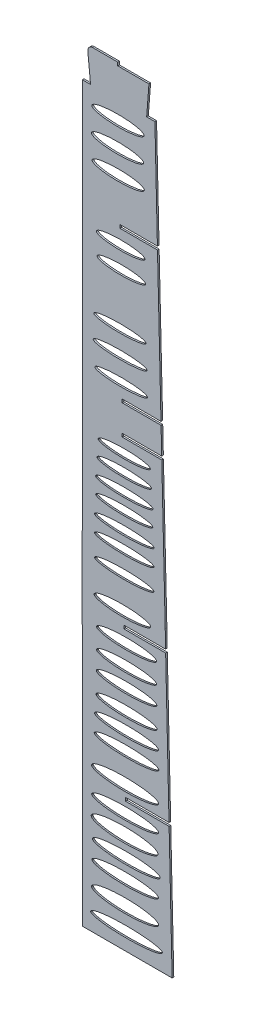
SolidWorks part; units mm, degrees
ref_plane "前视基准面" through (0, 0, 0) normal (0, 0, 1) x (1, 0, 0)
ref_plane "上视基准面" through (0, 0, 0) normal (0, 1, 0) x (1, 0, 0)
ref_plane "右视基准面" through (0, 0, 0) normal (1, 0, 0) x (0, 0, -1)
sketch "Model" plane through (0, 0, 0) normal (0, 0, 1) x (1, 0, 0)
  line L0 (944.9693, 755.1146) -> (946.7405, 678.6966)
  line L1 (919.6675, 757.1146) -> (944.9063, 757.1146)
  line L2 (944.9063, 757.1146) -> (944.7082, 767.7398)
  line L3 (946.7405, 678.6966) -> (947.021, 667.1146)
  line L4 (947.0676, 665.1146) -> (948.898, 586.3642)
  line L5 (894.424, 586.3642) -> (894.424, 679.6873)
  line L6 (920.73, 667.1146) -> (947.021, 667.1146)
  line L7 (948.898, 586.3642) -> (894.424, 586.3642)
  line L8 (894.3663, 767.5664) -> (894.4177, 858.9139)
  line L9 (918.5054, 857.3645) -> (942.5709, 857.3645)
  line L10 (918.517, 855.3645) -> (942.6163, 855.3645)
  line L11 (918.5054, 857.3645) -> (918.517, 855.3645)
  line L12 (894.3663, 767.5664) -> (894.424, 679.6873)
  line L13 (942.6163, 855.3645) -> (944.7082, 767.7398)
  line L14 (920.73, 667.1146) -> (920.73, 665.1146)
  line L15 (920.73, 665.1146) -> (947.0676, 665.1146)
  line L16 (919.6675, 757.1146) -> (919.6675, 755.1146)
  line L17 (919.6675, 755.1146) -> (944.9693, 755.1146)
  line L18 (915.9003, 1051.017) -> (915.9003, 1049.017)
  line L19 (915.9003, 1049.017) -> (934.8372, 1049.017)
  line L20 (900.7327, 1051.017) -> (915.9003, 1051.017)
  line L21 (939.6159, 981.017) -> (938.4551, 1031.017)
  line L22 (894.4177, 981.017) -> (894.4177, 1031.017)
  line L23 (894.4177, 1031.017) -> (899.4177, 1031.017)
  line L24 (899.4177, 1031.017) -> (897.7476, 1047.7185)
  line L25 (933.4551, 1031.017) -> (934.8372, 1049.017)
  line L26 (933.4551, 1031.017) -> (938.4551, 1031.017)
  line L27 (942.5709, 857.3645) -> (942.1886, 873.3666)
  line L28 (918.5654, 873.3666) -> (942.1886, 873.3666)
  line L29 (918.5477, 875.3666) -> (942.1408, 875.3666)
  line L30 (918.5654, 873.3666) -> (918.5477, 875.3666)
  line L31 (942.1408, 875.3666) -> (941.0498, 921.017)
  line L32 (940.0141, 964.3527) -> (917.2431, 964.3527)
  line L33 (917.2431, 966.3527) -> (939.9663, 966.3527)
  line L34 (917.2431, 966.3527) -> (917.2431, 964.3527)
  line L35 (941.0498, 921.017) -> (940.0141, 964.3527)
  line L36 (894.4177, 858.9139) -> (894.4177, 921.017)
  line L37 (894.4177, 921.017) -> (894.4177, 981.017)
  line L38 (939.9663, 966.3527) -> (939.6159, 981.017)
  line L39 (935.8831, 764.3267) -> (935.8631, 764.1667)
  line L40 (935.8631, 764.1667) -> (935.8031, 764.0067)
  line L41 (935.8031, 764.0067) -> (935.7031, 763.8487)
  line L42 (935.7031, 763.8487) -> (935.5531, 763.6907)
  line L43 (935.5531, 763.6907) -> (935.3731, 763.5337)
  line L44 (935.3731, 763.5337) -> (935.1431, 763.3797)
  line L45 (935.1431, 763.3797) -> (934.8831, 763.2277)
  line L46 (934.8831, 763.2277) -> (934.5831, 763.0777)
  line L47 (934.5831, 763.0777) -> (934.2331, 762.9317)
  line L48 (934.2331, 762.9317) -> (933.8631, 762.7887)
  line L49 (933.8631, 762.7887) -> (933.4431, 762.6487)
  line L50 (933.4431, 762.6487) -> (932.9931, 762.5137)
  line L51 (932.9931, 762.5137) -> (932.5131, 762.3827)
  line L52 (932.5131, 762.3827) -> (931.9931, 762.2567)
  line L53 (931.9931, 762.2567) -> (931.4431, 762.1357)
  line L54 (931.4431, 762.1357) -> (930.8631, 762.0197)
  line L55 (930.8631, 762.0197) -> (930.2531, 761.9087)
  line L56 (930.2531, 761.9087) -> (929.6131, 761.8037)
  line L57 (929.6131, 761.8037) -> (928.9531, 761.7057)
  line L58 (928.9531, 761.7057) -> (928.2631, 761.6137)
  line L59 (928.2631, 761.6137) -> (927.5531, 761.5277)
  line L60 (927.5531, 761.5277) -> (926.8131, 761.4487)
  line L61 (926.8131, 761.4487) -> (926.0631, 761.3767)
  line L62 (926.0631, 761.3767) -> (925.2931, 761.3117)
  line L63 (925.2931, 761.3117) -> (924.5131, 761.2537)
  line L64 (924.5131, 761.2537) -> (923.7131, 761.2037)
  line L65 (923.7131, 761.2037) -> (922.9031, 761.1607)
  line L66 (922.9031, 761.1607) -> (922.0831, 761.1257)
  line L67 (922.0831, 761.1257) -> (921.2531, 761.0987)
  line L68 (921.2531, 761.0987) -> (920.4131, 761.0787)
  line L69 (920.4131, 761.0787) -> (919.5731, 761.0677)
  line L70 (919.5731, 761.0677) -> (918.7331, 761.0637)
  line L71 (918.7331, 761.0637) -> (917.8931, 761.0677)
  line L72 (917.8931, 761.0677) -> (917.0531, 761.0787)
  line L73 (917.0531, 761.0787) -> (916.2131, 761.0987)
  line L74 (916.2131, 761.0987) -> (915.3831, 761.1257)
  line L75 (915.3831, 761.1257) -> (914.5631, 761.1607)
  line L76 (914.5631, 761.1607) -> (913.7531, 761.2037)
  line L77 (913.7531, 761.2037) -> (912.9531, 761.2537)
  line L78 (912.9531, 761.2537) -> (912.1731, 761.3117)
  line L79 (912.1731, 761.3117) -> (911.4031, 761.3767)
  line L80 (911.4031, 761.3767) -> (910.6431, 761.4487)
  line L81 (910.6431, 761.4487) -> (909.9131, 761.5277)
  line L82 (909.9131, 761.5277) -> (909.2031, 761.6137)
  line L83 (909.2031, 761.6137) -> (908.5131, 761.7057)
  line L84 (908.5131, 761.7057) -> (907.8531, 761.8037)
  line L85 (907.8531, 761.8037) -> (907.2131, 761.9087)
  line L86 (907.2131, 761.9087) -> (906.6031, 762.0197)
  line L87 (906.6031, 762.0197) -> (906.0231, 762.1357)
  line L88 (906.0231, 762.1357) -> (905.4731, 762.2567)
  line L89 (905.4731, 762.2567) -> (904.9531, 762.3827)
  line L90 (904.9531, 762.3827) -> (904.4731, 762.5137)
  line L91 (904.4731, 762.5137) -> (904.0231, 762.6487)
  line L92 (904.0231, 762.6487) -> (903.6031, 762.7887)
  line L93 (903.6031, 762.7887) -> (903.2331, 762.9317)
  line L94 (903.2331, 762.9317) -> (902.8831, 763.0777)
  line L95 (902.8831, 763.0777) -> (902.5831, 763.2277)
  line L96 (902.5831, 763.2277) -> (902.3231, 763.3797)
  line L97 (902.3231, 763.3797) -> (902.0931, 763.5337)
  line L98 (902.0931, 763.5337) -> (901.9131, 763.6907)
  line L99 (901.9131, 763.6907) -> (901.7631, 763.8487)
  line L100 (901.7631, 763.8487) -> (901.6631, 764.0067)
  line L101 (901.6631, 764.0067) -> (901.6031, 764.1667)
  line L102 (901.6031, 764.1667) -> (901.5831, 764.3267)
  line L103 (901.5831, 764.3267) -> (901.6031, 764.4877)
  line L104 (901.6031, 764.4877) -> (901.6631, 764.6467)
  line L105 (901.6631, 764.6467) -> (901.7631, 764.8057)
  line L106 (901.7631, 764.8057) -> (901.9131, 764.9637)
  line L107 (901.9131, 764.9637) -> (902.0931, 765.1197)
  line L108 (902.0931, 765.1197) -> (902.3231, 765.2747)
  line L109 (902.3231, 765.2747) -> (902.5831, 765.4267)
  line L110 (902.5831, 765.4267) -> (902.8831, 765.5757)
  line L111 (902.8831, 765.5757) -> (903.2331, 765.7227)
  line L112 (903.2331, 765.7227) -> (903.6031, 765.8657)
  line L113 (903.6031, 765.8657) -> (904.0231, 766.0047)
  line L114 (904.0231, 766.0047) -> (904.4731, 766.1407)
  line L115 (904.4731, 766.1407) -> (904.9531, 766.2717)
  line L116 (904.9531, 766.2717) -> (905.4731, 766.3977)
  line L117 (905.4731, 766.3977) -> (906.0231, 766.5187)
  line L118 (906.0231, 766.5187) -> (906.6031, 766.6347)
  line L119 (906.6031, 766.6347) -> (907.2131, 766.7457)
  line L120 (907.2131, 766.7457) -> (907.8531, 766.8497)
  line L121 (907.8531, 766.8497) -> (908.5131, 766.9487)
  line L122 (908.5131, 766.9487) -> (909.2031, 767.0407)
  line L123 (909.2031, 767.0407) -> (909.9131, 767.1267)
  line L124 (909.9131, 767.1267) -> (910.6431, 767.2057)
  line L125 (910.6431, 767.2057) -> (911.4031, 767.2777)
  line L126 (911.4031, 767.2777) -> (912.1731, 767.3427)
  line L127 (912.1731, 767.3427) -> (912.9531, 767.3997)
  line L128 (912.9531, 767.3997) -> (913.7531, 767.4507)
  line L129 (913.7531, 767.4507) -> (914.5631, 767.4927)
  line L130 (914.5631, 767.4927) -> (915.3831, 767.5277)
  line L131 (915.3831, 767.5277) -> (916.2131, 767.5557)
  line L132 (916.2131, 767.5557) -> (917.0531, 767.5747)
  line L133 (917.0531, 767.5747) -> (917.8931, 767.5867)
  line L134 (917.8931, 767.5867) -> (918.7331, 767.5907)
  line L135 (918.7331, 767.5907) -> (919.5731, 767.5867)
  line L136 (919.5731, 767.5867) -> (920.4131, 767.5747)
  line L137 (920.4131, 767.5747) -> (921.2531, 767.5557)
  line L138 (921.2531, 767.5557) -> (922.0831, 767.5277)
  line L139 (922.0831, 767.5277) -> (922.9031, 767.4927)
  line L140 (922.9031, 767.4927) -> (923.7131, 767.4507)
  line L141 (923.7131, 767.4507) -> (924.5131, 767.3997)
  line L142 (924.5131, 767.3997) -> (925.2931, 767.3427)
  line L143 (925.2931, 767.3427) -> (926.0631, 767.2777)
  line L144 (926.0631, 767.2777) -> (926.8131, 767.2057)
  line L145 (926.8131, 767.2057) -> (927.5531, 767.1267)
  line L146 (927.5531, 767.1267) -> (928.2631, 767.0407)
  line L147 (928.2631, 767.0407) -> (928.9531, 766.9487)
  line L148 (928.9531, 766.9487) -> (929.6131, 766.8497)
  line L149 (929.6131, 766.8497) -> (930.2531, 766.7457)
  line L150 (930.2531, 766.7457) -> (930.8631, 766.6347)
  line L151 (930.8631, 766.6347) -> (931.4431, 766.5187)
  line L152 (931.4431, 766.5187) -> (931.9931, 766.3977)
  line L153 (931.9931, 766.3977) -> (932.5131, 766.2717)
  line L154 (932.5131, 766.2717) -> (932.9931, 766.1407)
  line L155 (932.9931, 766.1407) -> (933.4431, 766.0047)
  line L156 (933.4431, 766.0047) -> (933.8631, 765.8657)
  line L157 (933.8631, 765.8657) -> (934.2331, 765.7227)
  line L158 (934.2331, 765.7227) -> (934.5831, 765.5757)
  line L159 (934.5831, 765.5757) -> (934.8831, 765.4267)
  line L160 (934.8831, 765.4267) -> (935.1431, 765.2747)
  line L161 (935.1431, 765.2747) -> (935.3731, 765.1197)
  line L162 (935.3731, 765.1197) -> (935.5531, 764.9637)
  line L163 (935.5531, 764.9637) -> (935.7031, 764.8057)
  line L164 (935.7031, 764.8057) -> (935.8031, 764.6467)
  line L165 (935.8031, 764.6467) -> (935.8631, 764.4877)
  line L166 (935.8631, 764.4877) -> (935.8831, 764.3267)
  line L167 (939.4731, 748.0287) -> (939.4531, 747.8677)
  line L168 (939.4531, 747.8677) -> (939.3831, 747.7087)
  line L169 (939.3831, 747.7087) -> (939.2731, 747.5497)
  line L170 (939.2731, 747.5497) -> (939.1231, 747.3917)
  line L171 (939.1231, 747.3917) -> (938.9331, 747.2357)
  line L172 (938.9331, 747.2357) -> (938.6931, 747.0807)
  line L173 (938.6931, 747.0807) -> (938.4131, 746.9287)
  line L174 (938.4131, 746.9287) -> (938.0831, 746.7797)
  line L175 (938.0831, 746.7797) -> (937.7231, 746.6327)
  line L176 (937.7231, 746.6327) -> (937.3231, 746.4897)
  line L177 (937.3231, 746.4897) -> (936.8831, 746.3507)
  line L178 (936.8831, 746.3507) -> (936.4031, 746.2147)
  line L179 (936.4031, 746.2147) -> (935.8931, 746.0837)
  line L180 (935.8931, 746.0837) -> (935.3431, 745.9577)
  line L181 (935.3431, 745.9577) -> (934.7531, 745.8367)
  line L182 (934.7531, 745.8367) -> (934.1431, 745.7207)
  line L183 (934.1431, 745.7207) -> (933.4931, 745.6097)
  line L184 (933.4931, 745.6097) -> (932.8131, 745.5057)
  line L185 (932.8131, 745.5057) -> (932.1131, 745.4067)
  line L186 (932.1131, 745.4067) -> (931.3831, 745.3147)
  line L187 (931.3831, 745.3147) -> (930.6231, 745.2287)
  line L188 (930.6231, 745.2287) -> (929.8531, 745.1497)
  line L189 (929.8531, 745.1497) -> (929.0531, 745.0777)
  line L190 (929.0531, 745.0777) -> (928.2331, 745.0127)
  line L191 (928.2331, 745.0127) -> (927.4031, 744.9557)
  line L192 (927.4031, 744.9557) -> (926.5531, 744.9047)
  line L193 (926.5531, 744.9047) -> (925.6931, 744.8627)
  line L194 (925.6931, 744.8627) -> (924.8231, 744.8267)
  line L195 (924.8231, 744.8267) -> (923.9431, 744.7997)
  line L196 (923.9431, 744.7997) -> (923.0531, 744.7797)
  line L197 (923.0531, 744.7797) -> (922.1631, 744.7687)
  line L198 (922.1631, 744.7687) -> (921.2631, 744.7647)
  line L199 (921.2631, 744.7647) -> (920.3731, 744.7687)
  line L200 (920.3731, 744.7687) -> (919.4831, 744.7797)
  line L201 (919.4831, 744.7797) -> (918.5931, 744.7997)
  line L202 (918.5931, 744.7997) -> (917.7131, 744.8267)
  line L203 (917.7131, 744.8267) -> (916.8431, 744.8627)
  line L204 (916.8431, 744.8627) -> (915.9831, 744.9047)
  line L205 (915.9831, 744.9047) -> (915.1331, 744.9557)
  line L206 (915.1331, 744.9557) -> (914.3031, 745.0127)
  line L207 (914.3031, 745.0127) -> (913.4831, 745.0777)
  line L208 (913.4831, 745.0777) -> (912.6831, 745.1497)
  line L209 (912.6831, 745.1497) -> (911.9031, 745.2287)
  line L210 (911.9031, 745.2287) -> (911.1531, 745.3147)
  line L211 (911.1531, 745.3147) -> (910.4231, 745.4067)
  line L212 (910.4231, 745.4067) -> (909.7131, 745.5057)
  line L213 (909.7131, 745.5057) -> (909.0431, 745.6097)
  line L214 (909.0431, 745.6097) -> (908.3931, 745.7207)
  line L215 (908.3931, 745.7207) -> (907.7731, 745.8367)
  line L216 (907.7731, 745.8367) -> (907.1931, 745.9577)
  line L217 (907.1931, 745.9577) -> (906.6431, 746.0837)
  line L218 (906.6431, 746.0837) -> (906.1331, 746.2147)
  line L219 (906.1331, 746.2147) -> (905.6531, 746.3507)
  line L220 (905.6531, 746.3507) -> (905.2131, 746.4897)
  line L221 (905.2131, 746.4897) -> (904.8131, 746.6327)
  line L222 (904.8131, 746.6327) -> (904.4431, 746.7797)
  line L223 (904.4431, 746.7797) -> (904.1231, 746.9287)
  line L224 (904.1231, 746.9287) -> (903.8431, 747.0807)
  line L225 (903.8431, 747.0807) -> (903.6031, 747.2357)
  line L226 (903.6031, 747.2357) -> (903.4131, 747.3917)
  line L227 (903.4131, 747.3917) -> (903.2631, 747.5497)
  line L228 (903.2631, 747.5497) -> (903.1531, 747.7087)
  line L229 (903.1531, 747.7087) -> (903.0831, 747.8677)
  line L230 (903.0831, 747.8677) -> (903.0631, 748.0287)
  line L231 (903.0631, 748.0287) -> (903.0831, 748.1887)
  line L232 (903.0831, 748.1887) -> (903.1531, 748.3477)
  line L233 (903.1531, 748.3477) -> (903.2631, 748.5067)
  line L234 (903.2631, 748.5067) -> (903.4131, 748.6647)
  line L235 (903.4131, 748.6647) -> (903.6031, 748.8217)
  line L236 (903.6031, 748.8217) -> (903.8431, 748.9757)
  line L237 (903.8431, 748.9757) -> (904.1231, 749.1277)
  line L238 (904.1231, 749.1277) -> (904.4431, 749.2777)
  line L239 (904.4431, 749.2777) -> (904.8131, 749.4237)
  line L240 (904.8131, 749.4237) -> (905.2131, 749.5667)
  line L241 (905.2131, 749.5667) -> (905.6531, 749.7057)
  line L242 (905.6531, 749.7057) -> (906.1331, 749.8417)
  line L243 (906.1331, 749.8417) -> (906.6431, 749.9727)
  line L244 (906.6431, 749.9727) -> (907.1931, 750.0987)
  line L245 (907.1931, 750.0987) -> (907.7731, 750.2197)
  line L246 (907.7731, 750.2197) -> (908.3931, 750.3357)
  line L247 (908.3931, 750.3357) -> (909.0431, 750.4467)
  line L248 (909.0431, 750.4467) -> (909.7131, 750.5507)
  line L249 (909.7131, 750.5507) -> (910.4231, 750.6497)
  line L250 (910.4231, 750.6497) -> (911.1531, 750.7417)
  line L251 (911.1531, 750.7417) -> (911.9031, 750.8277)
  line L252 (911.9031, 750.8277) -> (912.6831, 750.9067)
  line L253 (912.6831, 750.9067) -> (913.4831, 750.9787)
  line L254 (913.4831, 750.9787) -> (914.3031, 751.0437)
  line L255 (914.3031, 751.0437) -> (915.1331, 751.1017)
  line L256 (915.1331, 751.1017) -> (915.9831, 751.1517)
  line L257 (915.9831, 751.1517) -> (916.8431, 751.1947)
  line L258 (916.8431, 751.1947) -> (917.7131, 751.2297)
  line L259 (917.7131, 751.2297) -> (918.5931, 751.2567)
  line L260 (918.5931, 751.2567) -> (919.4831, 751.2767)
  line L261 (919.4831, 751.2767) -> (920.3731, 751.2877)
  line L262 (920.3731, 751.2877) -> (921.2631, 751.2917)
  line L263 (921.2631, 751.2917) -> (922.1631, 751.2877)
  line L264 (922.1631, 751.2877) -> (923.0531, 751.2767)
  line L265 (923.0531, 751.2767) -> (923.9431, 751.2567)
  line L266 (923.9431, 751.2567) -> (924.8231, 751.2297)
  line L267 (924.8231, 751.2297) -> (925.6931, 751.1947)
  line L268 (925.6931, 751.1947) -> (926.5531, 751.1517)
  line L269 (926.5531, 751.1517) -> (927.4031, 751.1017)
  line L270 (927.4031, 751.1017) -> (928.2331, 751.0437)
  line L271 (928.2331, 751.0437) -> (929.0531, 750.9787)
  line L272 (929.0531, 750.9787) -> (929.8531, 750.9067)
  line L273 (929.8531, 750.9067) -> (930.6231, 750.8277)
  line L274 (930.6231, 750.8277) -> (931.3831, 750.7417)
  line L275 (931.3831, 750.7417) -> (932.1131, 750.6497)
  line L276 (932.1131, 750.6497) -> (932.8131, 750.5507)
  line L277 (932.8131, 750.5507) -> (933.4931, 750.4467)
  line L278 (933.4931, 750.4467) -> (934.1431, 750.3357)
  line L279 (934.1431, 750.3357) -> (934.7531, 750.2197)
  line L280 (934.7531, 750.2197) -> (935.3431, 750.0987)
  line L281 (935.3431, 750.0987) -> (935.8931, 749.9727)
  line L282 (935.8931, 749.9727) -> (936.4031, 749.8417)
  line L283 (936.4031, 749.8417) -> (936.8831, 749.7057)
  line L284 (936.8831, 749.7057) -> (937.3231, 749.5667)
  line L285 (937.3231, 749.5667) -> (937.7231, 749.4237)
  line L286 (937.7231, 749.4237) -> (938.0831, 749.2777)
  line L287 (938.0831, 749.2777) -> (938.4131, 749.1277)
  line L288 (938.4131, 749.1277) -> (938.6931, 748.9757)
  line L289 (938.6931, 748.9757) -> (938.9331, 748.8217)
  line L290 (938.9331, 748.8217) -> (939.1231, 748.6647)
  line L291 (939.1231, 748.6647) -> (939.2731, 748.5067)
  line L292 (939.2731, 748.5067) -> (939.3831, 748.3477)
  line L293 (939.3831, 748.3477) -> (939.4531, 748.1887)
  line L294 (939.4531, 748.1887) -> (939.4731, 748.0287)
  line L295 (939.4731, 735.9697) -> (939.4531, 735.8097)
  line L296 (939.4531, 735.8097) -> (939.3831, 735.6497)
  line L297 (939.3831, 735.6497) -> (939.2731, 735.4917)
  line L298 (939.2731, 735.4917) -> (939.1231, 735.3337)
  line L299 (939.1231, 735.3337) -> (938.9331, 735.1767)
  line L300 (938.9331, 735.1767) -> (938.6931, 735.0227)
  line L301 (938.6931, 735.0227) -> (938.4131, 734.8707)
  line L302 (938.4131, 734.8707) -> (938.0831, 734.7207)
  line L303 (938.0831, 734.7207) -> (937.7231, 734.5747)
  line L304 (937.7231, 734.5747) -> (937.3231, 734.4317)
  line L305 (937.3231, 734.4317) -> (936.8831, 734.2917)
  line L306 (936.8831, 734.2917) -> (936.4031, 734.1567)
  line L307 (936.4031, 734.1567) -> (935.8931, 734.0257)
  line L308 (935.8931, 734.0257) -> (935.3431, 733.8997)
  line L309 (935.3431, 733.8997) -> (934.7531, 733.7787)
  line L310 (934.7531, 733.7787) -> (934.1431, 733.6627)
  line L311 (934.1431, 733.6627) -> (933.4931, 733.5517)
  line L312 (933.4931, 733.5517) -> (932.8131, 733.4467)
  line L313 (932.8131, 733.4467) -> (932.1131, 733.3487)
  line L314 (932.1131, 733.3487) -> (931.3831, 733.2567)
  line L315 (931.3831, 733.2567) -> (930.6231, 733.1707)
  line L316 (930.6231, 733.1707) -> (929.8531, 733.0917)
  line L317 (929.8531, 733.0917) -> (929.0531, 733.0197)
  line L318 (929.0531, 733.0197) -> (928.2331, 732.9547)
  line L319 (928.2331, 732.9547) -> (927.4031, 732.8967)
  line L320 (927.4031, 732.8967) -> (926.5531, 732.8467)
  line L321 (926.5531, 732.8467) -> (925.6931, 732.8037)
  line L322 (925.6931, 732.8037) -> (924.8231, 732.7687)
  line L323 (924.8231, 732.7687) -> (923.9431, 732.7417)
  line L324 (923.9431, 732.7417) -> (923.0531, 732.7217)
  line L325 (923.0531, 732.7217) -> (922.1631, 732.7107)
  line L326 (922.1631, 732.7107) -> (921.2631, 732.7067)
  line L327 (921.2631, 732.7067) -> (920.3731, 732.7107)
  line L328 (920.3731, 732.7107) -> (919.4831, 732.7217)
  line L329 (919.4831, 732.7217) -> (918.5931, 732.7417)
  line L330 (918.5931, 732.7417) -> (917.7131, 732.7687)
  line L331 (917.7131, 732.7687) -> (916.8431, 732.8037)
  line L332 (916.8431, 732.8037) -> (915.9831, 732.8467)
  line L333 (915.9831, 732.8467) -> (915.1331, 732.8967)
  line L334 (915.1331, 732.8967) -> (914.3031, 732.9547)
  line L335 (914.3031, 732.9547) -> (913.4831, 733.0197)
  line L336 (913.4831, 733.0197) -> (912.6831, 733.0917)
  line L337 (912.6831, 733.0917) -> (911.9031, 733.1707)
  line L338 (911.9031, 733.1707) -> (911.1531, 733.2567)
  line L339 (911.1531, 733.2567) -> (910.4231, 733.3487)
  line L340 (910.4231, 733.3487) -> (909.7131, 733.4467)
  line L341 (909.7131, 733.4467) -> (909.0431, 733.5517)
  line L342 (909.0431, 733.5517) -> (908.3931, 733.6627)
  line L343 (908.3931, 733.6627) -> (907.7731, 733.7787)
  line L344 (907.7731, 733.7787) -> (907.1931, 733.8997)
  line L345 (907.1931, 733.8997) -> (906.6431, 734.0257)
  line L346 (906.6431, 734.0257) -> (906.1331, 734.1567)
  line L347 (906.1331, 734.1567) -> (905.6531, 734.2917)
  line L348 (905.6531, 734.2917) -> (905.2131, 734.4317)
  line L349 (905.2131, 734.4317) -> (904.8131, 734.5747)
  line L350 (904.8131, 734.5747) -> (904.4431, 734.7207)
  line L351 (904.4431, 734.7207) -> (904.1231, 734.8707)
  line L352 (904.1231, 734.8707) -> (903.8431, 735.0227)
  line L353 (903.8431, 735.0227) -> (903.6031, 735.1767)
  line L354 (903.6031, 735.1767) -> (903.4131, 735.3337)
  line L355 (903.4131, 735.3337) -> (903.2631, 735.4917)
  line L356 (903.2631, 735.4917) -> (903.1531, 735.6497)
  line L357 (903.1531, 735.6497) -> (903.0831, 735.8097)
  line L358 (903.0831, 735.8097) -> (903.0631, 735.9697)
  line L359 (903.0631, 735.9697) -> (903.0831, 736.1307)
  line L360 (903.0831, 736.1307) -> (903.1531, 736.2897)
  line L361 (903.1531, 736.2897) -> (903.2631, 736.4487)
  line L362 (903.2631, 736.4487) -> (903.4131, 736.6067)
  line L363 (903.4131, 736.6067) -> (903.6031, 736.7627)
  line L364 (903.6031, 736.7627) -> (903.8431, 736.9177)
  line L365 (903.8431, 736.9177) -> (904.1231, 737.0697)
  line L366 (904.1231, 737.0697) -> (904.4431, 737.2187)
  line L367 (904.4431, 737.2187) -> (904.8131, 737.3657)
  line L368 (904.8131, 737.3657) -> (905.2131, 737.5087)
  line L369 (905.2131, 737.5087) -> (905.6531, 737.6477)
  line L370 (905.6531, 737.6477) -> (906.1331, 737.7837)
  line L371 (906.1331, 737.7837) -> (906.6431, 737.9147)
  line L372 (906.6431, 737.9147) -> (907.1931, 738.0407)
  line L373 (907.1931, 738.0407) -> (907.7731, 738.1617)
  line L374 (907.7731, 738.1617) -> (908.3931, 738.2777)
  line L375 (908.3931, 738.2777) -> (909.0431, 738.3887)
  line L376 (909.0431, 738.3887) -> (909.7131, 738.4927)
  line L377 (909.7131, 738.4927) -> (910.4231, 738.5917)
  line L378 (910.4231, 738.5917) -> (911.1531, 738.6837)
  line L379 (911.1531, 738.6837) -> (911.9031, 738.7697)
  line L380 (911.9031, 738.7697) -> (912.6831, 738.8487)
  line L381 (912.6831, 738.8487) -> (913.4831, 738.9207)
  line L382 (913.4831, 738.9207) -> (914.3031, 738.9857)
  line L383 (914.3031, 738.9857) -> (915.1331, 739.0427)
  line L384 (915.1331, 739.0427) -> (915.9831, 739.0937)
  line L385 (915.9831, 739.0937) -> (916.8431, 739.1357)
  line L386 (916.8431, 739.1357) -> (917.7131, 739.1707)
  line L387 (917.7131, 739.1707) -> (918.5931, 739.1987)
  line L388 (918.5931, 739.1987) -> (919.4831, 739.2177)
  line L389 (919.4831, 739.2177) -> (920.3731, 739.2297)
  line L390 (920.3731, 739.2297) -> (921.2631, 739.2337)
  line L391 (921.2631, 739.2337) -> (922.1631, 739.2297)
  line L392 (922.1631, 739.2297) -> (923.0531, 739.2177)
  line L393 (923.0531, 739.2177) -> (923.9431, 739.1987)
  line L394 (923.9431, 739.1987) -> (924.8231, 739.1707)
  line L395 (924.8231, 739.1707) -> (925.6931, 739.1357)
  line L396 (925.6931, 739.1357) -> (926.5531, 739.0937)
  line L397 (926.5531, 739.0937) -> (927.4031, 739.0427)
  line L398 (927.4031, 739.0427) -> (928.2331, 738.9857)
  line L399 (928.2331, 738.9857) -> (929.0531, 738.9207)
  line L400 (929.0531, 738.9207) -> (929.8531, 738.8487)
  line L401 (929.8531, 738.8487) -> (930.6231, 738.7697)
  line L402 (930.6231, 738.7697) -> (931.3831, 738.6837)
  line L403 (931.3831, 738.6837) -> (932.1131, 738.5917)
  line L404 (932.1131, 738.5917) -> (932.8131, 738.4927)
  line L405 (932.8131, 738.4927) -> (933.4931, 738.3887)
  line L406 (933.4931, 738.3887) -> (934.1431, 738.2777)
  line L407 (934.1431, 738.2777) -> (934.7531, 738.1617)
  line L408 (934.7531, 738.1617) -> (935.3431, 738.0407)
  line L409 (935.3431, 738.0407) -> (935.8931, 737.9147)
  line L410 (935.8931, 737.9147) -> (936.4031, 737.7837)
  line L411 (936.4031, 737.7837) -> (936.8831, 737.6477)
  line L412 (936.8831, 737.6477) -> (937.3231, 737.5087)
  line L413 (937.3231, 737.5087) -> (937.7231, 737.3657)
  line L414 (937.7231, 737.3657) -> (938.0831, 737.2187)
  line L415 (938.0831, 737.2187) -> (938.4131, 737.0697)
  line L416 (938.4131, 737.0697) -> (938.6931, 736.9177)
  line L417 (938.6931, 736.9177) -> (938.9331, 736.7627)
  line L418 (938.9331, 736.7627) -> (939.1231, 736.6067)
  line L419 (939.1231, 736.6067) -> (939.2731, 736.4487)
  line L420 (939.2731, 736.4487) -> (939.3831, 736.2897)
  line L421 (939.3831, 736.2897) -> (939.4531, 736.1307)
  line L422 (939.4531, 736.1307) -> (939.4731, 735.9697)
  line L423 (939.6431, 724.9347) -> (939.6231, 724.7737)
  line L424 (939.6231, 724.7737) -> (939.5531, 724.6147)
  line L425 (939.5531, 724.6147) -> (939.4431, 724.4557)
  line L426 (939.4431, 724.4557) -> (939.2831, 724.2977)
  line L427 (939.2831, 724.2977) -> (939.0931, 724.1417)
  line L428 (939.0931, 724.1417) -> (938.8531, 723.9867)
  line L429 (938.8531, 723.9867) -> (938.5631, 723.8347)
  line L430 (938.5631, 723.8347) -> (938.2431, 723.6857)
  line L431 (938.2431, 723.6857) -> (937.8731, 723.5387)
  line L432 (937.8731, 723.5387) -> (937.4731, 723.3957)
  line L433 (937.4731, 723.3957) -> (937.0231, 723.2567)
  line L434 (937.0231, 723.2567) -> (936.5431, 723.1207)
  line L435 (936.5431, 723.1207) -> (936.0231, 722.9897)
  line L436 (936.0231, 722.9897) -> (935.4731, 722.8637)
  line L437 (935.4731, 722.8637) -> (934.8831, 722.7427)
  line L438 (934.8831, 722.7427) -> (934.2631, 722.6267)
  line L439 (934.2631, 722.6267) -> (933.6031, 722.5157)
  line L440 (933.6031, 722.5157) -> (932.9231, 722.4117)
  line L441 (932.9231, 722.4117) -> (932.2131, 722.3127)
  line L442 (932.2131, 722.3127) -> (931.4731, 722.2207)
  line L443 (931.4731, 722.2207) -> (930.7131, 722.1347)
  line L444 (930.7131, 722.1347) -> (929.9331, 722.0557)
  line L445 (929.9331, 722.0557) -> (929.1231, 721.9837)
  line L446 (929.1231, 721.9837) -> (928.3031, 721.9187)
  line L447 (928.3031, 721.9187) -> (927.4531, 721.8617)
  line L448 (927.4531, 721.8617) -> (926.6031, 721.8107)
  line L449 (926.6031, 721.8107) -> (925.7331, 721.7687)
  line L450 (925.7331, 721.7687) -> (924.8531, 721.7337)
  line L451 (924.8531, 721.7337) -> (923.9631, 721.7057)
  line L452 (923.9631, 721.7057) -> (923.0731, 721.6867)
  line L453 (923.0731, 721.6867) -> (922.1731, 721.6747)
  line L454 (922.1731, 721.6747) -> (921.2631, 721.6707)
  line L455 (921.2631, 721.6707) -> (920.3631, 721.6747)
  line L456 (920.3631, 721.6747) -> (919.4631, 721.6867)
  line L457 (919.4631, 721.6867) -> (918.5731, 721.7057)
  line L458 (918.5731, 721.7057) -> (917.6831, 721.7337)
  line L459 (917.6831, 721.7337) -> (916.8031, 721.7687)
  line L460 (916.8031, 721.7687) -> (915.9331, 721.8107)
  line L461 (915.9331, 721.8107) -> (915.0731, 721.8617)
  line L462 (915.0731, 721.8617) -> (914.2331, 721.9187)
  line L463 (914.2331, 721.9187) -> (913.4131, 721.9837)
  line L464 (913.4131, 721.9837) -> (912.6031, 722.0557)
  line L465 (912.6031, 722.0557) -> (911.8231, 722.1347)
  line L466 (911.8231, 722.1347) -> (911.0631, 722.2207)
  line L467 (911.0631, 722.2207) -> (910.3231, 722.3127)
  line L468 (910.3231, 722.3127) -> (909.6131, 722.4117)
  line L469 (909.6131, 722.4117) -> (908.9331, 722.5157)
  line L470 (908.9331, 722.5157) -> (908.2731, 722.6267)
  line L471 (908.2731, 722.6267) -> (907.6531, 722.7427)
  line L472 (907.6531, 722.7427) -> (907.0631, 722.8637)
  line L473 (907.0631, 722.8637) -> (906.5131, 722.9897)
  line L474 (906.5131, 722.9897) -> (905.9931, 723.1207)
  line L475 (905.9931, 723.1207) -> (905.5131, 723.2567)
  line L476 (905.5131, 723.2567) -> (905.0631, 723.3957)
  line L477 (905.0631, 723.3957) -> (904.6631, 723.5387)
  line L478 (904.6631, 723.5387) -> (904.2931, 723.6857)
  line L479 (904.2931, 723.6857) -> (903.9731, 723.8347)
  line L480 (903.9731, 723.8347) -> (903.6831, 723.9867)
  line L481 (903.6831, 723.9867) -> (903.4431, 724.1417)
  line L482 (903.4431, 724.1417) -> (903.2431, 724.2977)
  line L483 (903.2431, 724.2977) -> (903.0931, 724.4557)
  line L484 (903.0931, 724.4557) -> (902.9831, 724.6147)
  line L485 (902.9831, 724.6147) -> (902.9131, 724.7737)
  line L486 (902.9131, 724.7737) -> (902.8931, 724.9347)
  line L487 (902.8931, 724.9347) -> (902.9131, 725.0947)
  line L488 (902.9131, 725.0947) -> (902.9831, 725.2537)
  line L489 (902.9831, 725.2537) -> (903.0931, 725.4127)
  line L490 (903.0931, 725.4127) -> (903.2431, 725.5707)
  line L491 (903.2431, 725.5707) -> (903.4431, 725.7277)
  line L492 (903.4431, 725.7277) -> (903.6831, 725.8817)
  line L493 (903.6831, 725.8817) -> (903.9731, 726.0337)
  line L494 (903.9731, 726.0337) -> (904.2931, 726.1837)
  line L495 (904.2931, 726.1837) -> (904.6631, 726.3297)
  line L496 (904.6631, 726.3297) -> (905.0631, 726.4727)
  line L497 (905.0631, 726.4727) -> (905.5131, 726.6117)
  line L498 (905.5131, 726.6117) -> (905.9931, 726.7477)
  line L499 (905.9931, 726.7477) -> (906.5131, 726.8787)
  line L500 (906.5131, 726.8787) -> (907.0631, 727.0047)
  line L501 (907.0631, 727.0047) -> (907.6531, 727.1257)
  line L502 (907.6531, 727.1257) -> (908.2731, 727.2417)
  line L503 (908.2731, 727.2417) -> (908.9331, 727.3527)
  line L504 (908.9331, 727.3527) -> (909.6131, 727.4567)
  line L505 (909.6131, 727.4567) -> (910.3231, 727.5557)
  line L506 (910.3231, 727.5557) -> (911.0631, 727.6477)
  line L507 (911.0631, 727.6477) -> (911.8231, 727.7337)
  line L508 (911.8231, 727.7337) -> (912.6031, 727.8127)
  line L509 (912.6031, 727.8127) -> (913.4131, 727.8847)
  line L510 (913.4131, 727.8847) -> (914.2331, 727.9497)
  line L511 (914.2331, 727.9497) -> (915.0731, 728.0077)
  line L512 (915.0731, 728.0077) -> (915.9331, 728.0577)
  line L513 (915.9331, 728.0577) -> (916.8031, 728.1007)
  line L514 (916.8031, 728.1007) -> (917.6831, 728.1357)
  line L515 (917.6831, 728.1357) -> (918.5731, 728.1627)
  line L516 (918.5731, 728.1627) -> (919.4631, 728.1827)
  line L517 (919.4631, 728.1827) -> (920.3631, 728.1937)
  line L518 (920.3631, 728.1937) -> (921.2631, 728.1977)
  line L519 (921.2631, 728.1977) -> (922.1731, 728.1937)
  line L520 (922.1731, 728.1937) -> (923.0731, 728.1827)
  line L521 (923.0731, 728.1827) -> (923.9631, 728.1627)
  line L522 (923.9631, 728.1627) -> (924.8531, 728.1357)
  line L523 (924.8531, 728.1357) -> (925.7331, 728.1007)
  line L524 (925.7331, 728.1007) -> (926.6031, 728.0577)
  line L525 (926.6031, 728.0577) -> (927.4531, 728.0077)
  line L526 (927.4531, 728.0077) -> (928.3031, 727.9497)
  line L527 (928.3031, 727.9497) -> (929.1231, 727.8847)
  line L528 (929.1231, 727.8847) -> (929.9331, 727.8127)
  line L529 (929.9331, 727.8127) -> (930.7131, 727.7337)
  line L530 (930.7131, 727.7337) -> (931.4731, 727.6477)
  line L531 (931.4731, 727.6477) -> (932.2131, 727.5557)
  line L532 (932.2131, 727.5557) -> (932.9231, 727.4567)
  line L533 (932.9231, 727.4567) -> (933.6031, 727.3527)
  line L534 (933.6031, 727.3527) -> (934.2631, 727.2417)
  line L535 (934.2631, 727.2417) -> (934.8831, 727.1257)
  line L536 (934.8831, 727.1257) -> (935.4731, 727.0047)
  line L537 (935.4731, 727.0047) -> (936.0231, 726.8787)
  line L538 (936.0231, 726.8787) -> (936.5431, 726.7477)
  line L539 (936.5431, 726.7477) -> (937.0231, 726.6117)
  line L540 (937.0231, 726.6117) -> (937.4731, 726.4727)
  line L541 (937.4731, 726.4727) -> (937.8731, 726.3297)
  line L542 (937.8731, 726.3297) -> (938.2431, 726.1837)
  line L543 (938.2431, 726.1837) -> (938.5631, 726.0337)
  line L544 (938.5631, 726.0337) -> (938.8531, 725.8817)
  line L545 (938.8531, 725.8817) -> (939.0931, 725.7277)
  line L546 (939.0931, 725.7277) -> (939.2831, 725.5707)
  line L547 (939.2831, 725.5707) -> (939.4431, 725.4127)
  line L548 (939.4431, 725.4127) -> (939.5531, 725.2537)
  line L549 (939.5531, 725.2537) -> (939.6231, 725.0947)
  line L550 (939.6231, 725.0947) -> (939.6431, 724.9347)
  line L551 (939.8031, 712.3957) -> (939.7831, 712.2357)
  line L552 (939.7831, 712.2357) -> (939.7231, 712.0757)
  line L553 (939.7231, 712.0757) -> (939.6031, 711.9167)
  line L554 (939.6031, 711.9167) -> (939.4531, 711.7587)
  line L555 (939.4531, 711.7587) -> (939.2531, 711.6027)
  line L556 (939.2531, 711.6027) -> (939.0131, 711.4487)
  line L557 (939.0131, 711.4487) -> (938.7231, 711.2957)
  line L558 (938.7231, 711.2957) -> (938.3931, 711.1467)
  line L559 (938.3931, 711.1467) -> (938.0231, 711.0007)
  line L560 (938.0231, 711.0007) -> (937.6231, 710.8567)
  line L561 (937.6231, 710.8567) -> (937.1731, 710.7177)
  line L562 (937.1731, 710.7177) -> (936.6831, 710.5827)
  line L563 (936.6831, 710.5827) -> (936.1631, 710.4517)
  line L564 (936.1631, 710.4517) -> (935.6031, 710.3257)
  line L565 (935.6031, 710.3257) -> (935.0031, 710.2037)
  line L566 (935.0031, 710.2037) -> (934.3731, 710.0877)
  line L567 (934.3731, 710.0877) -> (933.7231, 709.9777)
  line L568 (933.7231, 709.9777) -> (933.0331, 709.8727)
  line L569 (933.0331, 709.8727) -> (932.3131, 709.7747)
  line L570 (932.3131, 709.7747) -> (931.5631, 709.6817)
  line L571 (931.5631, 709.6817) -> (930.8031, 709.5967)
  line L572 (930.8031, 709.5967) -> (930.0031, 709.5177)
  line L573 (930.0031, 709.5177) -> (929.1931, 709.4457)
  line L574 (929.1931, 709.4457) -> (928.3631, 709.3807)
  line L575 (928.3631, 709.3807) -> (927.5131, 709.3227)
  line L576 (927.5131, 709.3227) -> (926.6531, 709.2727)
  line L577 (926.6531, 709.2727) -> (925.7731, 709.2297)
  line L578 (925.7731, 709.2297) -> (924.8831, 709.1947)
  line L579 (924.8831, 709.1947) -> (923.9831, 709.1677)
  line L580 (923.9831, 709.1677) -> (923.0831, 709.1477)
  line L581 (923.0831, 709.1477) -> (922.1731, 709.1357)
  line L582 (922.1731, 709.1357) -> (921.2631, 709.1317)
  line L583 (921.2631, 709.1317) -> (920.3531, 709.1357)
  line L584 (920.3531, 709.1357) -> (919.4531, 709.1477)
  line L585 (919.4531, 709.1477) -> (918.5431, 709.1677)
  line L586 (918.5431, 709.1677) -> (917.6531, 709.1947)
  line L587 (917.6531, 709.1947) -> (916.7631, 709.2297)
  line L588 (916.7631, 709.2297) -> (915.8831, 709.2727)
  line L589 (915.8831, 709.2727) -> (915.0231, 709.3227)
  line L590 (915.0231, 709.3227) -> (914.1731, 709.3807)
  line L591 (914.1731, 709.3807) -> (913.3431, 709.4457)
  line L592 (913.3431, 709.4457) -> (912.5231, 709.5177)
  line L593 (912.5231, 709.5177) -> (911.7331, 709.5967)
  line L594 (911.7331, 709.5967) -> (910.9631, 709.6817)
  line L595 (910.9631, 709.6817) -> (910.2231, 709.7747)
  line L596 (910.2231, 709.7747) -> (909.5031, 709.8727)
  line L597 (909.5031, 709.8727) -> (908.8131, 709.9777)
  line L598 (908.8131, 709.9777) -> (908.1531, 710.0877)
  line L599 (908.1531, 710.0877) -> (907.5331, 710.2037)
  line L600 (907.5331, 710.2037) -> (906.9331, 710.3257)
  line L601 (906.9331, 710.3257) -> (906.3731, 710.4517)
  line L602 (906.3731, 710.4517) -> (905.8531, 710.5827)
  line L603 (905.8531, 710.5827) -> (905.3631, 710.7177)
  line L604 (905.3631, 710.7177) -> (904.9131, 710.8567)
  line L605 (904.9131, 710.8567) -> (904.5031, 711.0007)
  line L606 (904.5031, 711.0007) -> (904.1431, 711.1467)
  line L607 (904.1431, 711.1467) -> (903.8131, 711.2957)
  line L608 (903.8131, 711.2957) -> (903.5231, 711.4487)
  line L609 (903.5231, 711.4487) -> (903.2831, 711.6027)
  line L610 (903.2831, 711.6027) -> (903.0831, 711.7587)
  line L611 (903.0831, 711.7587) -> (902.9331, 711.9167)
  line L612 (902.9331, 711.9167) -> (902.8131, 712.0757)
  line L613 (902.8131, 712.0757) -> (902.7531, 712.2357)
  line L614 (902.7531, 712.2357) -> (902.7231, 712.3957)
  line L615 (902.7231, 712.3957) -> (902.7531, 712.5557)
  line L616 (902.7531, 712.5557) -> (902.8131, 712.7157)
  line L617 (902.8131, 712.7157) -> (902.9331, 712.8747)
  line L618 (902.9331, 712.8747) -> (903.0831, 713.0327)
  line L619 (903.0831, 713.0327) -> (903.2831, 713.1887)
  line L620 (903.2831, 713.1887) -> (903.5231, 713.3427)
  line L621 (903.5231, 713.3427) -> (903.8131, 713.4957)
  line L622 (903.8131, 713.4957) -> (904.1431, 713.6447)
  line L623 (904.1431, 713.6447) -> (904.5031, 713.7907)
  line L624 (904.5031, 713.7907) -> (904.9131, 713.9347)
  line L625 (904.9131, 713.9347) -> (905.3631, 714.0737)
  line L626 (905.3631, 714.0737) -> (905.8531, 714.2087)
  line L627 (905.8531, 714.2087) -> (906.3731, 714.3397)
  line L628 (906.3731, 714.3397) -> (906.9331, 714.4667)
  line L629 (906.9331, 714.4667) -> (907.5331, 714.5877)
  line L630 (907.5331, 714.5877) -> (908.1531, 714.7037)
  line L631 (908.1531, 714.7037) -> (908.8131, 714.8137)
  line L632 (908.8131, 714.8137) -> (909.5031, 714.9187)
  line L633 (909.5031, 714.9187) -> (910.2231, 715.0177)
  line L634 (910.2231, 715.0177) -> (910.9631, 715.1097)
  line L635 (910.9631, 715.1097) -> (911.7331, 715.1947)
  line L636 (911.7331, 715.1947) -> (912.5231, 715.2737)
  line L637 (912.5231, 715.2737) -> (913.3431, 715.3457)
  line L638 (913.3431, 715.3457) -> (914.1731, 715.4107)
  line L639 (914.1731, 715.4107) -> (915.0231, 715.4687)
  line L640 (915.0231, 715.4687) -> (915.8831, 715.5187)
  line L641 (915.8831, 715.5187) -> (916.7631, 715.5617)
  line L642 (916.7631, 715.5617) -> (917.6531, 715.5967)
  line L643 (917.6531, 715.5967) -> (918.5431, 715.6237)
  line L644 (918.5431, 715.6237) -> (919.4531, 715.6437)
  line L645 (919.4531, 715.6437) -> (920.3531, 715.6557)
  line L646 (920.3531, 715.6557) -> (921.2631, 715.6597)
  line L647 (921.2631, 715.6597) -> (922.1731, 715.6557)
  line L648 (922.1731, 715.6557) -> (923.0831, 715.6437)
  line L649 (923.0831, 715.6437) -> (923.9831, 715.6237)
  line L650 (923.9831, 715.6237) -> (924.8831, 715.5967)
  line L651 (924.8831, 715.5967) -> (925.7731, 715.5617)
  line L652 (925.7731, 715.5617) -> (926.6531, 715.5187)
  line L653 (926.6531, 715.5187) -> (927.5131, 715.4687)
  line L654 (927.5131, 715.4687) -> (928.3631, 715.4107)
  line L655 (928.3631, 715.4107) -> (929.1931, 715.3457)
  line L656 (929.1931, 715.3457) -> (930.0031, 715.2737)
  line L657 (930.0031, 715.2737) -> (930.8031, 715.1947)
  line L658 (930.8031, 715.1947) -> (931.5631, 715.1097)
  line L659 (931.5631, 715.1097) -> (932.3131, 715.0177)
  line L660 (932.3131, 715.0177) -> (933.0331, 714.9187)
  line L661 (933.0331, 714.9187) -> (933.7231, 714.8137)
  line L662 (933.7231, 714.8137) -> (934.3731, 714.7037)
  line L663 (934.3731, 714.7037) -> (935.0031, 714.5877)
  line L664 (935.0031, 714.5877) -> (935.6031, 714.4667)
  line L665 (935.6031, 714.4667) -> (936.1631, 714.3397)
  line L666 (936.1631, 714.3397) -> (936.6831, 714.2087)
  line L667 (936.6831, 714.2087) -> (937.1731, 714.0737)
  line L668 (937.1731, 714.0737) -> (937.6231, 713.9347)
  line L669 (937.6231, 713.9347) -> (938.0231, 713.7907)
  line L670 (938.0231, 713.7907) -> (938.3931, 713.6447)
  line L671 (938.3931, 713.6447) -> (938.7231, 713.4957)
  line L672 (938.7231, 713.4957) -> (939.0131, 713.3427)
  line L673 (939.0131, 713.3427) -> (939.2531, 713.1887)
  line L674 (939.2531, 713.1887) -> (939.4531, 713.0327)
  line L675 (939.4531, 713.0327) -> (939.6031, 712.8747)
  line L676 (939.6031, 712.8747) -> (939.7231, 712.7157)
  line L677 (939.7231, 712.7157) -> (939.7831, 712.5557)
  line L678 (939.7831, 712.5557) -> (939.8031, 712.3957)
  line L679 (940.7031, 702.0707) -> (940.6731, 701.9107)
  line L680 (940.6731, 701.9107) -> (940.6031, 701.7517)
  line L681 (940.6031, 701.7517) -> (940.4831, 701.5927)
  line L682 (940.4831, 701.5927) -> (940.3231, 701.4347)
  line L683 (940.3231, 701.4347) -> (940.1131, 701.2777)
  line L684 (940.1131, 701.2777) -> (939.8631, 701.1237)
  line L685 (939.8631, 701.1237) -> (939.5631, 700.9717)
  line L686 (939.5631, 700.9717) -> (939.2231, 700.8217)
  line L687 (939.2231, 700.8217) -> (938.8331, 700.6757)
  line L688 (938.8331, 700.6757) -> (938.4031, 700.5327)
  line L689 (938.4031, 700.5327) -> (937.9331, 700.3937)
  line L690 (937.9331, 700.3937) -> (937.4231, 700.2577)
  line L691 (937.4231, 700.2577) -> (936.8731, 700.1267)
  line L692 (936.8731, 700.1267) -> (936.2831, 700.0007)
  line L693 (936.2831, 700.0007) -> (935.6631, 699.8797)
  line L694 (935.6631, 699.8797) -> (935.0031, 699.7637)
  line L695 (935.0031, 699.7637) -> (934.3131, 699.6527)
  line L696 (934.3131, 699.6527) -> (933.5931, 699.5487)
  line L697 (933.5931, 699.5487) -> (932.8431, 699.4497)
  line L698 (932.8431, 699.4497) -> (932.0631, 699.3577)
  line L699 (932.0631, 699.3577) -> (931.2531, 699.2717)
  line L700 (931.2531, 699.2717) -> (930.4231, 699.1927)
  line L701 (930.4231, 699.1927) -> (929.5731, 699.1207)
  line L702 (929.5731, 699.1207) -> (928.7031, 699.0557)
  line L703 (928.7031, 699.0557) -> (927.8131, 698.9977)
  line L704 (927.8131, 698.9977) -> (926.9031, 698.9477)
  line L705 (926.9031, 698.9477) -> (925.9931, 698.9057)
  line L706 (925.9931, 698.9057) -> (925.0631, 698.8697)
  line L707 (925.0631, 698.8697) -> (924.1231, 698.8427)
  line L708 (924.1231, 698.8427) -> (923.1731, 698.8227)
  line L709 (923.1731, 698.8227) -> (922.2231, 698.8117)
  line L710 (922.2231, 698.8117) -> (921.2631, 698.8077)
  line L711 (921.2631, 698.8077) -> (920.3131, 698.8117)
  line L712 (920.3131, 698.8117) -> (919.3631, 698.8227)
  line L713 (919.3631, 698.8227) -> (918.4131, 698.8427)
  line L714 (918.4131, 698.8427) -> (917.4731, 698.8697)
  line L715 (917.4731, 698.8697) -> (916.5431, 698.9057)
  line L716 (916.5431, 698.9057) -> (915.6231, 698.9477)
  line L717 (915.6231, 698.9477) -> (914.7231, 698.9977)
  line L718 (914.7231, 698.9977) -> (913.8331, 699.0557)
  line L719 (913.8331, 699.0557) -> (912.9631, 699.1207)
  line L720 (912.9631, 699.1207) -> (912.1131, 699.1927)
  line L721 (912.1131, 699.1927) -> (911.2831, 699.2717)
  line L722 (911.2831, 699.2717) -> (910.4731, 699.3577)
  line L723 (910.4731, 699.3577) -> (909.6931, 699.4497)
  line L724 (909.6931, 699.4497) -> (908.9431, 699.5487)
  line L725 (908.9431, 699.5487) -> (908.2231, 699.6527)
  line L726 (908.2231, 699.6527) -> (907.5331, 699.7637)
  line L727 (907.5331, 699.7637) -> (906.8731, 699.8797)
  line L728 (906.8731, 699.8797) -> (906.2431, 700.0007)
  line L729 (906.2431, 700.0007) -> (905.6631, 700.1267)
  line L730 (905.6631, 700.1267) -> (905.1131, 700.2577)
  line L731 (905.1131, 700.2577) -> (904.6031, 700.3937)
  line L732 (904.6031, 700.3937) -> (904.1331, 700.5327)
  line L733 (904.1331, 700.5327) -> (903.7031, 700.6757)
  line L734 (903.7031, 700.6757) -> (903.3131, 700.8217)
  line L735 (903.3131, 700.8217) -> (902.9731, 700.9717)
  line L736 (902.9731, 700.9717) -> (902.6731, 701.1237)
  line L737 (902.6731, 701.1237) -> (902.4231, 701.2777)
  line L738 (902.4231, 701.2777) -> (902.2131, 701.4347)
  line L739 (902.2131, 701.4347) -> (902.0431, 701.5927)
  line L740 (902.0431, 701.5927) -> (901.9331, 701.7517)
  line L741 (901.9331, 701.7517) -> (901.8631, 701.9107)
  line L742 (901.8631, 701.9107) -> (901.8331, 702.0707)
  line L743 (901.8331, 702.0707) -> (901.8631, 702.2317)
  line L744 (901.8631, 702.2317) -> (901.9331, 702.3907)
  line L745 (901.9331, 702.3907) -> (902.0431, 702.5497)
  line L746 (902.0431, 702.5497) -> (902.2131, 702.7077)
  line L747 (902.2131, 702.7077) -> (902.4231, 702.8637)
  line L748 (902.4231, 702.8637) -> (902.6731, 703.0187)
  line L749 (902.6731, 703.0187) -> (902.9731, 703.1707)
  line L750 (902.9731, 703.1707) -> (903.3131, 703.3197)
  line L751 (903.3131, 703.3197) -> (903.7031, 703.4667)
  line L752 (903.7031, 703.4667) -> (904.1331, 703.6097)
  line L753 (904.1331, 703.6097) -> (904.6031, 703.7487)
  line L754 (904.6031, 703.7487) -> (905.1131, 703.8847)
  line L755 (905.1131, 703.8847) -> (905.6631, 704.0157)
  line L756 (905.6631, 704.0157) -> (906.2431, 704.1417)
  line L757 (906.2431, 704.1417) -> (906.8731, 704.2627)
  line L758 (906.8731, 704.2627) -> (907.5331, 704.3787)
  line L759 (907.5331, 704.3787) -> (908.2231, 704.4897)
  line L760 (908.2231, 704.4897) -> (908.9431, 704.5937)
  line L761 (908.9431, 704.5937) -> (909.6931, 704.6927)
  line L762 (909.6931, 704.6927) -> (910.4731, 704.7847)
  line L763 (910.4731, 704.7847) -> (911.2831, 704.8707)
  line L764 (911.2831, 704.8707) -> (912.1131, 704.9497)
  line L765 (912.1131, 704.9497) -> (912.9631, 705.0217)
  line L766 (912.9631, 705.0217) -> (913.8331, 705.0867)
  line L767 (913.8331, 705.0867) -> (914.7231, 705.1437)
  line L768 (914.7231, 705.1437) -> (915.6231, 705.1947)
  line L769 (915.6231, 705.1947) -> (916.5431, 705.2367)
  line L770 (916.5431, 705.2367) -> (917.4731, 705.2727)
  line L771 (917.4731, 705.2727) -> (918.4131, 705.2997)
  line L772 (918.4131, 705.2997) -> (919.3631, 705.3197)
  line L773 (919.3631, 705.3197) -> (920.3131, 705.3307)
  line L774 (920.3131, 705.3307) -> (921.2631, 705.3347)
  line L775 (921.2631, 705.3347) -> (922.2231, 705.3307)
  line L776 (922.2231, 705.3307) -> (923.1731, 705.3197)
  line L777 (923.1731, 705.3197) -> (924.1231, 705.2997)
  line L778 (924.1231, 705.2997) -> (925.0631, 705.2727)
  line L779 (925.0631, 705.2727) -> (925.9931, 705.2367)
  line L780 (925.9931, 705.2367) -> (926.9031, 705.1947)
  line L781 (926.9031, 705.1947) -> (927.8131, 705.1437)
  line L782 (927.8131, 705.1437) -> (928.7031, 705.0867)
  line L783 (928.7031, 705.0867) -> (929.5731, 705.0217)
  line L784 (929.5731, 705.0217) -> (930.4231, 704.9497)
  line L785 (930.4231, 704.9497) -> (931.2531, 704.8707)
  line L786 (931.2531, 704.8707) -> (932.0631, 704.7847)
  line L787 (932.0631, 704.7847) -> (932.8431, 704.6927)
  line L788 (932.8431, 704.6927) -> (933.5931, 704.5937)
  line L789 (933.5931, 704.5937) -> (934.3131, 704.4897)
  line L790 (934.3131, 704.4897) -> (935.0031, 704.3787)
  line L791 (935.0031, 704.3787) -> (935.6631, 704.2627)
  line L792 (935.6631, 704.2627) -> (936.2831, 704.1417)
  line L793 (936.2831, 704.1417) -> (936.8731, 704.0157)
  line L794 (936.8731, 704.0157) -> (937.4231, 703.8847)
  line L795 (937.4231, 703.8847) -> (937.9331, 703.7487)
  line L796 (937.9331, 703.7487) -> (938.4031, 703.6097)
  line L797 (938.4031, 703.6097) -> (938.8331, 703.4667)
  line L798 (938.8331, 703.4667) -> (939.2231, 703.3197)
  line L799 (939.2231, 703.3197) -> (939.5631, 703.1707)
  line L800 (939.5631, 703.1707) -> (939.8631, 703.0187)
  line L801 (939.8631, 703.0187) -> (940.1131, 702.8637)
  line L802 (940.1131, 702.8637) -> (940.3231, 702.7077)
  line L803 (940.3231, 702.7077) -> (940.4831, 702.5497)
  line L804 (940.4831, 702.5497) -> (940.6031, 702.3907)
  line L805 (940.6031, 702.3907) -> (940.6731, 702.2317)
  line L806 (940.6731, 702.2317) -> (940.7031, 702.0707)
  line L807 (940.8931, 691.5307) -> (940.8731, 691.3707)
  line L808 (940.8731, 691.3707) -> (940.8031, 691.2107)
  line L809 (940.8031, 691.2107) -> (940.6831, 691.0517)
  line L810 (940.6831, 691.0517) -> (940.5231, 690.8947)
  line L811 (940.5231, 690.8947) -> (940.3131, 690.7377)
  line L812 (940.3131, 690.7377) -> (940.0531, 690.5837)
  line L813 (940.0531, 690.5837) -> (939.7531, 690.4317)
  line L814 (939.7531, 690.4317) -> (939.4031, 690.2817)
  line L815 (939.4031, 690.2817) -> (939.0131, 690.1357)
  line L816 (939.0131, 690.1357) -> (938.5831, 689.9927)
  line L817 (938.5831, 689.9927) -> (938.1031, 689.8527)
  line L818 (938.1031, 689.8527) -> (937.5931, 689.7177)
  line L819 (937.5931, 689.7177) -> (937.0331, 689.5867)
  line L820 (937.0331, 689.5867) -> (936.4431, 689.4607)
  line L821 (936.4431, 689.4607) -> (935.8131, 689.3397)
  line L822 (935.8131, 689.3397) -> (935.1431, 689.2237)
  line L823 (935.1431, 689.2237) -> (934.4531, 689.1127)
  line L824 (934.4531, 689.1127) -> (933.7231, 689.0077)
  line L825 (933.7231, 689.0077) -> (932.9631, 688.9097)
  line L826 (932.9631, 688.9097) -> (932.1731, 688.8177)
  line L827 (932.1731, 688.8177) -> (931.3631, 688.7317)
  line L828 (931.3631, 688.7317) -> (930.5231, 688.6527)
  line L829 (930.5231, 688.6527) -> (929.6631, 688.5807)
  line L830 (929.6631, 688.5807) -> (928.7831, 688.5157)
  line L831 (928.7831, 688.5157) -> (927.8831, 688.4577)
  line L832 (927.8831, 688.4577) -> (926.9631, 688.4077)
  line L833 (926.9631, 688.4077) -> (926.0331, 688.3647)
  line L834 (926.0331, 688.3647) -> (925.0931, 688.3297)
  line L835 (925.0931, 688.3297) -> (924.1431, 688.3027)
  line L836 (924.1431, 688.3027) -> (923.1931, 688.2827)
  line L837 (923.1931, 688.2827) -> (922.2331, 688.2717)
  line L838 (922.2331, 688.2717) -> (921.2631, 688.2677)
  line L839 (921.2631, 688.2677) -> (920.3031, 688.2717)
  line L840 (920.3031, 688.2717) -> (919.3431, 688.2827)
  line L841 (919.3431, 688.2827) -> (918.3831, 688.3027)
  line L842 (918.3831, 688.3027) -> (917.4431, 688.3297)
  line L843 (917.4431, 688.3297) -> (916.5031, 688.3647)
  line L844 (916.5031, 688.3647) -> (915.5731, 688.4077)
  line L845 (915.5731, 688.4077) -> (914.6531, 688.4577)
  line L846 (914.6531, 688.4577) -> (913.7531, 688.5157)
  line L847 (913.7531, 688.5157) -> (912.8731, 688.5807)
  line L848 (912.8731, 688.5807) -> (912.0131, 688.6527)
  line L849 (912.0131, 688.6527) -> (911.1731, 688.7317)
  line L850 (911.1731, 688.7317) -> (910.3631, 688.8177)
  line L851 (910.3631, 688.8177) -> (909.5731, 688.9097)
  line L852 (909.5731, 688.9097) -> (908.8131, 689.0077)
  line L853 (908.8131, 689.0077) -> (908.0831, 689.1127)
  line L854 (908.0831, 689.1127) -> (907.3831, 689.2237)
  line L855 (907.3831, 689.2237) -> (906.7231, 689.3397)
  line L856 (906.7231, 689.3397) -> (906.0931, 689.4607)
  line L857 (906.0931, 689.4607) -> (905.5031, 689.5867)
  line L858 (905.5031, 689.5867) -> (904.9431, 689.7177)
  line L859 (904.9431, 689.7177) -> (904.4331, 689.8527)
  line L860 (904.4331, 689.8527) -> (903.9531, 689.9927)
  line L861 (903.9531, 689.9927) -> (903.5231, 690.1357)
  line L862 (903.5231, 690.1357) -> (903.1331, 690.2817)
  line L863 (903.1331, 690.2817) -> (902.7831, 690.4317)
  line L864 (902.7831, 690.4317) -> (902.4831, 690.5837)
  line L865 (902.4831, 690.5837) -> (902.2231, 690.7377)
  line L866 (902.2231, 690.7377) -> (902.0131, 690.8947)
  line L867 (902.0131, 690.8947) -> (901.8531, 691.0517)
  line L868 (901.8531, 691.0517) -> (901.7331, 691.2107)
  line L869 (901.7331, 691.2107) -> (901.6631, 691.3707)
  line L870 (901.6631, 691.3707) -> (901.6431, 691.5307)
  line L871 (901.6431, 691.5307) -> (901.6631, 691.6907)
  line L872 (901.6631, 691.6907) -> (901.7331, 691.8507)
  line L873 (901.7331, 691.8507) -> (901.8531, 692.0097)
  line L874 (901.8531, 692.0097) -> (902.0131, 692.1677)
  line L875 (902.0131, 692.1677) -> (902.2231, 692.3237)
  line L876 (902.2231, 692.3237) -> (902.4831, 692.4787)
  line L877 (902.4831, 692.4787) -> (902.7831, 692.6307)
  line L878 (902.7831, 692.6307) -> (903.1331, 692.7797)
  line L879 (903.1331, 692.7797) -> (903.5231, 692.9267)
  line L880 (903.5231, 692.9267) -> (903.9531, 693.0697)
  line L881 (903.9531, 693.0697) -> (904.4331, 693.2087)
  line L882 (904.4331, 693.2087) -> (904.9431, 693.3447)
  line L883 (904.9431, 693.3447) -> (905.5031, 693.4757)
  line L884 (905.5031, 693.4757) -> (906.0931, 693.6017)
  line L885 (906.0931, 693.6017) -> (906.7231, 693.7227)
  line L886 (906.7231, 693.7227) -> (907.3831, 693.8387)
  line L887 (907.3831, 693.8387) -> (908.0831, 693.9497)
  line L888 (908.0831, 693.9497) -> (908.8131, 694.0537)
  line L889 (908.8131, 694.0537) -> (909.5731, 694.1527)
  line L890 (909.5731, 694.1527) -> (910.3631, 694.2447)
  line L891 (910.3631, 694.2447) -> (911.1731, 694.3307)
  line L892 (911.1731, 694.3307) -> (912.0131, 694.4097)
  line L893 (912.0131, 694.4097) -> (912.8731, 694.4817)
  line L894 (912.8731, 694.4817) -> (913.7531, 694.5467)
  line L895 (913.7531, 694.5467) -> (914.6531, 694.6037)
  line L896 (914.6531, 694.6037) -> (915.5731, 694.6547)
  line L897 (915.5731, 694.6547) -> (916.5031, 694.6967)
  line L898 (916.5031, 694.6967) -> (917.4431, 694.7317)
  line L899 (917.4431, 694.7317) -> (918.3831, 694.7597)
  line L900 (918.3831, 694.7597) -> (919.3431, 694.7787)
  line L901 (919.3431, 694.7787) -> (920.3031, 694.7907)
  line L902 (920.3031, 694.7907) -> (921.2631, 694.7947)
  line L903 (921.2631, 694.7947) -> (922.2331, 694.7907)
  line L904 (922.2331, 694.7907) -> (923.1931, 694.7787)
  line L905 (923.1931, 694.7787) -> (924.1431, 694.7597)
  line L906 (924.1431, 694.7597) -> (925.0931, 694.7317)
  line L907 (925.0931, 694.7317) -> (926.0331, 694.6967)
  line L908 (926.0331, 694.6967) -> (926.9631, 694.6547)
  line L909 (926.9631, 694.6547) -> (927.8831, 694.6037)
  line L910 (927.8831, 694.6037) -> (928.7831, 694.5467)
  line L911 (928.7831, 694.5467) -> (929.6631, 694.4817)
  line L912 (929.6631, 694.4817) -> (930.5231, 694.4097)
  line L913 (930.5231, 694.4097) -> (931.3631, 694.3307)
  line L914 (931.3631, 694.3307) -> (932.1731, 694.2447)
  line L915 (932.1731, 694.2447) -> (932.9631, 694.1527)
  line L916 (932.9631, 694.1527) -> (933.7231, 694.0537)
  line L917 (933.7231, 694.0537) -> (934.4531, 693.9497)
  line L918 (934.4531, 693.9497) -> (935.1431, 693.8387)
  line L919 (935.1431, 693.8387) -> (935.8131, 693.7227)
  line L920 (935.8131, 693.7227) -> (936.4431, 693.6017)
  line L921 (936.4431, 693.6017) -> (937.0331, 693.4757)
  line L922 (937.0331, 693.4757) -> (937.5931, 693.3447)
  line L923 (937.5931, 693.3447) -> (938.1031, 693.2087)
  line L924 (938.1031, 693.2087) -> (938.5831, 693.0697)
  line L925 (938.5831, 693.0697) -> (939.0131, 692.9267)
  line L926 (939.0131, 692.9267) -> (939.4031, 692.7797)
  line L927 (939.4031, 692.7797) -> (939.7531, 692.6307)
  line L928 (939.7531, 692.6307) -> (940.0531, 692.4787)
  line L929 (940.0531, 692.4787) -> (940.3131, 692.3237)
  line L930 (940.3131, 692.3237) -> (940.5231, 692.1677)
  line L931 (940.5231, 692.1677) -> (940.6831, 692.0097)
  line L932 (940.6831, 692.0097) -> (940.8031, 691.8507)
  line L933 (940.8031, 691.8507) -> (940.8731, 691.6907)
  line L934 (940.8731, 691.6907) -> (940.8931, 691.5307)
  line L935 (900.0113, 673.8325) -> (900.0313, 674.0195)
  line L936 (900.0313, 674.0195) -> (900.1113, 674.2055)
  line L937 (900.1113, 674.2055) -> (900.2313, 674.3915)
  line L938 (900.2313, 674.3915) -> (900.4013, 674.5755)
  line L939 (900.4013, 674.5755) -> (900.6213, 674.7585)
  line L940 (900.6213, 674.7585) -> (900.8913, 674.9385)
  line L941 (900.8913, 674.9385) -> (901.2013, 675.1165)
  line L942 (901.2013, 675.1165) -> (901.5613, 675.2915)
  line L943 (901.5613, 675.2915) -> (901.9613, 675.4625)
  line L944 (901.9613, 675.4625) -> (902.4113, 675.6295)
  line L945 (902.4113, 675.6295) -> (902.9013, 675.7925)
  line L946 (902.9013, 675.7925) -> (903.4413, 675.9505)
  line L947 (903.4413, 675.9505) -> (904.0113, 676.1035)
  line L948 (904.0113, 676.1035) -> (904.6313, 676.2505)
  line L949 (904.6313, 676.2505) -> (905.2813, 676.3925)
  line L950 (905.2813, 676.3925) -> (905.9713, 676.5285)
  line L951 (905.9713, 676.5285) -> (906.6913, 676.6575)
  line L952 (906.6913, 676.6575) -> (907.4513, 676.7795)
  line L953 (907.4513, 676.7795) -> (908.2413, 676.8945)
  line L954 (908.2413, 676.8945) -> (909.0513, 677.0025)
  line L955 (909.0513, 677.0025) -> (909.9013, 677.1025)
  line L956 (909.9013, 677.1025) -> (910.7713, 677.1945)
  line L957 (910.7713, 677.1945) -> (911.6613, 677.2785)
  line L958 (911.6613, 677.2785) -> (912.5713, 677.3545)
  line L959 (912.5713, 677.3545) -> (913.5013, 677.4215)
  line L960 (913.5013, 677.4215) -> (914.4513, 677.4805)
  line L961 (914.4513, 677.4805) -> (915.4113, 677.5305)
  line L962 (915.4113, 677.5305) -> (916.3913, 677.5715)
  line L963 (916.3913, 677.5715) -> (917.3713, 677.6035)
  line L964 (917.3713, 677.6035) -> (918.3613, 677.6265)
  line L965 (918.3613, 677.6265) -> (919.3613, 677.6405)
  line L966 (919.3613, 677.6405) -> (920.3613, 677.6445)
  line L967 (920.3613, 677.6445) -> (921.3613, 677.6405)
  line L968 (921.3613, 677.6405) -> (922.3513, 677.6265)
  line L969 (922.3513, 677.6265) -> (923.3413, 677.6035)
  line L970 (923.3413, 677.6035) -> (924.3313, 677.5715)
  line L971 (924.3313, 677.5715) -> (925.3013, 677.5305)
  line L972 (925.3013, 677.5305) -> (926.2713, 677.4805)
  line L973 (926.2713, 677.4805) -> (927.2113, 677.4215)
  line L974 (927.2113, 677.4215) -> (928.1513, 677.3545)
  line L975 (928.1513, 677.3545) -> (929.0613, 677.2785)
  line L976 (929.0613, 677.2785) -> (929.9513, 677.1945)
  line L977 (929.9513, 677.1945) -> (930.8213, 677.1025)
  line L978 (930.8213, 677.1025) -> (931.6613, 677.0025)
  line L979 (931.6613, 677.0025) -> (932.4813, 676.8945)
  line L980 (932.4813, 676.8945) -> (933.2713, 676.7795)
  line L981 (933.2713, 676.7795) -> (934.0213, 676.6575)
  line L982 (934.0213, 676.6575) -> (934.7513, 676.5285)
  line L983 (934.7513, 676.5285) -> (935.4413, 676.3925)
  line L984 (935.4413, 676.3925) -> (936.0913, 676.2505)
  line L985 (936.0913, 676.2505) -> (936.7013, 676.1035)
  line L986 (936.7013, 676.1035) -> (937.2813, 675.9505)
  line L987 (937.2813, 675.9505) -> (937.8113, 675.7925)
  line L988 (937.8113, 675.7925) -> (938.3013, 675.6295)
  line L989 (938.3013, 675.6295) -> (938.7513, 675.4625)
  line L990 (938.7513, 675.4625) -> (939.1613, 675.2915)
  line L991 (939.1613, 675.2915) -> (939.5213, 675.1165)
  line L992 (939.5213, 675.1165) -> (939.8313, 674.9385)
  line L993 (939.8313, 674.9385) -> (940.1013, 674.7585)
  line L994 (940.1013, 674.7585) -> (940.3213, 674.5755)
  line L995 (940.3213, 674.5755) -> (940.4913, 674.3915)
  line L996 (940.4913, 674.3915) -> (940.6113, 674.2055)
  line L997 (940.6113, 674.2055) -> (940.6813, 674.0195)
  line L998 (940.6813, 674.0195) -> (940.7113, 673.8325)
  line L999 (940.7113, 673.8325) -> (940.6813, 673.6455)
  line L1000 (940.6813, 673.6455) -> (940.6113, 673.4585)
  line L1001 (940.6113, 673.4585) -> (940.4913, 673.2725)
  line L1002 (940.4913, 673.2725) -> (940.3213, 673.0885)
  line L1003 (940.3213, 673.0885) -> (940.1013, 672.9055)
  line L1004 (940.1013, 672.9055) -> (939.8313, 672.7255)
  line L1005 (939.8313, 672.7255) -> (939.5213, 672.5475)
  line L1006 (939.5213, 672.5475) -> (939.1613, 672.3735)
  line L1007 (939.1613, 672.3735) -> (938.7513, 672.2015)
  line L1008 (938.7513, 672.2015) -> (938.3013, 672.0345)
  line L1009 (938.3013, 672.0345) -> (937.8113, 671.8725)
  line L1010 (937.8113, 671.8725) -> (937.2813, 671.7135)
  line L1011 (937.2813, 671.7135) -> (936.7013, 671.5605)
  line L1012 (936.7013, 671.5605) -> (936.0913, 671.4135)
  line L1013 (936.0913, 671.4135) -> (935.4413, 671.2715)
  line L1014 (935.4413, 671.2715) -> (934.7513, 671.1365)
  line L1015 (934.7513, 671.1365) -> (934.0213, 671.0075)
  line L1016 (934.0213, 671.0075) -> (933.2713, 670.8845)
  line L1017 (933.2713, 670.8845) -> (932.4813, 670.7695)
  line L1018 (932.4813, 670.7695) -> (931.6613, 670.6625)
  line L1019 (931.6613, 670.6625) -> (930.8213, 670.5615)
  line L1020 (930.8213, 670.5615) -> (929.9513, 670.4695)
  line L1021 (929.9513, 670.4695) -> (929.0613, 670.3855)
  line L1022 (929.0613, 670.3855) -> (928.1513, 670.3095)
  line L1023 (928.1513, 670.3095) -> (927.2113, 670.2425)
  line L1024 (927.2113, 670.2425) -> (926.2713, 670.1835)
  line L1025 (926.2713, 670.1835) -> (925.3013, 670.1335)
  line L1026 (925.3013, 670.1335) -> (924.3313, 670.0925)
  line L1027 (924.3313, 670.0925) -> (923.3413, 670.0605)
  line L1028 (923.3413, 670.0605) -> (922.3513, 670.0375)
  line L1029 (922.3513, 670.0375) -> (921.3613, 670.0245)
  line L1030 (921.3613, 670.0245) -> (920.3613, 670.0195)
  line L1031 (920.3613, 670.0195) -> (919.3613, 670.0245)
  line L1032 (919.3613, 670.0245) -> (918.3613, 670.0375)
  line L1033 (918.3613, 670.0375) -> (917.3713, 670.0605)
  line L1034 (917.3713, 670.0605) -> (916.3913, 670.0925)
  line L1035 (916.3913, 670.0925) -> (915.4113, 670.1335)
  line L1036 (915.4113, 670.1335) -> (914.4513, 670.1835)
  line L1037 (914.4513, 670.1835) -> (913.5013, 670.2425)
  line L1038 (913.5013, 670.2425) -> (912.5713, 670.3095)
  line L1039 (912.5713, 670.3095) -> (911.6613, 670.3855)
  line L1040 (911.6613, 670.3855) -> (910.7713, 670.4695)
  line L1041 (910.7713, 670.4695) -> (909.9013, 670.5615)
  line L1042 (909.9013, 670.5615) -> (909.0513, 670.6625)
  line L1043 (909.0513, 670.6625) -> (908.2413, 670.7695)
  line L1044 (908.2413, 670.7695) -> (907.4513, 670.8845)
  line L1045 (907.4513, 670.8845) -> (906.6913, 671.0075)
  line L1046 (906.6913, 671.0075) -> (905.9713, 671.1365)
  line L1047 (905.9713, 671.1365) -> (905.2813, 671.2715)
  line L1048 (905.2813, 671.2715) -> (904.6313, 671.4135)
  line L1049 (904.6313, 671.4135) -> (904.0113, 671.5605)
  line L1050 (904.0113, 671.5605) -> (903.4413, 671.7135)
  line L1051 (903.4413, 671.7135) -> (902.9013, 671.8725)
  line L1052 (902.9013, 671.8725) -> (902.4113, 672.0345)
  line L1053 (902.4113, 672.0345) -> (901.9613, 672.2015)
  line L1054 (901.9613, 672.2015) -> (901.5613, 672.3735)
  line L1055 (901.5613, 672.3735) -> (901.2013, 672.5475)
  line L1056 (901.2013, 672.5475) -> (900.8913, 672.7255)
  line L1057 (900.8913, 672.7255) -> (900.6213, 672.9055)
  line L1058 (900.6213, 672.9055) -> (900.4013, 673.0885)
  line L1059 (900.4013, 673.0885) -> (900.2313, 673.2725)
  line L1060 (900.2313, 673.2725) -> (900.1113, 673.4585)
  line L1061 (900.1113, 673.4585) -> (900.0313, 673.6455)
  line L1062 (900.0313, 673.6455) -> (900.0113, 673.8325)
  line L1063 (900.1113, 658.6125) -> (900.1413, 658.7895)
  line L1064 (900.1413, 658.7895) -> (900.2113, 658.9655)
  line L1065 (900.2113, 658.9655) -> (900.3313, 659.1415)
  line L1066 (900.3313, 659.1415) -> (900.5013, 659.3155)
  line L1067 (900.5013, 659.3155) -> (900.7213, 659.4875)
  line L1068 (900.7213, 659.4875) -> (900.9913, 659.6585)
  line L1069 (900.9913, 659.6585) -> (901.3013, 659.8265)
  line L1070 (901.3013, 659.8265) -> (901.6613, 659.9915)
  line L1071 (901.6613, 659.9915) -> (902.0613, 660.1535)
  line L1072 (902.0613, 660.1535) -> (902.5113, 660.3115)
  line L1073 (902.5113, 660.3115) -> (903.0013, 660.4655)
  line L1074 (903.0013, 660.4655) -> (903.5313, 660.6145)
  line L1075 (903.5313, 660.6145) -> (904.1113, 660.7595)
  line L1076 (904.1113, 660.7595) -> (904.7213, 660.8985)
  line L1077 (904.7213, 660.8985) -> (905.3713, 661.0325)
  line L1078 (905.3713, 661.0325) -> (906.0613, 661.1605)
  line L1079 (906.0613, 661.1605) -> (906.7813, 661.2825)
  line L1080 (906.7813, 661.2825) -> (907.5313, 661.3985)
  line L1081 (907.5313, 661.3985) -> (908.3213, 661.5065)
  line L1082 (908.3213, 661.5065) -> (909.1313, 661.6085)
  line L1083 (909.1313, 661.6085) -> (909.9713, 661.7035)
  line L1084 (909.9713, 661.7035) -> (910.8413, 661.7905)
  line L1085 (910.8413, 661.7905) -> (911.7313, 661.8705)
  line L1086 (911.7313, 661.8705) -> (912.6413, 661.9415)
  line L1087 (912.6413, 661.9415) -> (913.5713, 662.0055)
  line L1088 (913.5713, 662.0055) -> (914.5213, 662.0605)
  line L1089 (914.5213, 662.0605) -> (915.4813, 662.1085)
  line L1090 (915.4813, 662.1085) -> (916.4513, 662.1465)
  line L1091 (916.4513, 662.1465) -> (917.4313, 662.1775)
  line L1092 (917.4313, 662.1775) -> (918.4213, 662.1985)
  line L1093 (918.4213, 662.1985) -> (919.4113, 662.2115)
  line L1094 (919.4113, 662.2115) -> (920.4113, 662.2165)
  line L1095 (920.4113, 662.2165) -> (921.4113, 662.2115)
  line L1096 (921.4113, 662.2115) -> (922.4013, 662.1985)
  line L1097 (922.4013, 662.1985) -> (923.3913, 662.1775)
  line L1098 (923.3913, 662.1775) -> (924.3713, 662.1465)
  line L1099 (924.3713, 662.1465) -> (925.3413, 662.1085)
  line L1100 (925.3413, 662.1085) -> (926.3013, 662.0605)
  line L1101 (926.3013, 662.0605) -> (927.2513, 662.0055)
  line L1102 (927.2513, 662.0055) -> (928.1813, 661.9415)
  line L1103 (928.1813, 661.9415) -> (929.0913, 661.8705)
  line L1104 (929.0913, 661.8705) -> (929.9813, 661.7905)
  line L1105 (929.9813, 661.7905) -> (930.8413, 661.7035)
  line L1106 (930.8413, 661.7035) -> (931.6913, 661.6085)
  line L1107 (931.6913, 661.6085) -> (932.5013, 661.5065)
  line L1108 (932.5013, 661.5065) -> (933.2913, 661.3985)
  line L1109 (933.2913, 661.3985) -> (934.0413, 661.2825)
  line L1110 (934.0413, 661.2825) -> (934.7613, 661.1605)
  line L1111 (934.7613, 661.1605) -> (935.4513, 661.0325)
  line L1112 (935.4513, 661.0325) -> (936.1013, 660.8985)
  line L1113 (936.1013, 660.8985) -> (936.7113, 660.7595)
  line L1114 (936.7113, 660.7595) -> (937.2913, 660.6145)
  line L1115 (937.2913, 660.6145) -> (937.8213, 660.4655)
  line L1116 (937.8213, 660.4655) -> (938.3113, 660.3115)
  line L1117 (938.3113, 660.3115) -> (938.7613, 660.1535)
  line L1118 (938.7613, 660.1535) -> (939.1613, 659.9915)
  line L1119 (939.1613, 659.9915) -> (939.5213, 659.8265)
  line L1120 (939.5213, 659.8265) -> (939.8313, 659.6585)
  line L1121 (939.8313, 659.6585) -> (940.1013, 659.4875)
  line L1122 (940.1013, 659.4875) -> (940.3213, 659.3155)
  line L1123 (940.3213, 659.3155) -> (940.4913, 659.1415)
  line L1124 (940.4913, 659.1415) -> (940.6113, 658.9655)
  line L1125 (940.6113, 658.9655) -> (940.6813, 658.7895)
  line L1126 (940.6813, 658.7895) -> (940.7113, 658.6125)
  line L1127 (940.7113, 658.6125) -> (940.6813, 658.4355)
  line L1128 (940.6813, 658.4355) -> (940.6113, 658.2595)
  line L1129 (940.6113, 658.2595) -> (940.4913, 658.0835)
  line L1130 (940.4913, 658.0835) -> (940.3213, 657.9095)
  line L1131 (940.3213, 657.9095) -> (940.1013, 657.7365)
  line L1132 (940.1013, 657.7365) -> (939.8313, 657.5665)
  line L1133 (939.8313, 657.5665) -> (939.5213, 657.3985)
  line L1134 (939.5213, 657.3985) -> (939.1613, 657.2335)
  line L1135 (939.1613, 657.2335) -> (938.7613, 657.0715)
  line L1136 (938.7613, 657.0715) -> (938.3113, 656.9135)
  line L1137 (938.3113, 656.9135) -> (937.8213, 656.7595)
  line L1138 (937.8213, 656.7595) -> (937.2913, 656.6105)
  line L1139 (937.2913, 656.6105) -> (936.7113, 656.4655)
  line L1140 (936.7113, 656.4655) -> (936.1013, 656.3265)
  line L1141 (936.1013, 656.3265) -> (935.4513, 656.1925)
  line L1142 (935.4513, 656.1925) -> (934.7613, 656.0645)
  line L1143 (934.7613, 656.0645) -> (934.0413, 655.9425)
  line L1144 (934.0413, 655.9425) -> (933.2913, 655.8265)
  line L1145 (933.2913, 655.8265) -> (932.5013, 655.7175)
  line L1146 (932.5013, 655.7175) -> (931.6913, 655.6155)
  line L1147 (931.6913, 655.6155) -> (930.8413, 655.5215)
  line L1148 (930.8413, 655.5215) -> (929.9813, 655.4345)
  line L1149 (929.9813, 655.4345) -> (929.0913, 655.3545)
  line L1150 (929.0913, 655.3545) -> (928.1813, 655.2825)
  line L1151 (928.1813, 655.2825) -> (927.2513, 655.2195)
  line L1152 (927.2513, 655.2195) -> (926.3013, 655.1635)
  line L1153 (926.3013, 655.1635) -> (925.3413, 655.1165)
  line L1154 (925.3413, 655.1165) -> (924.3713, 655.0775)
  line L1155 (924.3713, 655.0775) -> (923.3913, 655.0475)
  line L1156 (923.3913, 655.0475) -> (922.4013, 655.0255)
  line L1157 (922.4013, 655.0255) -> (921.4113, 655.0125)
  line L1158 (921.4113, 655.0125) -> (920.4113, 655.0085)
  line L1159 (920.4113, 655.0085) -> (919.4113, 655.0125)
  line L1160 (919.4113, 655.0125) -> (918.4213, 655.0255)
  line L1161 (918.4213, 655.0255) -> (917.4313, 655.0475)
  line L1162 (917.4313, 655.0475) -> (916.4513, 655.0775)
  line L1163 (916.4513, 655.0775) -> (915.4813, 655.1165)
  line L1164 (915.4813, 655.1165) -> (914.5213, 655.1635)
  line L1165 (914.5213, 655.1635) -> (913.5713, 655.2195)
  line L1166 (913.5713, 655.2195) -> (912.6413, 655.2825)
  line L1167 (912.6413, 655.2825) -> (911.7313, 655.3545)
  line L1168 (911.7313, 655.3545) -> (910.8413, 655.4345)
  line L1169 (910.8413, 655.4345) -> (909.9713, 655.5215)
  line L1170 (909.9713, 655.5215) -> (909.1313, 655.6155)
  line L1171 (909.1313, 655.6155) -> (908.3213, 655.7175)
  line L1172 (908.3213, 655.7175) -> (907.5313, 655.8265)
  line L1173 (907.5313, 655.8265) -> (906.7813, 655.9425)
  line L1174 (906.7813, 655.9425) -> (906.0613, 656.0645)
  line L1175 (906.0613, 656.0645) -> (905.3713, 656.1925)
  line L1176 (905.3713, 656.1925) -> (904.7213, 656.3265)
  line L1177 (904.7213, 656.3265) -> (904.1113, 656.4655)
  line L1178 (904.1113, 656.4655) -> (903.5313, 656.6105)
  line L1179 (903.5313, 656.6105) -> (903.0013, 656.7595)
  line L1180 (903.0013, 656.7595) -> (902.5113, 656.9135)
  line L1181 (902.5113, 656.9135) -> (902.0613, 657.0715)
  line L1182 (902.0613, 657.0715) -> (901.6613, 657.2335)
  line L1183 (901.6613, 657.2335) -> (901.3013, 657.3985)
  line L1184 (901.3013, 657.3985) -> (900.9913, 657.5665)
  line L1185 (900.9913, 657.5665) -> (900.7213, 657.7365)
  line L1186 (900.7213, 657.7365) -> (900.5013, 657.9095)
  line L1187 (900.5013, 657.9095) -> (900.3313, 658.0835)
  line L1188 (900.3313, 658.0835) -> (900.2113, 658.2595)
  line L1189 (900.2113, 658.2595) -> (900.1413, 658.4355)
  line L1190 (900.1413, 658.4355) -> (900.1113, 658.6125)
  line L1191 (899.7813, 647.1275) -> (899.8113, 647.3425)
  line L1192 (899.8113, 647.3425) -> (899.8813, 647.5565)
  line L1193 (899.8813, 647.5565) -> (900.0013, 647.7685)
  line L1194 (900.0013, 647.7685) -> (900.1713, 647.9805)
  line L1195 (900.1713, 647.9805) -> (900.3913, 648.1895)
  line L1196 (900.3913, 648.1895) -> (900.6613, 648.3965)
  line L1197 (900.6613, 648.3965) -> (900.9713, 648.5995)
  line L1198 (900.9713, 648.5995) -> (901.3313, 648.7995)
  line L1199 (901.3313, 648.7995) -> (901.7313, 648.9955)
  line L1200 (901.7313, 648.9955) -> (902.1813, 649.1875)
  line L1201 (902.1813, 649.1875) -> (902.6713, 649.3735)
  line L1202 (902.6713, 649.3735) -> (903.2013, 649.5545)
  line L1203 (903.2013, 649.5545) -> (903.7813, 649.7305)
  line L1204 (903.7813, 649.7305) -> (904.3913, 649.8995)
  line L1205 (904.3913, 649.8995) -> (905.0413, 650.0615)
  line L1206 (905.0413, 650.0615) -> (905.7313, 650.2165)
  line L1207 (905.7313, 650.2165) -> (906.4513, 650.3645)
  line L1208 (906.4513, 650.3645) -> (907.2013, 650.5045)
  line L1209 (907.2013, 650.5045) -> (907.9913, 650.6365)
  line L1210 (907.9913, 650.6365) -> (908.8013, 650.7605)
  line L1211 (908.8013, 650.7605) -> (909.6513, 650.8745)
  line L1212 (909.6513, 650.8745) -> (910.5113, 650.9805)
  line L1213 (910.5113, 650.9805) -> (911.4013, 651.0765)
  line L1214 (911.4013, 651.0765) -> (912.3113, 651.1635)
  line L1215 (912.3113, 651.1635) -> (913.2413, 651.2405)
  line L1216 (913.2413, 651.2405) -> (914.1913, 651.3085)
  line L1217 (914.1913, 651.3085) -> (915.1513, 651.3655)
  line L1218 (915.1513, 651.3655) -> (916.1213, 651.4125)
  line L1219 (916.1213, 651.4125) -> (917.1013, 651.4495)
  line L1220 (917.1013, 651.4495) -> (918.0913, 651.4755)
  line L1221 (918.0913, 651.4755) -> (919.0813, 651.4915)
  line L1222 (919.0813, 651.4915) -> (920.0813, 651.4965)
  line L1223 (920.0813, 651.4965) -> (921.0813, 651.4915)
  line L1224 (921.0813, 651.4915) -> (922.0713, 651.4755)
  line L1225 (922.0713, 651.4755) -> (923.0613, 651.4495)
  line L1226 (923.0613, 651.4495) -> (924.0413, 651.4125)
  line L1227 (924.0413, 651.4125) -> (925.0113, 651.3655)
  line L1228 (925.0113, 651.3655) -> (925.9713, 651.3085)
  line L1229 (925.9713, 651.3085) -> (926.9213, 651.2405)
  line L1230 (926.9213, 651.2405) -> (927.8513, 651.1635)
  line L1231 (927.8513, 651.1635) -> (928.7613, 651.0765)
  line L1232 (928.7613, 651.0765) -> (929.6513, 650.9805)
  line L1233 (929.6513, 650.9805) -> (930.5213, 650.8745)
  line L1234 (930.5213, 650.8745) -> (931.3613, 650.7605)
  line L1235 (931.3613, 650.7605) -> (932.1713, 650.6365)
  line L1236 (932.1713, 650.6365) -> (932.9613, 650.5045)
  line L1237 (932.9613, 650.5045) -> (933.7113, 650.3645)
  line L1238 (933.7113, 650.3645) -> (934.4313, 650.2165)
  line L1239 (934.4313, 650.2165) -> (935.1213, 650.0615)
  line L1240 (935.1213, 650.0615) -> (935.7713, 649.8995)
  line L1241 (935.7713, 649.8995) -> (936.3813, 649.7305)
  line L1242 (936.3813, 649.7305) -> (936.9613, 649.5545)
  line L1243 (936.9613, 649.5545) -> (937.4913, 649.3735)
  line L1244 (937.4913, 649.3735) -> (937.9813, 649.1875)
  line L1245 (937.9813, 649.1875) -> (938.4313, 648.9955)
  line L1246 (938.4313, 648.9955) -> (938.8313, 648.7995)
  line L1247 (938.8313, 648.7995) -> (939.1913, 648.5995)
  line L1248 (939.1913, 648.5995) -> (939.5013, 648.3965)
  line L1249 (939.5013, 648.3965) -> (939.7713, 648.1895)
  line L1250 (939.7713, 648.1895) -> (939.9913, 647.9805)
  line L1251 (939.9913, 647.9805) -> (940.1613, 647.7685)
  line L1252 (940.1613, 647.7685) -> (940.2813, 647.5565)
  line L1253 (940.2813, 647.5565) -> (940.3513, 647.3425)
  line L1254 (940.3513, 647.3425) -> (940.3813, 647.1275)
  line L1255 (940.3813, 647.1275) -> (940.3513, 646.9135)
  line L1256 (940.3513, 646.9135) -> (940.2813, 646.6995)
  line L1257 (940.2813, 646.6995) -> (940.1613, 646.4875)
  line L1258 (940.1613, 646.4875) -> (939.9913, 646.2755)
  line L1259 (939.9913, 646.2755) -> (939.7713, 646.0665)
  line L1260 (939.7713, 646.0665) -> (939.5013, 645.8595)
  line L1261 (939.5013, 645.8595) -> (939.1913, 645.6565)
  line L1262 (939.1913, 645.6565) -> (938.8313, 645.4565)
  line L1263 (938.8313, 645.4565) -> (938.4313, 645.2605)
  line L1264 (938.4313, 645.2605) -> (937.9813, 645.0685)
  line L1265 (937.9813, 645.0685) -> (937.4913, 644.8825)
  line L1266 (937.4913, 644.8825) -> (936.9613, 644.7015)
  line L1267 (936.9613, 644.7015) -> (936.3813, 644.5255)
  line L1268 (936.3813, 644.5255) -> (935.7713, 644.3565)
  line L1269 (935.7713, 644.3565) -> (935.1213, 644.1945)
  line L1270 (935.1213, 644.1945) -> (934.4313, 644.0395)
  line L1271 (934.4313, 644.0395) -> (933.7113, 643.8915)
  line L1272 (933.7113, 643.8915) -> (932.9613, 643.7515)
  line L1273 (932.9613, 643.7515) -> (932.1713, 643.6195)
  line L1274 (932.1713, 643.6195) -> (931.3613, 643.4955)
  line L1275 (931.3613, 643.4955) -> (930.5213, 643.3815)
  line L1276 (930.5213, 643.3815) -> (929.6513, 643.2755)
  line L1277 (929.6513, 643.2755) -> (928.7613, 643.1795)
  line L1278 (928.7613, 643.1795) -> (927.8513, 643.0925)
  line L1279 (927.8513, 643.0925) -> (926.9213, 643.0155)
  line L1280 (926.9213, 643.0155) -> (925.9713, 642.9475)
  line L1281 (925.9713, 642.9475) -> (925.0113, 642.8905)
  line L1282 (925.0113, 642.8905) -> (924.0413, 642.8435)
  line L1283 (924.0413, 642.8435) -> (923.0613, 642.8065)
  line L1284 (923.0613, 642.8065) -> (922.0713, 642.7805)
  line L1285 (922.0713, 642.7805) -> (921.0813, 642.7645)
  line L1286 (921.0813, 642.7645) -> (920.0813, 642.7595)
  line L1287 (920.0813, 642.7595) -> (919.0813, 642.7645)
  line L1288 (919.0813, 642.7645) -> (918.0913, 642.7805)
  line L1289 (918.0913, 642.7805) -> (917.1013, 642.8065)
  line L1290 (917.1013, 642.8065) -> (916.1213, 642.8435)
  line L1291 (916.1213, 642.8435) -> (915.1513, 642.8905)
  line L1292 (915.1513, 642.8905) -> (914.1913, 642.9475)
  line L1293 (914.1913, 642.9475) -> (913.2413, 643.0155)
  line L1294 (913.2413, 643.0155) -> (912.3113, 643.0925)
  line L1295 (912.3113, 643.0925) -> (911.4013, 643.1795)
  line L1296 (911.4013, 643.1795) -> (910.5113, 643.2755)
  line L1297 (910.5113, 643.2755) -> (909.6513, 643.3815)
  line L1298 (909.6513, 643.3815) -> (908.8013, 643.4955)
  line L1299 (908.8013, 643.4955) -> (907.9913, 643.6195)
  line L1300 (907.9913, 643.6195) -> (907.2013, 643.7515)
  line L1301 (907.2013, 643.7515) -> (906.4513, 643.8915)
  line L1302 (906.4513, 643.8915) -> (905.7313, 644.0395)
  line L1303 (905.7313, 644.0395) -> (905.0413, 644.1945)
  line L1304 (905.0413, 644.1945) -> (904.3913, 644.3565)
  line L1305 (904.3913, 644.3565) -> (903.7813, 644.5255)
  line L1306 (903.7813, 644.5255) -> (903.2013, 644.7015)
  line L1307 (903.2013, 644.7015) -> (902.6713, 644.8825)
  line L1308 (902.6713, 644.8825) -> (902.1813, 645.0685)
  line L1309 (902.1813, 645.0685) -> (901.7313, 645.2605)
  line L1310 (901.7313, 645.2605) -> (901.3313, 645.4565)
  line L1311 (901.3313, 645.4565) -> (900.9713, 645.6565)
  line L1312 (900.9713, 645.6565) -> (900.6613, 645.8595)
  line L1313 (900.6613, 645.8595) -> (900.3913, 646.0665)
  line L1314 (900.3913, 646.0665) -> (900.1713, 646.2755)
  line L1315 (900.1713, 646.2755) -> (900.0013, 646.4875)
  line L1316 (900.0013, 646.4875) -> (899.8813, 646.6995)
  line L1317 (899.8813, 646.6995) -> (899.8113, 646.9135)
  line L1318 (899.8113, 646.9135) -> (899.7813, 647.1275)
  line L1319 (900.4813, 635.3995) -> (900.5113, 635.5705)
  line L1320 (900.5113, 635.5705) -> (900.5813, 635.7415)
  line L1321 (900.5813, 635.7415) -> (900.7013, 635.9125)
  line L1322 (900.7013, 635.9125) -> (900.8813, 636.0815)
  line L1323 (900.8813, 636.0815) -> (901.1013, 636.2485)
  line L1324 (901.1013, 636.2485) -> (901.3713, 636.4135)
  line L1325 (901.3713, 636.4135) -> (901.6913, 636.5765)
  line L1326 (901.6913, 636.5765) -> (902.0513, 636.7365)
  line L1327 (902.0513, 636.7365) -> (902.4613, 636.8935)
  line L1328 (902.4613, 636.8935) -> (902.9113, 637.0465)
  line L1329 (902.9113, 637.0465) -> (903.4113, 637.1955)
  line L1330 (903.4113, 637.1955) -> (903.9513, 637.3405)
  line L1331 (903.9513, 637.3405) -> (904.5413, 637.4805)
  line L1332 (904.5413, 637.4805) -> (905.1613, 637.6165)
  line L1333 (905.1613, 637.6165) -> (905.8213, 637.7465)
  line L1334 (905.8213, 637.7465) -> (906.5213, 637.8705)
  line L1335 (906.5213, 637.8705) -> (907.2513, 637.9885)
  line L1336 (907.2513, 637.9885) -> (908.0113, 638.1005)
  line L1337 (908.0113, 638.1005) -> (908.8113, 638.2065)
  line L1338 (908.8113, 638.2065) -> (909.6413, 638.3045)
  line L1339 (909.6413, 638.3045) -> (910.4913, 638.3965)
  line L1340 (910.4913, 638.3965) -> (911.3713, 638.4815)
  line L1341 (911.3713, 638.4815) -> (912.2813, 638.5585)
  line L1342 (912.2813, 638.5585) -> (913.2013, 638.6275)
  line L1343 (913.2013, 638.6275) -> (914.1413, 638.6895)
  line L1344 (914.1413, 638.6895) -> (915.1013, 638.7435)
  line L1345 (915.1013, 638.7435) -> (916.0813, 638.7895)
  line L1346 (916.0813, 638.7895) -> (917.0613, 638.8265)
  line L1347 (917.0613, 638.8265) -> (918.0613, 638.8555)
  line L1348 (918.0613, 638.8555) -> (919.0613, 638.8765)
  line L1349 (919.0613, 638.8765) -> (920.0713, 638.8895)
  line L1350 (920.0713, 638.8895) -> (921.0813, 638.8935)
  line L1351 (921.0813, 638.8935) -> (922.1013, 638.8895)
  line L1352 (922.1013, 638.8895) -> (923.1013, 638.8765)
  line L1353 (923.1013, 638.8765) -> (924.1113, 638.8555)
  line L1354 (924.1113, 638.8555) -> (925.1013, 638.8265)
  line L1355 (925.1013, 638.8265) -> (926.0913, 638.7895)
  line L1356 (926.0913, 638.7895) -> (927.0613, 638.7435)
  line L1357 (927.0613, 638.7435) -> (928.0313, 638.6895)
  line L1358 (928.0313, 638.6895) -> (928.9713, 638.6275)
  line L1359 (928.9713, 638.6275) -> (929.8913, 638.5585)
  line L1360 (929.8913, 638.5585) -> (930.8013, 638.4815)
  line L1361 (930.8013, 638.4815) -> (931.6813, 638.3965)
  line L1362 (931.6813, 638.3965) -> (932.5313, 638.3045)
  line L1363 (932.5313, 638.3045) -> (933.3613, 638.2065)
  line L1364 (933.3613, 638.2065) -> (934.1513, 638.1005)
  line L1365 (934.1513, 638.1005) -> (934.9213, 637.9885)
  line L1366 (934.9213, 637.9885) -> (935.6513, 637.8705)
  line L1367 (935.6513, 637.8705) -> (936.3513, 637.7465)
  line L1368 (936.3513, 637.7465) -> (937.0113, 637.6165)
  line L1369 (937.0113, 637.6165) -> (937.6313, 637.4805)
  line L1370 (937.6313, 637.4805) -> (938.2113, 637.3405)
  line L1371 (938.2113, 637.3405) -> (938.7613, 637.1955)
  line L1372 (938.7613, 637.1955) -> (939.2513, 637.0465)
  line L1373 (939.2513, 637.0465) -> (939.7113, 636.8935)
  line L1374 (939.7113, 636.8935) -> (940.1213, 636.7365)
  line L1375 (940.1213, 636.7365) -> (940.4813, 636.5765)
  line L1376 (940.4813, 636.5765) -> (940.8013, 636.4135)
  line L1377 (940.8013, 636.4135) -> (941.0713, 636.2485)
  line L1378 (941.0713, 636.2485) -> (941.2913, 636.0815)
  line L1379 (941.2913, 636.0815) -> (941.4613, 635.9125)
  line L1380 (941.4613, 635.9125) -> (941.5913, 635.7415)
  line L1381 (941.5913, 635.7415) -> (941.6613, 635.5705)
  line L1382 (941.6613, 635.5705) -> (941.6913, 635.3995)
  line L1383 (941.6913, 635.3995) -> (941.6613, 635.2275)
  line L1384 (941.6613, 635.2275) -> (941.5913, 635.0565)
  line L1385 (941.5913, 635.0565) -> (941.4613, 634.8865)
  line L1386 (941.4613, 634.8865) -> (941.2913, 634.7175)
  line L1387 (941.2913, 634.7175) -> (941.0713, 634.5505)
  line L1388 (941.0713, 634.5505) -> (940.8013, 634.3845)
  line L1389 (940.8013, 634.3845) -> (940.4813, 634.2215)
  line L1390 (940.4813, 634.2215) -> (940.1213, 634.0615)
  line L1391 (940.1213, 634.0615) -> (939.7113, 633.9055)
  line L1392 (939.7113, 633.9055) -> (939.2513, 633.7515)
  line L1393 (939.2513, 633.7515) -> (938.7613, 633.6025)
  line L1394 (938.7613, 633.6025) -> (938.2113, 633.4575)
  line L1395 (938.2113, 633.4575) -> (937.6313, 633.3175)
  line L1396 (937.6313, 633.3175) -> (937.0113, 633.1825)
  line L1397 (937.0113, 633.1825) -> (936.3513, 633.0525)
  line L1398 (936.3513, 633.0525) -> (935.6513, 632.9285)
  line L1399 (935.6513, 632.9285) -> (934.9213, 632.8095)
  line L1400 (934.9213, 632.8095) -> (934.1513, 632.6975)
  line L1401 (934.1513, 632.6975) -> (933.3613, 632.5925)
  line L1402 (933.3613, 632.5925) -> (932.5313, 632.4935)
  line L1403 (932.5313, 632.4935) -> (931.6813, 632.4015)
  line L1404 (931.6813, 632.4015) -> (930.8013, 632.3175)
  line L1405 (930.8013, 632.3175) -> (929.8913, 632.2405)
  line L1406 (929.8913, 632.2405) -> (928.9713, 632.1705)
  line L1407 (928.9713, 632.1705) -> (928.0313, 632.1095)
  line L1408 (928.0313, 632.1095) -> (927.0613, 632.0555)
  line L1409 (927.0613, 632.0555) -> (926.0913, 632.0095)
  line L1410 (926.0913, 632.0095) -> (925.1013, 631.9715)
  line L1411 (925.1013, 631.9715) -> (924.1113, 631.9425)
  line L1412 (924.1113, 631.9425) -> (923.1013, 631.9215)
  line L1413 (923.1013, 631.9215) -> (922.1013, 631.9085)
  line L1414 (922.1013, 631.9085) -> (921.0813, 631.9045)
  line L1415 (921.0813, 631.9045) -> (920.0713, 631.9085)
  line L1416 (920.0713, 631.9085) -> (919.0613, 631.9215)
  line L1417 (919.0613, 631.9215) -> (918.0613, 631.9425)
  line L1418 (918.0613, 631.9425) -> (917.0613, 631.9715)
  line L1419 (917.0613, 631.9715) -> (916.0813, 632.0095)
  line L1420 (916.0813, 632.0095) -> (915.1013, 632.0555)
  line L1421 (915.1013, 632.0555) -> (914.1413, 632.1095)
  line L1422 (914.1413, 632.1095) -> (913.2013, 632.1705)
  line L1423 (913.2013, 632.1705) -> (912.2813, 632.2405)
  line L1424 (912.2813, 632.2405) -> (911.3713, 632.3175)
  line L1425 (911.3713, 632.3175) -> (910.4913, 632.4015)
  line L1426 (910.4913, 632.4015) -> (909.6413, 632.4935)
  line L1427 (909.6413, 632.4935) -> (908.8113, 632.5925)
  line L1428 (908.8113, 632.5925) -> (908.0113, 632.6975)
  line L1429 (908.0113, 632.6975) -> (907.2513, 632.8095)
  line L1430 (907.2513, 632.8095) -> (906.5213, 632.9285)
  line L1431 (906.5213, 632.9285) -> (905.8213, 633.0525)
  line L1432 (905.8213, 633.0525) -> (905.1613, 633.1825)
  line L1433 (905.1613, 633.1825) -> (904.5413, 633.3175)
  line L1434 (904.5413, 633.3175) -> (903.9513, 633.4575)
  line L1435 (903.9513, 633.4575) -> (903.4113, 633.6025)
  line L1436 (903.4113, 633.6025) -> (902.9113, 633.7515)
  line L1437 (902.9113, 633.7515) -> (902.4613, 633.9055)
  line L1438 (902.4613, 633.9055) -> (902.0513, 634.0615)
  line L1439 (902.0513, 634.0615) -> (901.6913, 634.2215)
  line L1440 (901.6913, 634.2215) -> (901.3713, 634.3845)
  line L1441 (901.3713, 634.3845) -> (901.1013, 634.5505)
  line L1442 (901.1013, 634.5505) -> (900.8813, 634.7175)
  line L1443 (900.8813, 634.7175) -> (900.7013, 634.8865)
  line L1444 (900.7013, 634.8865) -> (900.5813, 635.0565)
  line L1445 (900.5813, 635.0565) -> (900.5113, 635.2275)
  line L1446 (900.5113, 635.2275) -> (900.4813, 635.3995)
  line L1447 (900.2313, 624.3075) -> (900.2613, 624.4825)
  line L1448 (900.2613, 624.4825) -> (900.3313, 624.6565)
  line L1449 (900.3313, 624.6565) -> (900.4513, 624.8305)
  line L1450 (900.4513, 624.8305) -> (900.6213, 625.0025)
  line L1451 (900.6213, 625.0025) -> (900.8413, 625.1735)
  line L1452 (900.8413, 625.1735) -> (901.1013, 625.3425)
  line L1453 (901.1013, 625.3425) -> (901.4113, 625.5085)
  line L1454 (901.4113, 625.5085) -> (901.7713, 625.6715)
  line L1455 (901.7713, 625.6715) -> (902.1713, 625.8315)
  line L1456 (902.1713, 625.8315) -> (902.6213, 625.9885)
  line L1457 (902.6213, 625.9885) -> (903.1113, 626.1405)
  line L1458 (903.1113, 626.1405) -> (903.6413, 626.2885)
  line L1459 (903.6413, 626.2885) -> (904.2113, 626.4315)
  line L1460 (904.2113, 626.4315) -> (904.8213, 626.5695)
  line L1461 (904.8213, 626.5695) -> (905.4613, 626.7015)
  line L1462 (905.4613, 626.7015) -> (906.1513, 626.8285)
  line L1463 (906.1513, 626.8285) -> (906.8713, 626.9495)
  line L1464 (906.8713, 626.9495) -> (907.6213, 627.0635)
  line L1465 (907.6213, 627.0635) -> (908.4013, 627.1715)
  line L1466 (908.4013, 627.1715) -> (909.2113, 627.2725)
  line L1467 (909.2113, 627.2725) -> (910.0413, 627.3655)
  line L1468 (910.0413, 627.3655) -> (910.9113, 627.4515)
  line L1469 (910.9113, 627.4515) -> (911.7913, 627.5305)
  line L1470 (911.7913, 627.5305) -> (912.7013, 627.6015)
  line L1471 (912.7013, 627.6015) -> (913.6213, 627.6645)
  line L1472 (913.6213, 627.6645) -> (914.5613, 627.7195)
  line L1473 (914.5613, 627.7195) -> (915.5213, 627.7665)
  line L1474 (915.5213, 627.7665) -> (916.4913, 627.8045)
  line L1475 (916.4913, 627.8045) -> (917.4613, 627.8345)
  line L1476 (917.4613, 627.8345) -> (918.4513, 627.8555)
  line L1477 (918.4513, 627.8555) -> (919.4313, 627.8685)
  line L1478 (919.4313, 627.8685) -> (920.4213, 627.8725)
  line L1479 (920.4213, 627.8725) -> (921.4113, 627.8685)
  line L1480 (921.4113, 627.8685) -> (922.4013, 627.8555)
  line L1481 (922.4013, 627.8555) -> (923.3913, 627.8345)
  line L1482 (923.3913, 627.8345) -> (924.3613, 627.8045)
  line L1483 (924.3613, 627.8045) -> (925.3313, 627.7665)
  line L1484 (925.3313, 627.7665) -> (926.2813, 627.7195)
  line L1485 (926.2813, 627.7195) -> (927.2313, 627.6645)
  line L1486 (927.2313, 627.6645) -> (928.1513, 627.6015)
  line L1487 (928.1513, 627.6015) -> (929.0613, 627.5305)
  line L1488 (929.0613, 627.5305) -> (929.9413, 627.4515)
  line L1489 (929.9413, 627.4515) -> (930.8013, 627.3655)
  line L1490 (930.8013, 627.3655) -> (931.6413, 627.2725)
  line L1491 (931.6413, 627.2725) -> (932.4513, 627.1715)
  line L1492 (932.4513, 627.1715) -> (933.2313, 627.0635)
  line L1493 (933.2313, 627.0635) -> (933.9813, 626.9495)
  line L1494 (933.9813, 626.9495) -> (934.7013, 626.8285)
  line L1495 (934.7013, 626.8285) -> (935.3813, 626.7015)
  line L1496 (935.3813, 626.7015) -> (936.0313, 626.5695)
  line L1497 (936.0313, 626.5695) -> (936.6413, 626.4315)
  line L1498 (936.6413, 626.4315) -> (937.2113, 626.2885)
  line L1499 (937.2113, 626.2885) -> (937.7413, 626.1405)
  line L1500 (937.7413, 626.1405) -> (938.2313, 625.9885)
  line L1501 (938.2313, 625.9885) -> (938.6813, 625.8315)
  line L1502 (938.6813, 625.8315) -> (939.0813, 625.6715)
  line L1503 (939.0813, 625.6715) -> (939.4313, 625.5085)
  line L1504 (939.4313, 625.5085) -> (939.7413, 625.3425)
  line L1505 (939.7413, 625.3425) -> (940.0113, 625.1735)
  line L1506 (940.0113, 625.1735) -> (940.2313, 625.0025)
  line L1507 (940.2313, 625.0025) -> (940.4013, 624.8305)
  line L1508 (940.4013, 624.8305) -> (940.5213, 624.6565)
  line L1509 (940.5213, 624.6565) -> (940.5913, 624.4825)
  line L1510 (940.5913, 624.4825) -> (940.6113, 624.3075)
  line L1511 (940.6113, 624.3075) -> (940.5913, 624.1325)
  line L1512 (940.5913, 624.1325) -> (940.5213, 623.9575)
  line L1513 (940.5213, 623.9575) -> (940.4013, 623.7845)
  line L1514 (940.4013, 623.7845) -> (940.2313, 623.6115)
  line L1515 (940.2313, 623.6115) -> (940.0113, 623.4405)
  line L1516 (940.0113, 623.4405) -> (939.7413, 623.2725)
  line L1517 (939.7413, 623.2725) -> (939.4313, 623.1055)
  line L1518 (939.4313, 623.1055) -> (939.0813, 622.9425)
  line L1519 (939.0813, 622.9425) -> (938.6813, 622.7825)
  line L1520 (938.6813, 622.7825) -> (938.2313, 622.6265)
  line L1521 (938.2313, 622.6265) -> (937.7413, 622.4745)
  line L1522 (937.7413, 622.4745) -> (937.2113, 622.3265)
  line L1523 (937.2113, 622.3265) -> (936.6413, 622.1835)
  line L1524 (936.6413, 622.1835) -> (936.0313, 622.0455)
  line L1525 (936.0313, 622.0455) -> (935.3813, 621.9125)
  line L1526 (935.3813, 621.9125) -> (934.7013, 621.7855)
  line L1527 (934.7013, 621.7855) -> (933.9813, 621.6655)
  line L1528 (933.9813, 621.6655) -> (933.2313, 621.5505)
  line L1529 (933.2313, 621.5505) -> (932.4513, 621.4435)
  line L1530 (932.4513, 621.4435) -> (931.6413, 621.3425)
  line L1531 (931.6413, 621.3425) -> (930.8013, 621.2485)
  line L1532 (930.8013, 621.2485) -> (929.9413, 621.1625)
  line L1533 (929.9413, 621.1625) -> (929.0613, 621.0835)
  line L1534 (929.0613, 621.0835) -> (928.1513, 621.0125)
  line L1535 (928.1513, 621.0125) -> (927.2313, 620.9495)
  line L1536 (927.2313, 620.9495) -> (926.2813, 620.8955)
  line L1537 (926.2813, 620.8955) -> (925.3313, 620.8485)
  line L1538 (925.3313, 620.8485) -> (924.3613, 620.8095)
  line L1539 (924.3613, 620.8095) -> (923.3913, 620.7805)
  line L1540 (923.3913, 620.7805) -> (922.4013, 620.7585)
  line L1541 (922.4013, 620.7585) -> (921.4113, 620.7455)
  line L1542 (921.4113, 620.7455) -> (920.4213, 620.7415)
  line L1543 (920.4213, 620.7415) -> (919.4313, 620.7455)
  line L1544 (919.4313, 620.7455) -> (918.4513, 620.7585)
  line L1545 (918.4513, 620.7585) -> (917.4613, 620.7805)
  line L1546 (917.4613, 620.7805) -> (916.4913, 620.8095)
  line L1547 (916.4913, 620.8095) -> (915.5213, 620.8485)
  line L1548 (915.5213, 620.8485) -> (914.5613, 620.8955)
  line L1549 (914.5613, 620.8955) -> (913.6213, 620.9495)
  line L1550 (913.6213, 620.9495) -> (912.7013, 621.0125)
  line L1551 (912.7013, 621.0125) -> (911.7913, 621.0835)
  line L1552 (911.7913, 621.0835) -> (910.9113, 621.1625)
  line L1553 (910.9113, 621.1625) -> (910.0413, 621.2485)
  line L1554 (910.0413, 621.2485) -> (909.2113, 621.3425)
  line L1555 (909.2113, 621.3425) -> (908.4013, 621.4435)
  line L1556 (908.4013, 621.4435) -> (907.6213, 621.5505)
  line L1557 (907.6213, 621.5505) -> (906.8713, 621.6655)
  line L1558 (906.8713, 621.6655) -> (906.1513, 621.7855)
  line L1559 (906.1513, 621.7855) -> (905.4613, 621.9125)
  line L1560 (905.4613, 621.9125) -> (904.8213, 622.0455)
  line L1561 (904.8213, 622.0455) -> (904.2113, 622.1835)
  line L1562 (904.2113, 622.1835) -> (903.6413, 622.3265)
  line L1563 (903.6413, 622.3265) -> (903.1113, 622.4745)
  line L1564 (903.1113, 622.4745) -> (902.6213, 622.6265)
  line L1565 (902.6213, 622.6265) -> (902.1713, 622.7825)
  line L1566 (902.1713, 622.7825) -> (901.7713, 622.9425)
  line L1567 (901.7713, 622.9425) -> (901.4113, 623.1055)
  line L1568 (901.4113, 623.1055) -> (901.1013, 623.2725)
  line L1569 (901.1013, 623.2725) -> (900.8413, 623.4405)
  line L1570 (900.8413, 623.4405) -> (900.6213, 623.6115)
  line L1571 (900.6213, 623.6115) -> (900.4513, 623.7845)
  line L1572 (900.4513, 623.7845) -> (900.3313, 623.9575)
  line L1573 (900.3313, 623.9575) -> (900.2613, 624.1325)
  line L1574 (900.2613, 624.1325) -> (900.2313, 624.3075)
  line L1575 (900.0013, 610.0745) -> (900.0313, 610.2775)
  line L1576 (900.0313, 610.2775) -> (900.1013, 610.4795)
  line L1577 (900.1013, 610.4795) -> (900.2213, 610.6815)
  line L1578 (900.2213, 610.6815) -> (900.4013, 610.8815)
  line L1579 (900.4013, 610.8815) -> (900.6113, 611.0795)
  line L1580 (900.6113, 611.0795) -> (900.8813, 611.2755)
  line L1581 (900.8813, 611.2755) -> (901.1913, 611.4685)
  line L1582 (901.1913, 611.4685) -> (901.5513, 611.6585)
  line L1583 (901.5513, 611.6585) -> (901.9613, 611.8435)
  line L1584 (901.9613, 611.8435) -> (902.4113, 612.0255)
  line L1585 (902.4113, 612.0255) -> (902.9013, 612.2015)
  line L1586 (902.9013, 612.2015) -> (903.4413, 612.3735)
  line L1587 (903.4413, 612.3735) -> (904.0113, 612.5395)
  line L1588 (904.0113, 612.5395) -> (904.6313, 612.6995)
  line L1589 (904.6313, 612.6995) -> (905.2813, 612.8535)
  line L1590 (905.2813, 612.8535) -> (905.9713, 613.0005)
  line L1591 (905.9713, 613.0005) -> (906.6913, 613.1405)
  line L1592 (906.6913, 613.1405) -> (907.4513, 613.2735)
  line L1593 (907.4513, 613.2735) -> (908.2413, 613.3985)
  line L1594 (908.2413, 613.3985) -> (909.0513, 613.5155)
  line L1595 (909.0513, 613.5155) -> (909.9013, 613.6235)
  line L1596 (909.9013, 613.6235) -> (910.7713, 613.7235)
  line L1597 (910.7713, 613.7235) -> (911.6613, 613.8155)
  line L1598 (911.6613, 613.8155) -> (912.5713, 613.8975)
  line L1599 (912.5713, 613.8975) -> (913.5013, 613.9705)
  line L1600 (913.5013, 613.9705) -> (914.4513, 614.0345)
  line L1601 (914.4513, 614.0345) -> (915.4213, 614.0885)
  line L1602 (915.4213, 614.0885) -> (916.3913, 614.1335)
  line L1603 (916.3913, 614.1335) -> (917.3813, 614.1675)
  line L1604 (917.3813, 614.1675) -> (918.3713, 614.1925)
  line L1605 (918.3713, 614.1925) -> (919.3613, 614.2075)
  line L1606 (919.3613, 614.2075) -> (920.3613, 614.2125)
  line L1607 (920.3613, 614.2125) -> (921.3613, 614.2075)
  line L1608 (921.3613, 614.2075) -> (922.3613, 614.1925)
  line L1609 (922.3613, 614.1925) -> (923.3513, 614.1675)
  line L1610 (923.3513, 614.1675) -> (924.3313, 614.1335)
  line L1611 (924.3313, 614.1335) -> (925.3113, 614.0885)
  line L1612 (925.3113, 614.0885) -> (926.2713, 614.0345)
  line L1613 (926.2713, 614.0345) -> (927.2213, 613.9705)
  line L1614 (927.2213, 613.9705) -> (928.1513, 613.8975)
  line L1615 (928.1513, 613.8975) -> (929.0713, 613.8155)
  line L1616 (929.0713, 613.8155) -> (929.9613, 613.7235)
  line L1617 (929.9613, 613.7235) -> (930.8313, 613.6235)
  line L1618 (930.8313, 613.6235) -> (931.6713, 613.5155)
  line L1619 (931.6713, 613.5155) -> (932.4913, 613.3985)
  line L1620 (932.4913, 613.3985) -> (933.2813, 613.2735)
  line L1621 (933.2813, 613.2735) -> (934.0313, 613.1405)
  line L1622 (934.0313, 613.1405) -> (934.7613, 613.0005)
  line L1623 (934.7613, 613.0005) -> (935.4513, 612.8535)
  line L1624 (935.4513, 612.8535) -> (936.1013, 612.6995)
  line L1625 (936.1013, 612.6995) -> (936.7113, 612.5395)
  line L1626 (936.7113, 612.5395) -> (937.2913, 612.3735)
  line L1627 (937.2913, 612.3735) -> (937.8213, 612.2015)
  line L1628 (937.8213, 612.2015) -> (938.3213, 612.0255)
  line L1629 (938.3213, 612.0255) -> (938.7713, 611.8435)
  line L1630 (938.7713, 611.8435) -> (939.1713, 611.6585)
  line L1631 (939.1713, 611.6585) -> (939.5313, 611.4685)
  line L1632 (939.5313, 611.4685) -> (939.8413, 611.2755)
  line L1633 (939.8413, 611.2755) -> (940.1113, 611.0795)
  line L1634 (940.1113, 611.0795) -> (940.3313, 610.8815)
  line L1635 (940.3313, 610.8815) -> (940.5013, 610.6815)
  line L1636 (940.5013, 610.6815) -> (940.6213, 610.4795)
  line L1637 (940.6213, 610.4795) -> (940.7013, 610.2775)
  line L1638 (940.7013, 610.2775) -> (940.7213, 610.0745)
  line L1639 (940.7213, 610.0745) -> (940.7013, 609.8715)
  line L1640 (940.7013, 609.8715) -> (940.6213, 609.6685)
  line L1641 (940.6213, 609.6685) -> (940.5013, 609.4675)
  line L1642 (940.5013, 609.4675) -> (940.3313, 609.2675)
  line L1643 (940.3313, 609.2675) -> (940.1113, 609.0685)
  line L1644 (940.1113, 609.0685) -> (939.8413, 608.8735)
  line L1645 (939.8413, 608.8735) -> (939.5313, 608.6805)
  line L1646 (939.5313, 608.6805) -> (939.1713, 608.4905)
  line L1647 (939.1713, 608.4905) -> (938.7713, 608.3055)
  line L1648 (938.7713, 608.3055) -> (938.3213, 608.1235)
  line L1649 (938.3213, 608.1235) -> (937.8213, 607.9465)
  line L1650 (937.8213, 607.9465) -> (937.2913, 607.7755)
  line L1651 (937.2913, 607.7755) -> (936.7113, 607.6095)
  line L1652 (936.7113, 607.6095) -> (936.1013, 607.4495)
  line L1653 (936.1013, 607.4495) -> (935.4513, 607.2955)
  line L1654 (935.4513, 607.2955) -> (934.7613, 607.1485)
  line L1655 (934.7613, 607.1485) -> (934.0313, 607.0085)
  line L1656 (934.0313, 607.0085) -> (933.2813, 606.8755)
  line L1657 (933.2813, 606.8755) -> (932.4913, 606.7505)
  line L1658 (932.4913, 606.7505) -> (931.6713, 606.6335)
  line L1659 (931.6713, 606.6335) -> (930.8313, 606.5245)
  line L1660 (930.8313, 606.5245) -> (929.9613, 606.4245)
  line L1661 (929.9613, 606.4245) -> (929.0713, 606.3335)
  line L1662 (929.0713, 606.3335) -> (928.1513, 606.2515)
  line L1663 (928.1513, 606.2515) -> (927.2213, 606.1785)
  line L1664 (927.2213, 606.1785) -> (926.2713, 606.1145)
  line L1665 (926.2713, 606.1145) -> (925.3113, 606.0605)
  line L1666 (925.3113, 606.0605) -> (924.3313, 606.0155)
  line L1667 (924.3313, 606.0155) -> (923.3513, 605.9805)
  line L1668 (923.3513, 605.9805) -> (922.3613, 605.9565)
  line L1669 (922.3613, 605.9565) -> (921.3613, 605.9415)
  line L1670 (921.3613, 605.9415) -> (920.3613, 605.9365)
  line L1671 (920.3613, 605.9365) -> (919.3613, 605.9415)
  line L1672 (919.3613, 605.9415) -> (918.3713, 605.9565)
  line L1673 (918.3713, 605.9565) -> (917.3813, 605.9805)
  line L1674 (917.3813, 605.9805) -> (916.3913, 606.0155)
  line L1675 (916.3913, 606.0155) -> (915.4213, 606.0605)
  line L1676 (915.4213, 606.0605) -> (914.4513, 606.1145)
  line L1677 (914.4513, 606.1145) -> (913.5013, 606.1785)
  line L1678 (913.5013, 606.1785) -> (912.5713, 606.2515)
  line L1679 (912.5713, 606.2515) -> (911.6613, 606.3335)
  line L1680 (911.6613, 606.3335) -> (910.7713, 606.4245)
  line L1681 (910.7713, 606.4245) -> (909.9013, 606.5245)
  line L1682 (909.9013, 606.5245) -> (909.0513, 606.6335)
  line L1683 (909.0513, 606.6335) -> (908.2413, 606.7505)
  line L1684 (908.2413, 606.7505) -> (907.4513, 606.8755)
  line L1685 (907.4513, 606.8755) -> (906.6913, 607.0085)
  line L1686 (906.6913, 607.0085) -> (905.9713, 607.1485)
  line L1687 (905.9713, 607.1485) -> (905.2813, 607.2955)
  line L1688 (905.2813, 607.2955) -> (904.6313, 607.4495)
  line L1689 (904.6313, 607.4495) -> (904.0113, 607.6095)
  line L1690 (904.0113, 607.6095) -> (903.4413, 607.7755)
  line L1691 (903.4413, 607.7755) -> (902.9013, 607.9465)
  line L1692 (902.9013, 607.9465) -> (902.4113, 608.1235)
  line L1693 (902.4113, 608.1235) -> (901.9613, 608.3055)
  line L1694 (901.9613, 608.3055) -> (901.5513, 608.4905)
  line L1695 (901.5513, 608.4905) -> (901.1913, 608.6805)
  line L1696 (901.1913, 608.6805) -> (900.8813, 608.8735)
  line L1697 (900.8813, 608.8735) -> (900.6113, 609.0685)
  line L1698 (900.6113, 609.0685) -> (900.4013, 609.2675)
  line L1699 (900.4013, 609.2675) -> (900.2213, 609.4675)
  line L1700 (900.2213, 609.4675) -> (900.1013, 609.6685)
  line L1701 (900.1013, 609.6685) -> (900.0313, 609.8715)
  line L1702 (900.0313, 609.8715) -> (900.0013, 610.0745)
  line L1703 (899.4313, 596.6715) -> (899.4513, 596.8305)
  line L1704 (899.4513, 596.8305) -> (899.5313, 596.9885)
  line L1705 (899.5313, 596.9885) -> (899.6613, 597.1455)
  line L1706 (899.6613, 597.1455) -> (899.8513, 597.3015)
  line L1707 (899.8513, 597.3015) -> (900.0813, 597.4565)
  line L1708 (900.0813, 597.4565) -> (900.3713, 597.6095)
  line L1709 (900.3713, 597.6095) -> (900.7013, 597.7595)
  line L1710 (900.7013, 597.7595) -> (901.0913, 597.9075)
  line L1711 (901.0913, 597.9075) -> (901.5213, 598.0525)
  line L1712 (901.5213, 598.0525) -> (902.0013, 598.1945)
  line L1713 (902.0013, 598.1945) -> (902.5313, 598.3315)
  line L1714 (902.5313, 598.3315) -> (903.1013, 598.4655)
  line L1715 (903.1013, 598.4655) -> (903.7113, 598.5955)
  line L1716 (903.7113, 598.5955) -> (904.3713, 598.7205)
  line L1717 (904.3713, 598.7205) -> (905.0713, 598.8405)
  line L1718 (905.0713, 598.8405) -> (905.8113, 598.9555)
  line L1719 (905.8113, 598.9555) -> (906.5813, 599.0645)
  line L1720 (906.5813, 599.0645) -> (907.3913, 599.1685)
  line L1721 (907.3913, 599.1685) -> (908.2313, 599.2655)
  line L1722 (908.2313, 599.2655) -> (909.1113, 599.3565)
  line L1723 (909.1113, 599.3565) -> (910.0113, 599.4415)
  line L1724 (910.0113, 599.4415) -> (910.9413, 599.5195)
  line L1725 (910.9413, 599.5195) -> (911.9013, 599.5915)
  line L1726 (911.9013, 599.5915) -> (912.8713, 599.6555)
  line L1727 (912.8713, 599.6555) -> (913.8713, 599.7125)
  line L1728 (913.8713, 599.7125) -> (914.8913, 599.7625)
  line L1729 (914.8913, 599.7625) -> (915.9213, 599.8045)
  line L1730 (915.9213, 599.8045) -> (916.9613, 599.8395)
  line L1731 (916.9613, 599.8395) -> (918.0113, 599.8665)
  line L1732 (918.0113, 599.8665) -> (919.0713, 599.8855)
  line L1733 (919.0713, 599.8855) -> (920.1413, 599.8975)
  line L1734 (920.1413, 599.8975) -> (921.2113, 599.9015)
  line L1735 (921.2113, 599.9015) -> (922.2813, 599.8975)
  line L1736 (922.2813, 599.8975) -> (923.3413, 599.8855)
  line L1737 (923.3413, 599.8855) -> (924.4013, 599.8665)
  line L1738 (924.4013, 599.8665) -> (925.4613, 599.8395)
  line L1739 (925.4613, 599.8395) -> (926.5013, 599.8045)
  line L1740 (926.5013, 599.8045) -> (927.5313, 599.7625)
  line L1741 (927.5313, 599.7625) -> (928.5513, 599.7125)
  line L1742 (928.5513, 599.7125) -> (929.5413, 599.6555)
  line L1743 (929.5413, 599.6555) -> (930.5213, 599.5915)
  line L1744 (930.5213, 599.5915) -> (931.4713, 599.5195)
  line L1745 (931.4713, 599.5195) -> (932.4113, 599.4415)
  line L1746 (932.4113, 599.4415) -> (933.3113, 599.3565)
  line L1747 (933.3113, 599.3565) -> (934.1813, 599.2655)
  line L1748 (934.1813, 599.2655) -> (935.0213, 599.1685)
  line L1749 (935.0213, 599.1685) -> (935.8313, 599.0645)
  line L1750 (935.8313, 599.0645) -> (936.6113, 598.9555)
  line L1751 (936.6113, 598.9555) -> (937.3513, 598.8405)
  line L1752 (937.3513, 598.8405) -> (938.0413, 598.7205)
  line L1753 (938.0413, 598.7205) -> (938.7013, 598.5955)
  line L1754 (938.7013, 598.5955) -> (939.3213, 598.4655)
  line L1755 (939.3213, 598.4655) -> (939.8913, 598.3315)
  line L1756 (939.8913, 598.3315) -> (940.4213, 598.1945)
  line L1757 (940.4213, 598.1945) -> (940.9013, 598.0525)
  line L1758 (940.9013, 598.0525) -> (941.3313, 597.9075)
  line L1759 (941.3313, 597.9075) -> (941.7113, 597.7595)
  line L1760 (941.7113, 597.7595) -> (942.0513, 597.6095)
  line L1761 (942.0513, 597.6095) -> (942.3413, 597.4565)
  line L1762 (942.3413, 597.4565) -> (942.5713, 597.3015)
  line L1763 (942.5713, 597.3015) -> (942.7513, 597.1455)
  line L1764 (942.7513, 597.1455) -> (942.8813, 596.9885)
  line L1765 (942.8813, 596.9885) -> (942.9613, 596.8305)
  line L1766 (942.9613, 596.8305) -> (942.9913, 596.6715)
  line L1767 (942.9913, 596.6715) -> (942.9613, 596.5135)
  line L1768 (942.9613, 596.5135) -> (942.8813, 596.3555)
  line L1769 (942.8813, 596.3555) -> (942.7513, 596.1975)
  line L1770 (942.7513, 596.1975) -> (942.5713, 596.0415)
  line L1771 (942.5713, 596.0415) -> (942.3413, 595.8865)
  line L1772 (942.3413, 595.8865) -> (942.0513, 595.7345)
  line L1773 (942.0513, 595.7345) -> (941.7113, 595.5835)
  line L1774 (941.7113, 595.5835) -> (941.3313, 595.4355)
  line L1775 (941.3313, 595.4355) -> (940.9013, 595.2905)
  line L1776 (940.9013, 595.2905) -> (940.4213, 595.1495)
  line L1777 (940.4213, 595.1495) -> (939.8913, 595.0115)
  line L1778 (939.8913, 595.0115) -> (939.3213, 594.8775)
  line L1779 (939.3213, 594.8775) -> (938.7013, 594.7475)
  line L1780 (938.7013, 594.7475) -> (938.0413, 594.6225)
  line L1781 (938.0413, 594.6225) -> (937.3513, 594.5025)
  line L1782 (937.3513, 594.5025) -> (936.6113, 594.3875)
  line L1783 (936.6113, 594.3875) -> (935.8313, 594.2785)
  line L1784 (935.8313, 594.2785) -> (935.0213, 594.1755)
  line L1785 (935.0213, 594.1755) -> (934.1813, 594.0775)
  line L1786 (934.1813, 594.0775) -> (933.3113, 593.9865)
  line L1787 (933.3113, 593.9865) -> (932.4113, 593.9015)
  line L1788 (932.4113, 593.9015) -> (931.4713, 593.8235)
  line L1789 (931.4713, 593.8235) -> (930.5213, 593.7525)
  line L1790 (930.5213, 593.7525) -> (929.5413, 593.6875)
  line L1791 (929.5413, 593.6875) -> (928.5513, 593.6305)
  line L1792 (928.5513, 593.6305) -> (927.5313, 593.5815)
  line L1793 (927.5313, 593.5815) -> (926.5013, 593.5385)
  line L1794 (926.5013, 593.5385) -> (925.4613, 593.5035)
  line L1795 (925.4613, 593.5035) -> (924.4013, 593.4765)
  line L1796 (924.4013, 593.4765) -> (923.3413, 593.4575)
  line L1797 (923.3413, 593.4575) -> (922.2813, 593.4455)
  line L1798 (922.2813, 593.4455) -> (921.2113, 593.4415)
  line L1799 (921.2113, 593.4415) -> (920.1413, 593.4455)
  line L1800 (920.1413, 593.4455) -> (919.0713, 593.4575)
  line L1801 (919.0713, 593.4575) -> (918.0113, 593.4765)
  line L1802 (918.0113, 593.4765) -> (916.9613, 593.5035)
  line L1803 (916.9613, 593.5035) -> (915.9213, 593.5385)
  line L1804 (915.9213, 593.5385) -> (914.8913, 593.5815)
  line L1805 (914.8913, 593.5815) -> (913.8713, 593.6305)
  line L1806 (913.8713, 593.6305) -> (912.8713, 593.6875)
  line L1807 (912.8713, 593.6875) -> (911.9013, 593.7525)
  line L1808 (911.9013, 593.7525) -> (910.9413, 593.8235)
  line L1809 (910.9413, 593.8235) -> (910.0113, 593.9015)
  line L1810 (910.0113, 593.9015) -> (909.1113, 593.9865)
  line L1811 (909.1113, 593.9865) -> (908.2313, 594.0775)
  line L1812 (908.2313, 594.0775) -> (907.3913, 594.1755)
  line L1813 (907.3913, 594.1755) -> (906.5813, 594.2785)
  line L1814 (906.5813, 594.2785) -> (905.8113, 594.3875)
  line L1815 (905.8113, 594.3875) -> (905.0713, 594.5025)
  line L1816 (905.0713, 594.5025) -> (904.3713, 594.6225)
  line L1817 (904.3713, 594.6225) -> (903.7113, 594.7475)
  line L1818 (903.7113, 594.7475) -> (903.1013, 594.8775)
  line L1819 (903.1013, 594.8775) -> (902.5313, 595.0115)
  line L1820 (902.5313, 595.0115) -> (902.0013, 595.1495)
  line L1821 (902.0013, 595.1495) -> (901.5213, 595.2905)
  line L1822 (901.5213, 595.2905) -> (901.0913, 595.4355)
  line L1823 (901.0913, 595.4355) -> (900.7013, 595.5835)
  line L1824 (900.7013, 595.5835) -> (900.3713, 595.7345)
  line L1825 (900.3713, 595.7345) -> (900.0813, 595.8865)
  line L1826 (900.0813, 595.8865) -> (899.8513, 596.0415)
  line L1827 (899.8513, 596.0415) -> (899.6613, 596.1975)
  line L1828 (899.6613, 596.1975) -> (899.5313, 596.3555)
  line L1829 (899.5313, 596.3555) -> (899.4513, 596.5135)
  line L1830 (899.4513, 596.5135) -> (899.4313, 596.6715)
  line L1831 (904.0293, 847.1952) -> (904.0493, 847.3282)
  line L1832 (904.0493, 847.3282) -> (904.0993, 847.4602)
  line L1833 (904.0993, 847.4602) -> (904.1993, 847.5912)
  line L1834 (904.1993, 847.5912) -> (904.3293, 847.7222)
  line L1835 (904.3293, 847.7222) -> (904.4993, 847.8512)
  line L1836 (904.4993, 847.8512) -> (904.7093, 847.9792)
  line L1837 (904.7093, 847.9792) -> (904.9493, 848.1052)
  line L1838 (904.9493, 848.1052) -> (905.2293, 848.2282)
  line L1839 (905.2293, 848.2282) -> (905.5493, 848.3502)
  line L1840 (905.5493, 848.3502) -> (905.8993, 848.4682)
  line L1841 (905.8993, 848.4682) -> (906.2793, 848.5832)
  line L1842 (906.2793, 848.5832) -> (906.6993, 848.6952)
  line L1843 (906.6993, 848.6952) -> (907.1493, 848.8042)
  line L1844 (907.1493, 848.8042) -> (907.6193, 848.9082)
  line L1845 (907.6193, 848.9082) -> (908.1293, 849.0082)
  line L1846 (908.1293, 849.0082) -> (908.6693, 849.1042)
  line L1847 (908.6693, 849.1042) -> (909.2293, 849.1962)
  line L1848 (909.2293, 849.1962) -> (909.8193, 849.2822)
  line L1849 (909.8193, 849.2822) -> (910.4293, 849.3642)
  line L1850 (910.4293, 849.3642) -> (911.0693, 849.4402)
  line L1851 (911.0693, 849.4402) -> (911.7293, 849.5112)
  line L1852 (911.7293, 849.5112) -> (912.3993, 849.5762)
  line L1853 (912.3993, 849.5762) -> (913.0993, 849.6362)
  line L1854 (913.0993, 849.6362) -> (913.8093, 849.6892)
  line L1855 (913.8093, 849.6892) -> (914.5293, 849.7372)
  line L1856 (914.5293, 849.7372) -> (915.2693, 849.7792)
  line L1857 (915.2693, 849.7792) -> (916.0193, 849.8142)
  line L1858 (916.0193, 849.8142) -> (916.7793, 849.8432)
  line L1859 (916.7793, 849.8432) -> (917.5393, 849.8662)
  line L1860 (917.5393, 849.8662) -> (918.3193, 849.8822)
  line L1861 (918.3193, 849.8822) -> (919.0893, 849.8922)
  line L1862 (919.0893, 849.8922) -> (919.8693, 849.8952)
  line L1863 (919.8693, 849.8952) -> (920.6493, 849.8922)
  line L1864 (920.6493, 849.8922) -> (921.4193, 849.8822)
  line L1865 (921.4193, 849.8822) -> (922.1893, 849.8662)
  line L1866 (922.1893, 849.8662) -> (922.9593, 849.8432)
  line L1867 (922.9593, 849.8432) -> (923.7193, 849.8142)
  line L1868 (923.7193, 849.8142) -> (924.4693, 849.7792)
  line L1869 (924.4693, 849.7792) -> (925.2093, 849.7372)
  line L1870 (925.2093, 849.7372) -> (925.9293, 849.6892)
  line L1871 (925.9293, 849.6892) -> (926.6393, 849.6362)
  line L1872 (926.6393, 849.6362) -> (927.3393, 849.5762)
  line L1873 (927.3393, 849.5762) -> (928.0093, 849.5112)
  line L1874 (928.0093, 849.5112) -> (928.6693, 849.4402)
  line L1875 (928.6693, 849.4402) -> (929.2993, 849.3642)
  line L1876 (929.2993, 849.3642) -> (929.9193, 849.2822)
  line L1877 (929.9193, 849.2822) -> (930.5093, 849.1962)
  line L1878 (930.5093, 849.1962) -> (931.0693, 849.1042)
  line L1879 (931.0693, 849.1042) -> (931.6093, 849.0082)
  line L1880 (931.6093, 849.0082) -> (932.1093, 848.9082)
  line L1881 (932.1093, 848.9082) -> (932.5893, 848.8042)
  line L1882 (932.5893, 848.8042) -> (933.0393, 848.6952)
  line L1883 (933.0393, 848.6952) -> (933.4593, 848.5832)
  line L1884 (933.4593, 848.5832) -> (933.8393, 848.4682)
  line L1885 (933.8393, 848.4682) -> (934.1893, 848.3502)
  line L1886 (934.1893, 848.3502) -> (934.4993, 848.2282)
  line L1887 (934.4993, 848.2282) -> (934.7793, 848.1052)
  line L1888 (934.7793, 848.1052) -> (935.0293, 847.9792)
  line L1889 (935.0293, 847.9792) -> (935.2293, 847.8512)
  line L1890 (935.2293, 847.8512) -> (935.3993, 847.7222)
  line L1891 (935.3993, 847.7222) -> (935.5393, 847.5912)
  line L1892 (935.5393, 847.5912) -> (935.6293, 847.4602)
  line L1893 (935.6293, 847.4602) -> (935.6893, 847.3282)
  line L1894 (935.6893, 847.3282) -> (935.7093, 847.1952)
  line L1895 (935.7093, 847.1952) -> (935.6893, 847.0632)
  line L1896 (935.6893, 847.0632) -> (935.6293, 846.9312)
  line L1897 (935.6293, 846.9312) -> (935.5393, 846.7992)
  line L1898 (935.5393, 846.7992) -> (935.3993, 846.6692)
  line L1899 (935.3993, 846.6692) -> (935.2293, 846.5392)
  line L1900 (935.2293, 846.5392) -> (935.0293, 846.4122)
  line L1901 (935.0293, 846.4122) -> (934.7793, 846.2862)
  line L1902 (934.7793, 846.2862) -> (934.4993, 846.1622)
  line L1903 (934.4993, 846.1622) -> (934.1893, 846.0412)
  line L1904 (934.1893, 846.0412) -> (933.8393, 845.9232)
  line L1905 (933.8393, 845.9232) -> (933.4593, 845.8072)
  line L1906 (933.4593, 845.8072) -> (933.0393, 845.6962)
  line L1907 (933.0393, 845.6962) -> (932.5893, 845.5872)
  line L1908 (932.5893, 845.5872) -> (932.1093, 845.4832)
  line L1909 (932.1093, 845.4832) -> (931.6093, 845.3822)
  line L1910 (931.6093, 845.3822) -> (931.0693, 845.2862)
  line L1911 (931.0693, 845.2862) -> (930.5093, 845.1952)
  line L1912 (930.5093, 845.1952) -> (929.9193, 845.1092)
  line L1913 (929.9193, 845.1092) -> (929.2993, 845.0272)
  line L1914 (929.2993, 845.0272) -> (928.6693, 844.9512)
  line L1915 (928.6693, 844.9512) -> (928.0093, 844.8802)
  line L1916 (928.0093, 844.8802) -> (927.3393, 844.8152)
  line L1917 (927.3393, 844.8152) -> (926.6393, 844.7552)
  line L1918 (926.6393, 844.7552) -> (925.9293, 844.7012)
  line L1919 (925.9293, 844.7012) -> (925.2093, 844.6542)
  line L1920 (925.2093, 844.6542) -> (924.4693, 844.6122)
  line L1921 (924.4693, 844.6122) -> (923.7193, 844.5772)
  line L1922 (923.7193, 844.5772) -> (922.9593, 844.5482)
  line L1923 (922.9593, 844.5482) -> (922.1893, 844.5252)
  line L1924 (922.1893, 844.5252) -> (921.4193, 844.5092)
  line L1925 (921.4193, 844.5092) -> (920.6493, 844.4992)
  line L1926 (920.6493, 844.4992) -> (919.8693, 844.4962)
  line L1927 (919.8693, 844.4962) -> (919.0893, 844.4992)
  line L1928 (919.0893, 844.4992) -> (918.3193, 844.5092)
  line L1929 (918.3193, 844.5092) -> (917.5393, 844.5252)
  line L1930 (917.5393, 844.5252) -> (916.7793, 844.5482)
  line L1931 (916.7793, 844.5482) -> (916.0193, 844.5772)
  line L1932 (916.0193, 844.5772) -> (915.2693, 844.6122)
  line L1933 (915.2693, 844.6122) -> (914.5293, 844.6542)
  line L1934 (914.5293, 844.6542) -> (913.8093, 844.7012)
  line L1935 (913.8093, 844.7012) -> (913.0993, 844.7552)
  line L1936 (913.0993, 844.7552) -> (912.3993, 844.8152)
  line L1937 (912.3993, 844.8152) -> (911.7293, 844.8802)
  line L1938 (911.7293, 844.8802) -> (911.0693, 844.9512)
  line L1939 (911.0693, 844.9512) -> (910.4293, 845.0272)
  line L1940 (910.4293, 845.0272) -> (909.8193, 845.1092)
  line L1941 (909.8193, 845.1092) -> (909.2293, 845.1952)
  line L1942 (909.2293, 845.1952) -> (908.6693, 845.2862)
  line L1943 (908.6693, 845.2862) -> (908.1293, 845.3822)
  line L1944 (908.1293, 845.3822) -> (907.6193, 845.4832)
  line L1945 (907.6193, 845.4832) -> (907.1493, 845.5872)
  line L1946 (907.1493, 845.5872) -> (906.6993, 845.6962)
  line L1947 (906.6993, 845.6962) -> (906.2793, 845.8072)
  line L1948 (906.2793, 845.8072) -> (905.8993, 845.9232)
  line L1949 (905.8993, 845.9232) -> (905.5493, 846.0412)
  line L1950 (905.5493, 846.0412) -> (905.2293, 846.1622)
  line L1951 (905.2293, 846.1622) -> (904.9493, 846.2862)
  line L1952 (904.9493, 846.2862) -> (904.7093, 846.4122)
  line L1953 (904.7093, 846.4122) -> (904.4993, 846.5392)
  line L1954 (904.4993, 846.5392) -> (904.3293, 846.6692)
  line L1955 (904.3293, 846.6692) -> (904.1993, 846.7992)
  line L1956 (904.1993, 846.7992) -> (904.0993, 846.9312)
  line L1957 (904.0993, 846.9312) -> (904.0493, 847.0632)
  line L1958 (904.0493, 847.0632) -> (904.0293, 847.1952)
  line L1959 (903.3293, 837.2422) -> (903.3393, 837.3742)
  line L1960 (903.3393, 837.3742) -> (903.3993, 837.5062)
  line L1961 (903.3993, 837.5062) -> (903.4993, 837.6382)
  line L1962 (903.4993, 837.6382) -> (903.6393, 837.7682)
  line L1963 (903.6393, 837.7682) -> (903.8193, 837.8982)
  line L1964 (903.8193, 837.8982) -> (904.0393, 838.0252)
  line L1965 (904.0393, 838.0252) -> (904.2893, 838.1512)
  line L1966 (904.2893, 838.1512) -> (904.5793, 838.2752)
  line L1967 (904.5793, 838.2752) -> (904.9093, 838.3962)
  line L1968 (904.9093, 838.3962) -> (905.2793, 838.5142)
  line L1969 (905.2793, 838.5142) -> (905.6793, 838.6302)
  line L1970 (905.6793, 838.6302) -> (906.1093, 838.7422)
  line L1971 (906.1093, 838.7422) -> (906.5793, 838.8502)
  line L1972 (906.5793, 838.8502) -> (907.0793, 838.9542)
  line L1973 (907.0793, 838.9542) -> (907.6093, 839.0552)
  line L1974 (907.6093, 839.0552) -> (908.1693, 839.1512)
  line L1975 (908.1693, 839.1512) -> (908.7593, 839.2422)
  line L1976 (908.7593, 839.2422) -> (909.3693, 839.3292)
  line L1977 (909.3693, 839.3292) -> (910.0093, 839.4102)
  line L1978 (910.0093, 839.4102) -> (910.6793, 839.4862)
  line L1979 (910.6793, 839.4862) -> (911.3593, 839.5572)
  line L1980 (911.3593, 839.5572) -> (912.0693, 839.6232)
  line L1981 (912.0693, 839.6232) -> (912.7993, 839.6822)
  line L1982 (912.7993, 839.6822) -> (913.5393, 839.7362)
  line L1983 (913.5393, 839.7362) -> (914.2993, 839.7842)
  line L1984 (914.2993, 839.7842) -> (915.0693, 839.8252)
  line L1985 (915.0693, 839.8252) -> (915.8493, 839.8602)
  line L1986 (915.8493, 839.8602) -> (916.6393, 839.8892)
  line L1987 (916.6393, 839.8892) -> (917.4393, 839.9122)
  line L1988 (917.4393, 839.9122) -> (918.2493, 839.9282)
  line L1989 (918.2493, 839.9282) -> (919.0593, 839.9382)
  line L1990 (919.0593, 839.9382) -> (919.8693, 839.9412)
  line L1991 (919.8693, 839.9412) -> (920.6793, 839.9382)
  line L1992 (920.6793, 839.9382) -> (921.4893, 839.9282)
  line L1993 (921.4893, 839.9282) -> (922.2993, 839.9122)
  line L1994 (922.2993, 839.9122) -> (923.0993, 839.8892)
  line L1995 (923.0993, 839.8892) -> (923.8893, 839.8602)
  line L1996 (923.8893, 839.8602) -> (924.6693, 839.8252)
  line L1997 (924.6693, 839.8252) -> (925.4393, 839.7842)
  line L1998 (925.4393, 839.7842) -> (926.1993, 839.7362)
  line L1999 (926.1993, 839.7362) -> (926.9393, 839.6822)
  line L2000 (926.9393, 839.6822) -> (927.6693, 839.6232)
  line L2001 (927.6693, 839.6232) -> (928.3693, 839.5572)
  line L2002 (928.3693, 839.5572) -> (929.0593, 839.4862)
  line L2003 (929.0593, 839.4862) -> (929.7193, 839.4102)
  line L2004 (929.7193, 839.4102) -> (930.3593, 839.3292)
  line L2005 (930.3593, 839.3292) -> (930.9793, 839.2422)
  line L2006 (930.9793, 839.2422) -> (931.5693, 839.1512)
  line L2007 (931.5693, 839.1512) -> (932.1293, 839.0552)
  line L2008 (932.1293, 839.0552) -> (932.6593, 838.9542)
  line L2009 (932.6593, 838.9542) -> (933.1593, 838.8502)
  line L2010 (933.1593, 838.8502) -> (933.6193, 838.7422)
  line L2011 (933.6193, 838.7422) -> (934.0593, 838.6302)
  line L2012 (934.0593, 838.6302) -> (934.4593, 838.5142)
  line L2013 (934.4593, 838.5142) -> (934.8193, 838.3962)
  line L2014 (934.8193, 838.3962) -> (935.1493, 838.2752)
  line L2015 (935.1493, 838.2752) -> (935.4493, 838.1512)
  line L2016 (935.4493, 838.1512) -> (935.6993, 838.0252)
  line L2017 (935.6993, 838.0252) -> (935.9193, 837.8982)
  line L2018 (935.9193, 837.8982) -> (936.0893, 837.7682)
  line L2019 (936.0893, 837.7682) -> (936.2293, 837.6382)
  line L2020 (936.2293, 837.6382) -> (936.3293, 837.5062)
  line L2021 (936.3293, 837.5062) -> (936.3893, 837.3742)
  line L2022 (936.3893, 837.3742) -> (936.4093, 837.2422)
  line L2023 (936.4093, 837.2422) -> (936.3893, 837.1092)
  line L2024 (936.3893, 837.1092) -> (936.3293, 836.9772)
  line L2025 (936.3293, 836.9772) -> (936.2293, 836.8462)
  line L2026 (936.2293, 836.8462) -> (936.0893, 836.7152)
  line L2027 (936.0893, 836.7152) -> (935.9193, 836.5862)
  line L2028 (935.9193, 836.5862) -> (935.6993, 836.4582)
  line L2029 (935.6993, 836.4582) -> (935.4493, 836.3322)
  line L2030 (935.4493, 836.3322) -> (935.1493, 836.2092)
  line L2031 (935.1493, 836.2092) -> (934.8193, 836.0872)
  line L2032 (934.8193, 836.0872) -> (934.4593, 835.9692)
  line L2033 (934.4593, 835.9692) -> (934.0593, 835.8542)
  line L2034 (934.0593, 835.8542) -> (933.6193, 835.7422)
  line L2035 (933.6193, 835.7422) -> (933.1593, 835.6342)
  line L2036 (933.1593, 835.6342) -> (932.6593, 835.5292)
  line L2037 (932.6593, 835.5292) -> (932.1293, 835.4292)
  line L2038 (932.1293, 835.4292) -> (931.5693, 835.3332)
  line L2039 (931.5693, 835.3332) -> (930.9793, 835.2412)
  line L2040 (930.9793, 835.2412) -> (930.3593, 835.1552)
  line L2041 (930.3593, 835.1552) -> (929.7193, 835.0732)
  line L2042 (929.7193, 835.0732) -> (929.0593, 834.9972)
  line L2043 (929.0593, 834.9972) -> (928.3693, 834.9262)
  line L2044 (928.3693, 834.9262) -> (927.6693, 834.8612)
  line L2045 (927.6693, 834.8612) -> (926.9393, 834.8012)
  line L2046 (926.9393, 834.8012) -> (926.1993, 834.7482)
  line L2047 (926.1993, 834.7482) -> (925.4393, 834.7002)
  line L2048 (925.4393, 834.7002) -> (924.6693, 834.6582)
  line L2049 (924.6693, 834.6582) -> (923.8893, 834.6232)
  line L2050 (923.8893, 834.6232) -> (923.0993, 834.5942)
  line L2051 (923.0993, 834.5942) -> (922.2993, 834.5712)
  line L2052 (922.2993, 834.5712) -> (921.4893, 834.5552)
  line L2053 (921.4893, 834.5552) -> (920.6793, 834.5452)
  line L2054 (920.6793, 834.5452) -> (919.8693, 834.5422)
  line L2055 (919.8693, 834.5422) -> (919.0593, 834.5452)
  line L2056 (919.0593, 834.5452) -> (918.2493, 834.5552)
  line L2057 (918.2493, 834.5552) -> (917.4393, 834.5712)
  line L2058 (917.4393, 834.5712) -> (916.6393, 834.5942)
  line L2059 (916.6393, 834.5942) -> (915.8493, 834.6232)
  line L2060 (915.8493, 834.6232) -> (915.0693, 834.6582)
  line L2061 (915.0693, 834.6582) -> (914.2993, 834.7002)
  line L2062 (914.2993, 834.7002) -> (913.5393, 834.7482)
  line L2063 (913.5393, 834.7482) -> (912.7993, 834.8012)
  line L2064 (912.7993, 834.8012) -> (912.0693, 834.8612)
  line L2065 (912.0693, 834.8612) -> (911.3593, 834.9262)
  line L2066 (911.3593, 834.9262) -> (910.6793, 834.9972)
  line L2067 (910.6793, 834.9972) -> (910.0093, 835.0732)
  line L2068 (910.0093, 835.0732) -> (909.3693, 835.1552)
  line L2069 (909.3693, 835.1552) -> (908.7593, 835.2412)
  line L2070 (908.7593, 835.2412) -> (908.1693, 835.3332)
  line L2071 (908.1693, 835.3332) -> (907.6093, 835.4292)
  line L2072 (907.6093, 835.4292) -> (907.0793, 835.5292)
  line L2073 (907.0793, 835.5292) -> (906.5793, 835.6342)
  line L2074 (906.5793, 835.6342) -> (906.1093, 835.7422)
  line L2075 (906.1093, 835.7422) -> (905.6793, 835.8542)
  line L2076 (905.6793, 835.8542) -> (905.2793, 835.9692)
  line L2077 (905.2793, 835.9692) -> (904.9093, 836.0872)
  line L2078 (904.9093, 836.0872) -> (904.5793, 836.2092)
  line L2079 (904.5793, 836.2092) -> (904.2893, 836.3322)
  line L2080 (904.2893, 836.3322) -> (904.0393, 836.4582)
  line L2081 (904.0393, 836.4582) -> (903.8193, 836.5862)
  line L2082 (903.8193, 836.5862) -> (903.6393, 836.7152)
  line L2083 (903.6393, 836.7152) -> (903.4993, 836.8462)
  line L2084 (903.4993, 836.8462) -> (903.3993, 836.9772)
  line L2085 (903.3993, 836.9772) -> (903.3393, 837.1092)
  line L2086 (903.3393, 837.1092) -> (903.3293, 837.2422)
  line L2087 (902.4093, 826.9052) -> (902.4293, 827.0382)
  line L2088 (902.4293, 827.0382) -> (902.4893, 827.1702)
  line L2089 (902.4893, 827.1702) -> (902.5993, 827.3022)
  line L2090 (902.5993, 827.3022) -> (902.7493, 827.4322)
  line L2091 (902.7493, 827.4322) -> (902.9293, 827.5612)
  line L2092 (902.9293, 827.5612) -> (903.1593, 827.6892)
  line L2093 (903.1593, 827.6892) -> (903.4293, 827.8152)
  line L2094 (903.4293, 827.8152) -> (903.7393, 827.9382)
  line L2095 (903.7393, 827.9382) -> (904.0893, 828.0602)
  line L2096 (904.0893, 828.0602) -> (904.4693, 828.1782)
  line L2097 (904.4693, 828.1782) -> (904.8893, 828.2932)
  line L2098 (904.8893, 828.2932) -> (905.3493, 828.4052)
  line L2099 (905.3493, 828.4052) -> (905.8493, 828.5142)
  line L2100 (905.8493, 828.5142) -> (906.3693, 828.6182)
  line L2101 (906.3693, 828.6182) -> (906.9293, 828.7182)
  line L2102 (906.9293, 828.7182) -> (907.5193, 828.8142)
  line L2103 (907.5193, 828.8142) -> (908.1393, 828.9062)
  line L2104 (908.1393, 828.9062) -> (908.7893, 828.9922)
  line L2105 (908.7893, 828.9922) -> (909.4693, 829.0742)
  line L2106 (909.4693, 829.0742) -> (910.1693, 829.1502)
  line L2107 (910.1693, 829.1502) -> (910.8893, 829.2212)
  line L2108 (910.8893, 829.2212) -> (911.6393, 829.2862)
  line L2109 (911.6393, 829.2862) -> (912.3993, 829.3462)
  line L2110 (912.3993, 829.3462) -> (913.1893, 829.4002)
  line L2111 (913.1893, 829.4002) -> (913.9893, 829.4472)
  line L2112 (913.9893, 829.4472) -> (914.7993, 829.4892)
  line L2113 (914.7993, 829.4892) -> (915.6293, 829.5242)
  line L2114 (915.6293, 829.5242) -> (916.4593, 829.5532)
  line L2115 (916.4593, 829.5532) -> (917.3093, 829.5762)
  line L2116 (917.3093, 829.5762) -> (918.1593, 829.5922)
  line L2117 (918.1593, 829.5922) -> (919.0093, 829.6022)
  line L2118 (919.0093, 829.6022) -> (919.8693, 829.6052)
  line L2119 (919.8693, 829.6052) -> (920.7293, 829.6022)
  line L2120 (920.7293, 829.6022) -> (921.5793, 829.5922)
  line L2121 (921.5793, 829.5922) -> (922.4293, 829.5762)
  line L2122 (922.4293, 829.5762) -> (923.2693, 829.5532)
  line L2123 (923.2693, 829.5532) -> (924.1093, 829.5242)
  line L2124 (924.1093, 829.5242) -> (924.9393, 829.4892)
  line L2125 (924.9393, 829.4892) -> (925.7493, 829.4472)
  line L2126 (925.7493, 829.4472) -> (926.5493, 829.4002)
  line L2127 (926.5493, 829.4002) -> (927.3293, 829.3462)
  line L2128 (927.3293, 829.3462) -> (928.0993, 829.2862)
  line L2129 (928.0993, 829.2862) -> (928.8393, 829.2212)
  line L2130 (928.8393, 829.2212) -> (929.5693, 829.1502)
  line L2131 (929.5693, 829.1502) -> (930.2693, 829.0742)
  line L2132 (930.2693, 829.0742) -> (930.9393, 828.9922)
  line L2133 (930.9393, 828.9922) -> (931.5893, 828.9062)
  line L2134 (931.5893, 828.9062) -> (932.2093, 828.8142)
  line L2135 (932.2093, 828.8142) -> (932.7993, 828.7182)
  line L2136 (932.7993, 828.7182) -> (933.3593, 828.6182)
  line L2137 (933.3593, 828.6182) -> (933.8893, 828.5142)
  line L2138 (933.8893, 828.5142) -> (934.3793, 828.4052)
  line L2139 (934.3793, 828.4052) -> (934.8393, 828.2932)
  line L2140 (934.8393, 828.2932) -> (935.2693, 828.1782)
  line L2141 (935.2693, 828.1782) -> (935.6493, 828.0602)
  line L2142 (935.6493, 828.0602) -> (935.9993, 827.9382)
  line L2143 (935.9993, 827.9382) -> (936.3093, 827.8152)
  line L2144 (936.3093, 827.8152) -> (936.5793, 827.6892)
  line L2145 (936.5793, 827.6892) -> (936.7993, 827.5612)
  line L2146 (936.7993, 827.5612) -> (936.9893, 827.4322)
  line L2147 (936.9893, 827.4322) -> (937.1393, 827.3022)
  line L2148 (937.1393, 827.3022) -> (937.2393, 827.1702)
  line L2149 (937.2393, 827.1702) -> (937.3093, 827.0382)
  line L2150 (937.3093, 827.0382) -> (937.3293, 826.9052)
  line L2151 (937.3293, 826.9052) -> (937.3093, 826.7732)
  line L2152 (937.3093, 826.7732) -> (937.2393, 826.6412)
  line L2153 (937.2393, 826.6412) -> (937.1393, 826.5092)
  line L2154 (937.1393, 826.5092) -> (936.9893, 826.3792)
  line L2155 (936.9893, 826.3792) -> (936.7993, 826.2492)
  line L2156 (936.7993, 826.2492) -> (936.5793, 826.1222)
  line L2157 (936.5793, 826.1222) -> (936.3093, 825.9962)
  line L2158 (936.3093, 825.9962) -> (935.9993, 825.8722)
  line L2159 (935.9993, 825.8722) -> (935.6493, 825.7512)
  line L2160 (935.6493, 825.7512) -> (935.2693, 825.6332)
  line L2161 (935.2693, 825.6332) -> (934.8393, 825.5182)
  line L2162 (934.8393, 825.5182) -> (934.3793, 825.4062)
  line L2163 (934.3793, 825.4062) -> (933.8893, 825.2972)
  line L2164 (933.8893, 825.2972) -> (933.3593, 825.1932)
  line L2165 (933.3593, 825.1932) -> (932.7993, 825.0922)
  line L2166 (932.7993, 825.0922) -> (932.2093, 824.9962)
  line L2167 (932.2093, 824.9962) -> (931.5893, 824.9052)
  line L2168 (931.5893, 824.9052) -> (930.9393, 824.8192)
  line L2169 (930.9393, 824.8192) -> (930.2693, 824.7372)
  line L2170 (930.2693, 824.7372) -> (929.5693, 824.6612)
  line L2171 (929.5693, 824.6612) -> (928.8393, 824.5902)
  line L2172 (928.8393, 824.5902) -> (928.0993, 824.5252)
  line L2173 (928.0993, 824.5252) -> (927.3293, 824.4652)
  line L2174 (927.3293, 824.4652) -> (926.5493, 824.4112)
  line L2175 (926.5493, 824.4112) -> (925.7493, 824.3642)
  line L2176 (925.7493, 824.3642) -> (924.9393, 824.3222)
  line L2177 (924.9393, 824.3222) -> (924.1093, 824.2872)
  line L2178 (924.1093, 824.2872) -> (923.2693, 824.2582)
  line L2179 (923.2693, 824.2582) -> (922.4293, 824.2352)
  line L2180 (922.4293, 824.2352) -> (921.5793, 824.2192)
  line L2181 (921.5793, 824.2192) -> (920.7293, 824.2092)
  line L2182 (920.7293, 824.2092) -> (919.8693, 824.2062)
  line L2183 (919.8693, 824.2062) -> (919.0093, 824.2092)
  line L2184 (919.0093, 824.2092) -> (918.1593, 824.2192)
  line L2185 (918.1593, 824.2192) -> (917.3093, 824.2352)
  line L2186 (917.3093, 824.2352) -> (916.4593, 824.2582)
  line L2187 (916.4593, 824.2582) -> (915.6293, 824.2872)
  line L2188 (915.6293, 824.2872) -> (914.7993, 824.3222)
  line L2189 (914.7993, 824.3222) -> (913.9893, 824.3642)
  line L2190 (913.9893, 824.3642) -> (913.1893, 824.4112)
  line L2191 (913.1893, 824.4112) -> (912.3993, 824.4652)
  line L2192 (912.3993, 824.4652) -> (911.6393, 824.5252)
  line L2193 (911.6393, 824.5252) -> (910.8893, 824.5902)
  line L2194 (910.8893, 824.5902) -> (910.1693, 824.6612)
  line L2195 (910.1693, 824.6612) -> (909.4693, 824.7372)
  line L2196 (909.4693, 824.7372) -> (908.7893, 824.8192)
  line L2197 (908.7893, 824.8192) -> (908.1393, 824.9052)
  line L2198 (908.1393, 824.9052) -> (907.5193, 824.9962)
  line L2199 (907.5193, 824.9962) -> (906.9293, 825.0922)
  line L2200 (906.9293, 825.0922) -> (906.3693, 825.1932)
  line L2201 (906.3693, 825.1932) -> (905.8493, 825.2972)
  line L2202 (905.8493, 825.2972) -> (905.3493, 825.4062)
  line L2203 (905.3493, 825.4062) -> (904.8893, 825.5182)
  line L2204 (904.8893, 825.5182) -> (904.4693, 825.6332)
  line L2205 (904.4693, 825.6332) -> (904.0893, 825.7512)
  line L2206 (904.0893, 825.7512) -> (903.7393, 825.8722)
  line L2207 (903.7393, 825.8722) -> (903.4293, 825.9962)
  line L2208 (903.4293, 825.9962) -> (903.1593, 826.1222)
  line L2209 (903.1593, 826.1222) -> (902.9293, 826.2492)
  line L2210 (902.9293, 826.2492) -> (902.7493, 826.3792)
  line L2211 (902.7493, 826.3792) -> (902.5993, 826.5092)
  line L2212 (902.5993, 826.5092) -> (902.4893, 826.6412)
  line L2213 (902.4893, 826.6412) -> (902.4293, 826.7732)
  line L2214 (902.4293, 826.7732) -> (902.4093, 826.9052)
  line L2215 (902.5493, 817.2972) -> (902.5693, 817.4292)
  line L2216 (902.5693, 817.4292) -> (902.6293, 817.5622)
  line L2217 (902.6293, 817.5622) -> (902.7393, 817.6932)
  line L2218 (902.7393, 817.6932) -> (902.8793, 817.8242)
  line L2219 (902.8793, 817.8242) -> (903.0693, 817.9532)
  line L2220 (903.0693, 817.9532) -> (903.2993, 818.0812)
  line L2221 (903.2993, 818.0812) -> (903.5593, 818.2062)
  line L2222 (903.5593, 818.2062) -> (903.8693, 818.3302)
  line L2223 (903.8693, 818.3302) -> (904.2093, 818.4512)
  line L2224 (904.2093, 818.4512) -> (904.5993, 818.5702)
  line L2225 (904.5993, 818.5702) -> (905.0193, 818.6852)
  line L2226 (905.0193, 818.6852) -> (905.4693, 818.7972)
  line L2227 (905.4693, 818.7972) -> (905.9593, 818.9052)
  line L2228 (905.9593, 818.9052) -> (906.4793, 819.0102)
  line L2229 (906.4793, 819.0102) -> (907.0393, 819.1102)
  line L2230 (907.0393, 819.1102) -> (907.6193, 819.2062)
  line L2231 (907.6193, 819.2062) -> (908.2393, 819.2972)
  line L2232 (908.2393, 819.2972) -> (908.8793, 819.3842)
  line L2233 (908.8793, 819.3842) -> (909.5493, 819.4652)
  line L2234 (909.5493, 819.4652) -> (910.2493, 819.5422)
  line L2235 (910.2493, 819.5422) -> (910.9693, 819.6132)
  line L2236 (910.9693, 819.6132) -> (911.7093, 819.6782)
  line L2237 (911.7093, 819.6782) -> (912.4593, 819.7372)
  line L2238 (912.4593, 819.7372) -> (913.2393, 819.7912)
  line L2239 (913.2393, 819.7912) -> (914.0293, 819.8392)
  line L2240 (914.0293, 819.8392) -> (914.8393, 819.8802)
  line L2241 (914.8393, 819.8802) -> (915.6593, 819.9162)
  line L2242 (915.6593, 819.9162) -> (916.4893, 819.9452)
  line L2243 (916.4893, 819.9452) -> (917.3293, 819.9672)
  line L2244 (917.3293, 819.9672) -> (918.1693, 819.9842)
  line L2245 (918.1693, 819.9842) -> (919.0193, 819.9932)
  line L2246 (919.0193, 819.9932) -> (919.8693, 819.9972)
  line L2247 (919.8693, 819.9972) -> (920.7193, 819.9932)
  line L2248 (920.7193, 819.9932) -> (921.5693, 819.9842)
  line L2249 (921.5693, 819.9842) -> (922.4093, 819.9672)
  line L2250 (922.4093, 819.9672) -> (923.2493, 819.9452)
  line L2251 (923.2493, 819.9452) -> (924.0793, 819.9162)
  line L2252 (924.0793, 819.9162) -> (924.8993, 819.8802)
  line L2253 (924.8993, 819.8802) -> (925.6993, 819.8392)
  line L2254 (925.6993, 819.8392) -> (926.4993, 819.7912)
  line L2255 (926.4993, 819.7912) -> (927.2693, 819.7372)
  line L2256 (927.2693, 819.7372) -> (928.0293, 819.6782)
  line L2257 (928.0293, 819.6782) -> (928.7693, 819.6132)
  line L2258 (928.7693, 819.6132) -> (929.4893, 819.5422)
  line L2259 (929.4893, 819.5422) -> (930.1793, 819.4652)
  line L2260 (930.1793, 819.4652) -> (930.8593, 819.3842)
  line L2261 (930.8593, 819.3842) -> (931.4993, 819.2972)
  line L2262 (931.4993, 819.2972) -> (932.1093, 819.2062)
  line L2263 (932.1093, 819.2062) -> (932.6993, 819.1102)
  line L2264 (932.6993, 819.1102) -> (933.2593, 819.0102)
  line L2265 (933.2593, 819.0102) -> (933.7793, 818.9052)
  line L2266 (933.7793, 818.9052) -> (934.2693, 818.7972)
  line L2267 (934.2693, 818.7972) -> (934.7193, 818.6852)
  line L2268 (934.7193, 818.6852) -> (935.1393, 818.5702)
  line L2269 (935.1393, 818.5702) -> (935.5193, 818.4512)
  line L2270 (935.5193, 818.4512) -> (935.8693, 818.3302)
  line L2271 (935.8693, 818.3302) -> (936.1693, 818.2062)
  line L2272 (936.1693, 818.2062) -> (936.4393, 818.0812)
  line L2273 (936.4393, 818.0812) -> (936.6693, 817.9532)
  line L2274 (936.6693, 817.9532) -> (936.8493, 817.8242)
  line L2275 (936.8493, 817.8242) -> (936.9993, 817.6932)
  line L2276 (936.9993, 817.6932) -> (937.0993, 817.5622)
  line L2277 (937.0993, 817.5622) -> (937.1693, 817.4292)
  line L2278 (937.1693, 817.4292) -> (937.1893, 817.2972)
  line L2279 (937.1893, 817.2972) -> (937.1693, 817.1652)
  line L2280 (937.1693, 817.1652) -> (937.0993, 817.0322)
  line L2281 (937.0993, 817.0322) -> (936.9993, 816.9012)
  line L2282 (936.9993, 816.9012) -> (936.8493, 816.7702)
  line L2283 (936.8493, 816.7702) -> (936.6693, 816.6412)
  line L2284 (936.6693, 816.6412) -> (936.4393, 816.5132)
  line L2285 (936.4393, 816.5132) -> (936.1693, 816.3872)
  line L2286 (936.1693, 816.3872) -> (935.8693, 816.2642)
  line L2287 (935.8693, 816.2642) -> (935.5193, 816.1432)
  line L2288 (935.5193, 816.1432) -> (935.1393, 816.0242)
  line L2289 (935.1393, 816.0242) -> (934.7193, 815.9092)
  line L2290 (934.7193, 815.9092) -> (934.2693, 815.7972)
  line L2291 (934.2693, 815.7972) -> (933.7793, 815.6892)
  line L2292 (933.7793, 815.6892) -> (933.2593, 815.5842)
  line L2293 (933.2593, 815.5842) -> (932.6993, 815.4842)
  line L2294 (932.6993, 815.4842) -> (932.1093, 815.3882)
  line L2295 (932.1093, 815.3882) -> (931.4993, 815.2972)
  line L2296 (931.4993, 815.2972) -> (930.8593, 815.2102)
  line L2297 (930.8593, 815.2102) -> (930.1793, 815.1292)
  line L2298 (930.1793, 815.1292) -> (929.4893, 815.0522)
  line L2299 (929.4893, 815.0522) -> (928.7693, 814.9812)
  line L2300 (928.7693, 814.9812) -> (928.0293, 814.9162)
  line L2301 (928.0293, 814.9162) -> (927.2693, 814.8572)
  line L2302 (927.2693, 814.8572) -> (926.4993, 814.8032)
  line L2303 (926.4993, 814.8032) -> (925.6993, 814.7552)
  line L2304 (925.6993, 814.7552) -> (924.8993, 814.7142)
  line L2305 (924.8993, 814.7142) -> (924.0793, 814.6782)
  line L2306 (924.0793, 814.6782) -> (923.2493, 814.6492)
  line L2307 (923.2493, 814.6492) -> (922.4093, 814.6272)
  line L2308 (922.4093, 814.6272) -> (921.5693, 814.6102)
  line L2309 (921.5693, 814.6102) -> (920.7193, 814.6012)
  line L2310 (920.7193, 814.6012) -> (919.8693, 814.5972)
  line L2311 (919.8693, 814.5972) -> (919.0193, 814.6012)
  line L2312 (919.0193, 814.6012) -> (918.1693, 814.6102)
  line L2313 (918.1693, 814.6102) -> (917.3293, 814.6272)
  line L2314 (917.3293, 814.6272) -> (916.4893, 814.6492)
  line L2315 (916.4893, 814.6492) -> (915.6593, 814.6782)
  line L2316 (915.6593, 814.6782) -> (914.8393, 814.7142)
  line L2317 (914.8393, 814.7142) -> (914.0293, 814.7552)
  line L2318 (914.0293, 814.7552) -> (913.2393, 814.8032)
  line L2319 (913.2393, 814.8032) -> (912.4593, 814.8572)
  line L2320 (912.4593, 814.8572) -> (911.7093, 814.9162)
  line L2321 (911.7093, 814.9162) -> (910.9693, 814.9812)
  line L2322 (910.9693, 814.9812) -> (910.2493, 815.0522)
  line L2323 (910.2493, 815.0522) -> (909.5493, 815.1292)
  line L2324 (909.5493, 815.1292) -> (908.8793, 815.2102)
  line L2325 (908.8793, 815.2102) -> (908.2393, 815.2972)
  line L2326 (908.2393, 815.2972) -> (907.6193, 815.3882)
  line L2327 (907.6193, 815.3882) -> (907.0393, 815.4842)
  line L2328 (907.0393, 815.4842) -> (906.4793, 815.5842)
  line L2329 (906.4793, 815.5842) -> (905.9593, 815.6892)
  line L2330 (905.9593, 815.6892) -> (905.4693, 815.7972)
  line L2331 (905.4693, 815.7972) -> (905.0193, 815.9092)
  line L2332 (905.0193, 815.9092) -> (904.5993, 816.0242)
  line L2333 (904.5993, 816.0242) -> (904.2093, 816.1432)
  line L2334 (904.2093, 816.1432) -> (903.8693, 816.2642)
  line L2335 (903.8693, 816.2642) -> (903.5593, 816.3872)
  line L2336 (903.5593, 816.3872) -> (903.2993, 816.5132)
  line L2337 (903.2993, 816.5132) -> (903.0693, 816.6412)
  line L2338 (903.0693, 816.6412) -> (902.8793, 816.7702)
  line L2339 (902.8793, 816.7702) -> (902.7393, 816.9012)
  line L2340 (902.7393, 816.9012) -> (902.6293, 817.0322)
  line L2341 (902.6293, 817.0322) -> (902.5693, 817.1652)
  line L2342 (902.5693, 817.1652) -> (902.5493, 817.2972)
  line L2343 (901.7793, 806.7622) -> (901.7993, 806.8952)
  line L2344 (901.7993, 806.8952) -> (901.8593, 807.0272)
  line L2345 (901.8593, 807.0272) -> (901.9693, 807.1582)
  line L2346 (901.9693, 807.1582) -> (902.1293, 807.2892)
  line L2347 (902.1293, 807.2892) -> (902.3193, 807.4182)
  line L2348 (902.3193, 807.4182) -> (902.5593, 807.5462)
  line L2349 (902.5593, 807.5462) -> (902.8293, 807.6722)
  line L2350 (902.8293, 807.6722) -> (903.1493, 807.7952)
  line L2351 (903.1493, 807.7952) -> (903.5093, 807.9172)
  line L2352 (903.5093, 807.9172) -> (903.9093, 808.0352)
  line L2353 (903.9093, 808.0352) -> (904.3493, 808.1502)
  line L2354 (904.3493, 808.1502) -> (904.8293, 808.2622)
  line L2355 (904.8293, 808.2622) -> (905.3393, 808.3712)
  line L2356 (905.3393, 808.3712) -> (905.8793, 808.4752)
  line L2357 (905.8793, 808.4752) -> (906.4593, 808.5752)
  line L2358 (906.4593, 808.5752) -> (907.0793, 808.6712)
  line L2359 (907.0793, 808.6712) -> (907.7193, 808.7632)
  line L2360 (907.7193, 808.7632) -> (908.3893, 808.8492)
  line L2361 (908.3893, 808.8492) -> (909.0893, 808.9312)
  line L2362 (909.0893, 808.9312) -> (909.8193, 809.0072)
  line L2363 (909.8193, 809.0072) -> (910.5693, 809.0782)
  line L2364 (910.5693, 809.0782) -> (911.3393, 809.1432)
  line L2365 (911.3393, 809.1432) -> (912.1293, 809.2032)
  line L2366 (912.1293, 809.2032) -> (912.9493, 809.2562)
  line L2367 (912.9493, 809.2562) -> (913.7693, 809.3042)
  line L2368 (913.7693, 809.3042) -> (914.6193, 809.3462)
  line L2369 (914.6193, 809.3462) -> (915.4693, 809.3812)
  line L2370 (915.4693, 809.3812) -> (916.3393, 809.4102)
  line L2371 (916.3393, 809.4102) -> (917.2093, 809.4332)
  line L2372 (917.2093, 809.4332) -> (918.0993, 809.4492)
  line L2373 (918.0993, 809.4492) -> (918.9793, 809.4592)
  line L2374 (918.9793, 809.4592) -> (919.8693, 809.4622)
  line L2375 (919.8693, 809.4622) -> (920.7593, 809.4592)
  line L2376 (920.7593, 809.4592) -> (921.6393, 809.4492)
  line L2377 (921.6393, 809.4492) -> (922.5193, 809.4332)
  line L2378 (922.5193, 809.4332) -> (923.3993, 809.4102)
  line L2379 (923.3993, 809.4102) -> (924.2593, 809.3812)
  line L2380 (924.2593, 809.3812) -> (925.1193, 809.3462)
  line L2381 (925.1193, 809.3462) -> (925.9593, 809.3042)
  line L2382 (925.9593, 809.3042) -> (926.7893, 809.2562)
  line L2383 (926.7893, 809.2562) -> (927.5993, 809.2032)
  line L2384 (927.5993, 809.2032) -> (928.3993, 809.1432)
  line L2385 (928.3993, 809.1432) -> (929.1693, 809.0782)
  line L2386 (929.1693, 809.0782) -> (929.9193, 809.0072)
  line L2387 (929.9193, 809.0072) -> (930.6493, 808.9312)
  line L2388 (930.6493, 808.9312) -> (931.3493, 808.8492)
  line L2389 (931.3493, 808.8492) -> (932.0193, 808.7632)
  line L2390 (932.0193, 808.7632) -> (932.6593, 808.6712)
  line L2391 (932.6593, 808.6712) -> (933.2693, 808.5752)
  line L2392 (933.2693, 808.5752) -> (933.8493, 808.4752)
  line L2393 (933.8493, 808.4752) -> (934.3993, 808.3712)
  line L2394 (934.3993, 808.3712) -> (934.9093, 808.2622)
  line L2395 (934.9093, 808.2622) -> (935.3893, 808.1502)
  line L2396 (935.3893, 808.1502) -> (935.8193, 808.0352)
  line L2397 (935.8193, 808.0352) -> (936.2193, 807.9172)
  line L2398 (936.2193, 807.9172) -> (936.5793, 807.7952)
  line L2399 (936.5793, 807.7952) -> (936.8993, 807.6722)
  line L2400 (936.8993, 807.6722) -> (937.1793, 807.5462)
  line L2401 (937.1793, 807.5462) -> (937.4193, 807.4182)
  line L2402 (937.4193, 807.4182) -> (937.6093, 807.2892)
  line L2403 (937.6093, 807.2892) -> (937.7593, 807.1582)
  line L2404 (937.7593, 807.1582) -> (937.8693, 807.0272)
  line L2405 (937.8693, 807.0272) -> (937.9393, 806.8952)
  line L2406 (937.9393, 806.8952) -> (937.9593, 806.7622)
  line L2407 (937.9593, 806.7622) -> (937.9393, 806.6302)
  line L2408 (937.9393, 806.6302) -> (937.8693, 806.4982)
  line L2409 (937.8693, 806.4982) -> (937.7593, 806.3662)
  line L2410 (937.7593, 806.3662) -> (937.6093, 806.2362)
  line L2411 (937.6093, 806.2362) -> (937.4193, 806.1062)
  line L2412 (937.4193, 806.1062) -> (937.1793, 805.9792)
  line L2413 (937.1793, 805.9792) -> (936.8993, 805.8532)
  line L2414 (936.8993, 805.8532) -> (936.5793, 805.7292)
  line L2415 (936.5793, 805.7292) -> (936.2193, 805.6082)
  line L2416 (936.2193, 805.6082) -> (935.8193, 805.4902)
  line L2417 (935.8193, 805.4902) -> (935.3893, 805.3742)
  line L2418 (935.3893, 805.3742) -> (934.9093, 805.2632)
  line L2419 (934.9093, 805.2632) -> (934.3993, 805.1542)
  line L2420 (934.3993, 805.1542) -> (933.8493, 805.0502)
  line L2421 (933.8493, 805.0502) -> (933.2693, 804.9492)
  line L2422 (933.2693, 804.9492) -> (932.6593, 804.8532)
  line L2423 (932.6593, 804.8532) -> (932.0193, 804.7622)
  line L2424 (932.0193, 804.7622) -> (931.3493, 804.6762)
  line L2425 (931.3493, 804.6762) -> (930.6493, 804.5942)
  line L2426 (930.6493, 804.5942) -> (929.9193, 804.5182)
  line L2427 (929.9193, 804.5182) -> (929.1693, 804.4472)
  line L2428 (929.1693, 804.4472) -> (928.3993, 804.3822)
  line L2429 (928.3993, 804.3822) -> (927.5993, 804.3222)
  line L2430 (927.5993, 804.3222) -> (926.7893, 804.2682)
  line L2431 (926.7893, 804.2682) -> (925.9593, 804.2212)
  line L2432 (925.9593, 804.2212) -> (925.1193, 804.1792)
  line L2433 (925.1193, 804.1792) -> (924.2593, 804.1442)
  line L2434 (924.2593, 804.1442) -> (923.3993, 804.1152)
  line L2435 (923.3993, 804.1152) -> (922.5193, 804.0922)
  line L2436 (922.5193, 804.0922) -> (921.6393, 804.0762)
  line L2437 (921.6393, 804.0762) -> (920.7593, 804.0662)
  line L2438 (920.7593, 804.0662) -> (919.8693, 804.0632)
  line L2439 (919.8693, 804.0632) -> (918.9793, 804.0662)
  line L2440 (918.9793, 804.0662) -> (918.0993, 804.0762)
  line L2441 (918.0993, 804.0762) -> (917.2093, 804.0922)
  line L2442 (917.2093, 804.0922) -> (916.3393, 804.1152)
  line L2443 (916.3393, 804.1152) -> (915.4693, 804.1442)
  line L2444 (915.4693, 804.1442) -> (914.6193, 804.1792)
  line L2445 (914.6193, 804.1792) -> (913.7693, 804.2212)
  line L2446 (913.7693, 804.2212) -> (912.9493, 804.2682)
  line L2447 (912.9493, 804.2682) -> (912.1293, 804.3222)
  line L2448 (912.1293, 804.3222) -> (911.3393, 804.3822)
  line L2449 (911.3393, 804.3822) -> (910.5693, 804.4472)
  line L2450 (910.5693, 804.4472) -> (909.8193, 804.5182)
  line L2451 (909.8193, 804.5182) -> (909.0893, 804.5942)
  line L2452 (909.0893, 804.5942) -> (908.3893, 804.6762)
  line L2453 (908.3893, 804.6762) -> (907.7193, 804.7622)
  line L2454 (907.7193, 804.7622) -> (907.0793, 804.8532)
  line L2455 (907.0793, 804.8532) -> (906.4593, 804.9492)
  line L2456 (906.4593, 804.9492) -> (905.8793, 805.0502)
  line L2457 (905.8793, 805.0502) -> (905.3393, 805.1542)
  line L2458 (905.3393, 805.1542) -> (904.8293, 805.2632)
  line L2459 (904.8293, 805.2632) -> (904.3493, 805.3742)
  line L2460 (904.3493, 805.3742) -> (903.9093, 805.4902)
  line L2461 (903.9093, 805.4902) -> (903.5093, 805.6082)
  line L2462 (903.5093, 805.6082) -> (903.1493, 805.7292)
  line L2463 (903.1493, 805.7292) -> (902.8293, 805.8532)
  line L2464 (902.8293, 805.8532) -> (902.5593, 805.9792)
  line L2465 (902.5593, 805.9792) -> (902.3193, 806.1062)
  line L2466 (902.3193, 806.1062) -> (902.1293, 806.2362)
  line L2467 (902.1293, 806.2362) -> (901.9693, 806.3662)
  line L2468 (901.9693, 806.3662) -> (901.8593, 806.4982)
  line L2469 (901.8593, 806.4982) -> (901.7993, 806.6302)
  line L2470 (901.7993, 806.6302) -> (901.7793, 806.7622)
  line L2471 (901.8493, 796.8072) -> (901.8693, 796.9392)
  line L2472 (901.8693, 796.9392) -> (901.9293, 797.0712)
  line L2473 (901.9293, 797.0712) -> (902.0393, 797.2032)
  line L2474 (902.0393, 797.2032) -> (902.1893, 797.3332)
  line L2475 (902.1893, 797.3332) -> (902.3893, 797.4632)
  line L2476 (902.3893, 797.4632) -> (902.6193, 797.5902)
  line L2477 (902.6193, 797.5902) -> (902.8993, 797.7162)
  line L2478 (902.8993, 797.7162) -> (903.2193, 797.8402)
  line L2479 (903.2193, 797.8402) -> (903.5793, 797.9612)
  line L2480 (903.5793, 797.9612) -> (903.9793, 798.0792)
  line L2481 (903.9793, 798.0792) -> (904.4093, 798.1952)
  line L2482 (904.4093, 798.1952) -> (904.8793, 798.3072)
  line L2483 (904.8793, 798.3072) -> (905.3893, 798.4152)
  line L2484 (905.3893, 798.4152) -> (905.9393, 798.5192)
  line L2485 (905.9393, 798.5192) -> (906.5193, 798.6202)
  line L2486 (906.5193, 798.6202) -> (907.1293, 798.7162)
  line L2487 (907.1293, 798.7162) -> (907.7693, 798.8072)
  line L2488 (907.7693, 798.8072) -> (908.4393, 798.8942)
  line L2489 (908.4393, 798.8942) -> (909.1293, 798.9752)
  line L2490 (909.1293, 798.9752) -> (909.8593, 799.0512)
  line L2491 (909.8593, 799.0512) -> (910.5993, 799.1222)
  line L2492 (910.5993, 799.1222) -> (911.3693, 799.1882)
  line L2493 (911.3693, 799.1882) -> (912.1593, 799.2472)
  line L2494 (912.1593, 799.2472) -> (912.9693, 799.3012)
  line L2495 (912.9693, 799.3012) -> (913.7993, 799.3492)
  line L2496 (913.7993, 799.3492) -> (914.6393, 799.3902)
  line L2497 (914.6393, 799.3902) -> (915.4893, 799.4252)
  line L2498 (915.4893, 799.4252) -> (916.3493, 799.4542)
  line L2499 (916.3493, 799.4542) -> (917.2193, 799.4772)
  line L2500 (917.2193, 799.4772) -> (918.0993, 799.4932)
  line L2501 (918.0993, 799.4932) -> (918.9793, 799.5032)
  line L2502 (918.9793, 799.5032) -> (919.8693, 799.5062)
  line L2503 (919.8693, 799.5062) -> (920.7493, 799.5032)
  line L2504 (920.7493, 799.5032) -> (921.6393, 799.4932)
  line L2505 (921.6393, 799.4932) -> (922.5093, 799.4772)
  line L2506 (922.5093, 799.4772) -> (923.3793, 799.4542)
  line L2507 (923.3793, 799.4542) -> (924.2493, 799.4252)
  line L2508 (924.2493, 799.4252) -> (925.0993, 799.3902)
  line L2509 (925.0993, 799.3902) -> (925.9393, 799.3492)
  line L2510 (925.9393, 799.3492) -> (926.7693, 799.3012)
  line L2511 (926.7693, 799.3012) -> (927.5693, 799.2472)
  line L2512 (927.5693, 799.2472) -> (928.3593, 799.1882)
  line L2513 (928.3593, 799.1882) -> (929.1293, 799.1222)
  line L2514 (929.1293, 799.1222) -> (929.8793, 799.0512)
  line L2515 (929.8793, 799.0512) -> (930.5993, 798.9752)
  line L2516 (930.5993, 798.9752) -> (931.2993, 798.8942)
  line L2517 (931.2993, 798.8942) -> (931.9693, 798.8072)
  line L2518 (931.9693, 798.8072) -> (932.6093, 798.7162)
  line L2519 (932.6093, 798.7162) -> (933.2193, 798.6202)
  line L2520 (933.2193, 798.6202) -> (933.7993, 798.5192)
  line L2521 (933.7993, 798.5192) -> (934.3393, 798.4152)
  line L2522 (934.3393, 798.4152) -> (934.8493, 798.3072)
  line L2523 (934.8493, 798.3072) -> (935.3293, 798.1952)
  line L2524 (935.3293, 798.1952) -> (935.7593, 798.0792)
  line L2525 (935.7593, 798.0792) -> (936.1593, 797.9612)
  line L2526 (936.1593, 797.9612) -> (936.5193, 797.8402)
  line L2527 (936.5193, 797.8402) -> (936.8393, 797.7162)
  line L2528 (936.8393, 797.7162) -> (937.1093, 797.5902)
  line L2529 (937.1093, 797.5902) -> (937.3493, 797.4632)
  line L2530 (937.3493, 797.4632) -> (937.5393, 797.3332)
  line L2531 (937.5393, 797.3332) -> (937.6893, 797.2032)
  line L2532 (937.6893, 797.2032) -> (937.7993, 797.0712)
  line L2533 (937.7993, 797.0712) -> (937.8693, 796.9392)
  line L2534 (937.8693, 796.9392) -> (937.8893, 796.8072)
  line L2535 (937.8893, 796.8072) -> (937.8693, 796.6742)
  line L2536 (937.8693, 796.6742) -> (937.7993, 796.5422)
  line L2537 (937.7993, 796.5422) -> (937.6893, 796.4112)
  line L2538 (937.6893, 796.4112) -> (937.5393, 796.2802)
  line L2539 (937.5393, 796.2802) -> (937.3493, 796.1512)
  line L2540 (937.3493, 796.1512) -> (937.1093, 796.0232)
  line L2541 (937.1093, 796.0232) -> (936.8393, 795.8972)
  line L2542 (936.8393, 795.8972) -> (936.5193, 795.7742)
  line L2543 (936.5193, 795.7742) -> (936.1593, 795.6522)
  line L2544 (936.1593, 795.6522) -> (935.7593, 795.5342)
  line L2545 (935.7593, 795.5342) -> (935.3293, 795.4192)
  line L2546 (935.3293, 795.4192) -> (934.8493, 795.3072)
  line L2547 (934.8493, 795.3072) -> (934.3393, 795.1992)
  line L2548 (934.3393, 795.1992) -> (933.7993, 795.0942)
  line L2549 (933.7993, 795.0942) -> (933.2193, 794.9942)
  line L2550 (933.2193, 794.9942) -> (932.6093, 794.8982)
  line L2551 (932.6093, 794.8982) -> (931.9693, 794.8062)
  line L2552 (931.9693, 794.8062) -> (931.2993, 794.7202)
  line L2553 (931.2993, 794.7202) -> (930.5993, 794.6382)
  line L2554 (930.5993, 794.6382) -> (929.8793, 794.5622)
  line L2555 (929.8793, 794.5622) -> (929.1293, 794.4912)
  line L2556 (929.1293, 794.4912) -> (928.3593, 794.4262)
  line L2557 (928.3593, 794.4262) -> (927.5693, 794.3662)
  line L2558 (927.5693, 794.3662) -> (926.7693, 794.3132)
  line L2559 (926.7693, 794.3132) -> (925.9393, 794.2652)
  line L2560 (925.9393, 794.2652) -> (925.0993, 794.2232)
  line L2561 (925.0993, 794.2232) -> (924.2493, 794.1882)
  line L2562 (924.2493, 794.1882) -> (923.3793, 794.1592)
  line L2563 (923.3793, 794.1592) -> (922.5093, 794.1362)
  line L2564 (922.5093, 794.1362) -> (921.6393, 794.1202)
  line L2565 (921.6393, 794.1202) -> (920.7493, 794.1102)
  line L2566 (920.7493, 794.1102) -> (919.8693, 794.1072)
  line L2567 (919.8693, 794.1072) -> (918.9793, 794.1102)
  line L2568 (918.9793, 794.1102) -> (918.0993, 794.1202)
  line L2569 (918.0993, 794.1202) -> (917.2193, 794.1362)
  line L2570 (917.2193, 794.1362) -> (916.3493, 794.1592)
  line L2571 (916.3493, 794.1592) -> (915.4893, 794.1882)
  line L2572 (915.4893, 794.1882) -> (914.6393, 794.2232)
  line L2573 (914.6393, 794.2232) -> (913.7993, 794.2652)
  line L2574 (913.7993, 794.2652) -> (912.9693, 794.3132)
  line L2575 (912.9693, 794.3132) -> (912.1593, 794.3662)
  line L2576 (912.1593, 794.3662) -> (911.3693, 794.4262)
  line L2577 (911.3693, 794.4262) -> (910.5993, 794.4912)
  line L2578 (910.5993, 794.4912) -> (909.8593, 794.5622)
  line L2579 (909.8593, 794.5622) -> (909.1293, 794.6382)
  line L2580 (909.1293, 794.6382) -> (908.4393, 794.7202)
  line L2581 (908.4393, 794.7202) -> (907.7693, 794.8062)
  line L2582 (907.7693, 794.8062) -> (907.1293, 794.8982)
  line L2583 (907.1293, 794.8982) -> (906.5193, 794.9942)
  line L2584 (906.5193, 794.9942) -> (905.9393, 795.0942)
  line L2585 (905.9393, 795.0942) -> (905.3893, 795.1992)
  line L2586 (905.3893, 795.1992) -> (904.8793, 795.3072)
  line L2587 (904.8793, 795.3072) -> (904.4093, 795.4192)
  line L2588 (904.4093, 795.4192) -> (903.9793, 795.5342)
  line L2589 (903.9793, 795.5342) -> (903.5793, 795.6522)
  line L2590 (903.5793, 795.6522) -> (903.2193, 795.7742)
  line L2591 (903.2193, 795.7742) -> (902.8993, 795.8972)
  line L2592 (902.8993, 795.8972) -> (902.6193, 796.0232)
  line L2593 (902.6193, 796.0232) -> (902.3893, 796.1512)
  line L2594 (902.3893, 796.1512) -> (902.1893, 796.2802)
  line L2595 (902.1893, 796.2802) -> (902.0393, 796.4112)
  line L2596 (902.0393, 796.4112) -> (901.9293, 796.5422)
  line L2597 (901.9293, 796.5422) -> (901.8693, 796.6742)
  line L2598 (901.8693, 796.6742) -> (901.8493, 796.8072)
  line L2599 (901.9193, 783.8132) -> (901.9393, 783.9462)
  line L2600 (901.9393, 783.9462) -> (901.9993, 784.0782)
  line L2601 (901.9993, 784.0782) -> (902.1093, 784.2092)
  line L2602 (902.1093, 784.2092) -> (902.2593, 784.3402)
  line L2603 (902.2593, 784.3402) -> (902.4593, 784.4692)
  line L2604 (902.4593, 784.4692) -> (902.6893, 784.5972)
  line L2605 (902.6893, 784.5972) -> (902.9693, 784.7232)
  line L2606 (902.9693, 784.7232) -> (903.2793, 784.8462)
  line L2607 (903.2793, 784.8462) -> (903.6393, 784.9672)
  line L2608 (903.6393, 784.9672) -> (904.0393, 785.0862)
  line L2609 (904.0393, 785.0862) -> (904.4693, 785.2012)
  line L2610 (904.4693, 785.2012) -> (904.9393, 785.3132)
  line L2611 (904.9393, 785.3132) -> (905.4493, 785.4212)
  line L2612 (905.4493, 785.4212) -> (905.9893, 785.5262)
  line L2613 (905.9893, 785.5262) -> (906.5693, 785.6262)
  line L2614 (906.5693, 785.6262) -> (907.1793, 785.7222)
  line L2615 (907.1793, 785.7222) -> (907.8093, 785.8132)
  line L2616 (907.8093, 785.8132) -> (908.4793, 785.9002)
  line L2617 (908.4793, 785.9002) -> (909.1793, 785.9812)
  line L2618 (909.1793, 785.9812) -> (909.8993, 786.0582)
  line L2619 (909.8993, 786.0582) -> (910.6393, 786.1292)
  line L2620 (910.6393, 786.1292) -> (911.4093, 786.1942)
  line L2621 (911.4093, 786.1942) -> (912.1893, 786.2532)
  line L2622 (912.1893, 786.2532) -> (912.9993, 786.3072)
  line L2623 (912.9993, 786.3072) -> (913.8193, 786.3552)
  line L2624 (913.8193, 786.3552) -> (914.6593, 786.3962)
  line L2625 (914.6593, 786.3962) -> (915.5093, 786.4322)
  line L2626 (915.5093, 786.4322) -> (916.3693, 786.4612)
  line L2627 (916.3693, 786.4612) -> (917.2293, 786.4832)
  line L2628 (917.2293, 786.4832) -> (918.1093, 786.5002)
  line L2629 (918.1093, 786.5002) -> (918.9893, 786.5092)
  line L2630 (918.9893, 786.5092) -> (919.8693, 786.5132)
  line L2631 (919.8693, 786.5132) -> (920.7493, 786.5092)
  line L2632 (920.7493, 786.5092) -> (921.6293, 786.5002)
  line L2633 (921.6293, 786.5002) -> (922.4993, 786.4832)
  line L2634 (922.4993, 786.4832) -> (923.3693, 786.4612)
  line L2635 (923.3693, 786.4612) -> (924.2293, 786.4322)
  line L2636 (924.2293, 786.4322) -> (925.0793, 786.3962)
  line L2637 (925.0793, 786.3962) -> (925.9193, 786.3552)
  line L2638 (925.9193, 786.3552) -> (926.7393, 786.3072)
  line L2639 (926.7393, 786.3072) -> (927.5393, 786.2532)
  line L2640 (927.5393, 786.2532) -> (928.3293, 786.1942)
  line L2641 (928.3293, 786.1942) -> (929.0993, 786.1292)
  line L2642 (929.0993, 786.1292) -> (929.8393, 786.0582)
  line L2643 (929.8393, 786.0582) -> (930.5593, 785.9812)
  line L2644 (930.5593, 785.9812) -> (931.2593, 785.9002)
  line L2645 (931.2593, 785.9002) -> (931.9193, 785.8132)
  line L2646 (931.9193, 785.8132) -> (932.5593, 785.7222)
  line L2647 (932.5593, 785.7222) -> (933.1693, 785.6262)
  line L2648 (933.1693, 785.6262) -> (933.7393, 785.5262)
  line L2649 (933.7393, 785.5262) -> (934.2893, 785.4212)
  line L2650 (934.2893, 785.4212) -> (934.7893, 785.3132)
  line L2651 (934.7893, 785.3132) -> (935.2693, 785.2012)
  line L2652 (935.2693, 785.2012) -> (935.6993, 785.0862)
  line L2653 (935.6993, 785.0862) -> (936.0993, 784.9672)
  line L2654 (936.0993, 784.9672) -> (936.4493, 784.8462)
  line L2655 (936.4493, 784.8462) -> (936.7693, 784.7232)
  line L2656 (936.7693, 784.7232) -> (937.0493, 784.5972)
  line L2657 (937.0493, 784.5972) -> (937.2793, 784.4692)
  line L2658 (937.2793, 784.4692) -> (937.4693, 784.3402)
  line L2659 (937.4693, 784.3402) -> (937.6293, 784.2092)
  line L2660 (937.6293, 784.2092) -> (937.7293, 784.0782)
  line L2661 (937.7293, 784.0782) -> (937.7993, 783.9462)
  line L2662 (937.7993, 783.9462) -> (937.8193, 783.8132)
  line L2663 (937.8193, 783.8132) -> (937.7993, 783.6812)
  line L2664 (937.7993, 783.6812) -> (937.7293, 783.5482)
  line L2665 (937.7293, 783.5482) -> (937.6293, 783.4172)
  line L2666 (937.6293, 783.4172) -> (937.4693, 783.2862)
  line L2667 (937.4693, 783.2862) -> (937.2793, 783.1572)
  line L2668 (937.2793, 783.1572) -> (937.0493, 783.0292)
  line L2669 (937.0493, 783.0292) -> (936.7693, 782.9042)
  line L2670 (936.7693, 782.9042) -> (936.4493, 782.7802)
  line L2671 (936.4493, 782.7802) -> (936.0993, 782.6592)
  line L2672 (936.0993, 782.6592) -> (935.6993, 782.5402)
  line L2673 (935.6993, 782.5402) -> (935.2693, 782.4252)
  line L2674 (935.2693, 782.4252) -> (934.7893, 782.3132)
  line L2675 (934.7893, 782.3132) -> (934.2893, 782.2052)
  line L2676 (934.2893, 782.2052) -> (933.7393, 782.1002)
  line L2677 (933.7393, 782.1002) -> (933.1693, 782.0002)
  line L2678 (933.1693, 782.0002) -> (932.5593, 781.9042)
  line L2679 (932.5593, 781.9042) -> (931.9193, 781.8132)
  line L2680 (931.9193, 781.8132) -> (931.2593, 781.7262)
  line L2681 (931.2593, 781.7262) -> (930.5593, 781.6452)
  line L2682 (930.5593, 781.6452) -> (929.8393, 781.5682)
  line L2683 (929.8393, 781.5682) -> (929.0993, 781.4982)
  line L2684 (929.0993, 781.4982) -> (928.3293, 781.4322)
  line L2685 (928.3293, 781.4322) -> (927.5393, 781.3732)
  line L2686 (927.5393, 781.3732) -> (926.7393, 781.3192)
  line L2687 (926.7393, 781.3192) -> (925.9193, 781.2712)
  line L2688 (925.9193, 781.2712) -> (925.0793, 781.2302)
  line L2689 (925.0793, 781.2302) -> (924.2293, 781.1942)
  line L2690 (924.2293, 781.1942) -> (923.3693, 781.1652)
  line L2691 (923.3693, 781.1652) -> (922.4993, 781.1432)
  line L2692 (922.4993, 781.1432) -> (921.6293, 781.1262)
  line L2693 (921.6293, 781.1262) -> (920.7493, 781.1172)
  line L2694 (920.7493, 781.1172) -> (919.8693, 781.1132)
  line L2695 (919.8693, 781.1132) -> (918.9893, 781.1172)
  line L2696 (918.9893, 781.1172) -> (918.1093, 781.1262)
  line L2697 (918.1093, 781.1262) -> (917.2293, 781.1432)
  line L2698 (917.2293, 781.1432) -> (916.3693, 781.1652)
  line L2699 (916.3693, 781.1652) -> (915.5093, 781.1942)
  line L2700 (915.5093, 781.1942) -> (914.6593, 781.2302)
  line L2701 (914.6593, 781.2302) -> (913.8193, 781.2712)
  line L2702 (913.8193, 781.2712) -> (912.9993, 781.3192)
  line L2703 (912.9993, 781.3192) -> (912.1893, 781.3732)
  line L2704 (912.1893, 781.3732) -> (911.4093, 781.4322)
  line L2705 (911.4093, 781.4322) -> (910.6393, 781.4982)
  line L2706 (910.6393, 781.4982) -> (909.8993, 781.5682)
  line L2707 (909.8993, 781.5682) -> (909.1793, 781.6452)
  line L2708 (909.1793, 781.6452) -> (908.4793, 781.7262)
  line L2709 (908.4793, 781.7262) -> (907.8093, 781.8132)
  line L2710 (907.8093, 781.8132) -> (907.1793, 781.9042)
  line L2711 (907.1793, 781.9042) -> (906.5693, 782.0002)
  line L2712 (906.5693, 782.0002) -> (905.9893, 782.1002)
  line L2713 (905.9893, 782.1002) -> (905.4493, 782.2052)
  line L2714 (905.4493, 782.2052) -> (904.9393, 782.3132)
  line L2715 (904.9393, 782.3132) -> (904.4693, 782.4252)
  line L2716 (904.4693, 782.4252) -> (904.0393, 782.5402)
  line L2717 (904.0393, 782.5402) -> (903.6393, 782.6592)
  line L2718 (903.6393, 782.6592) -> (903.2793, 782.7802)
  line L2719 (903.2793, 782.7802) -> (902.9693, 782.9042)
  line L2720 (902.9693, 782.9042) -> (902.6893, 783.0292)
  line L2721 (902.6893, 783.0292) -> (902.4593, 783.1572)
  line L2722 (902.4593, 783.1572) -> (902.2593, 783.2862)
  line L2723 (902.2593, 783.2862) -> (902.1093, 783.4172)
  line L2724 (902.1093, 783.4172) -> (901.9993, 783.5482)
  line L2725 (901.9993, 783.5482) -> (901.9393, 783.6812)
  line L2726 (901.9393, 783.6812) -> (901.9193, 783.8132)
  arc A0 (900.7327, 1051.017) -> (897.7476, 1047.7185) centre (900.7327, 1048.017) ccw
  ellipse E0 centre (917.9879, 883.9195) end of major axis (933.9748, 883.9195) minor radius 2.545
  ellipse E1 centre (917.3641, 897.9743) end of major axis (933.7445, 897.9743) minor radius 2.545
  ellipse E2 centre (917.2566, 911.8164) end of major axis (933.0727, 911.8164) minor radius 2.545
  ellipse E3 centre (917.7073, 955.7062) end of major axis (932.4386, 955.7062) minor radius 2.8687
  ellipse E4 centre (918.1123, 942.8724) end of major axis (932.8436, 942.8724) minor radius 2.8687
  ellipse E5 centre (916.1928, 991.7712) end of major axis (932.0295, 991.7712) minor radius 3.3187
  ellipse E6 centre (915.8102, 1005.8574) end of major axis (931.6468, 1005.8574) minor radius 3.3187
  ellipse E7 centre (916.046, 1020.3641) end of major axis (931.8827, 1020.3641) minor radius 3.3187
extrude "凸台-拉伸1" add sketch "Model" along normal blind 1
